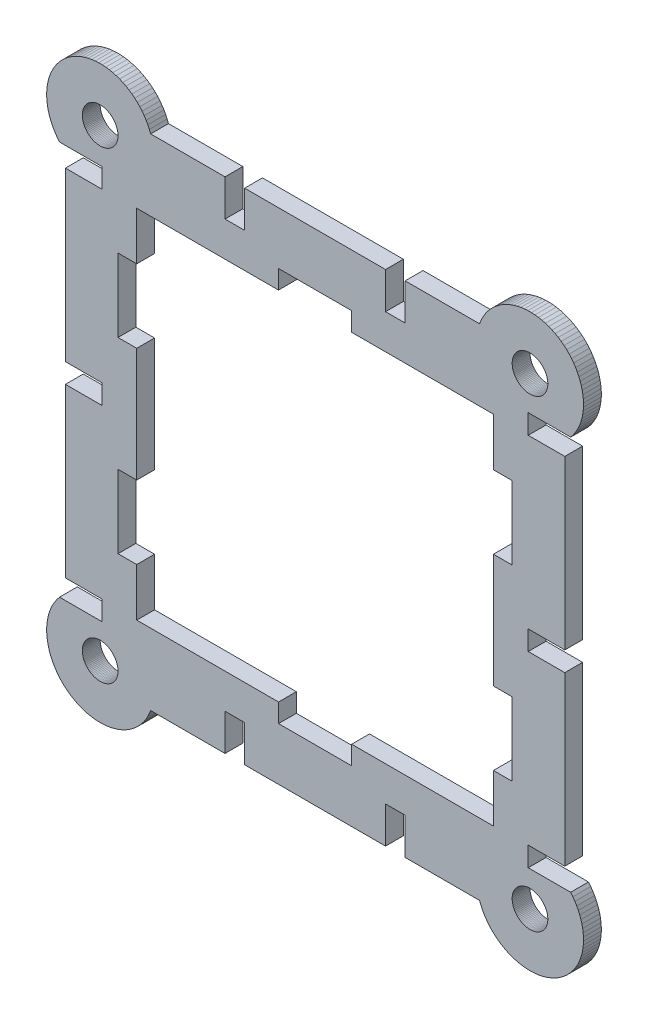
SolidWorks part; units mm, degrees
material "Plain Carbon Steel"
ref_plane "Front Plane" through (0, 0, 0) normal (0, 0, 1) x (1, 0, 0)
ref_plane "Top Plane" through (0, 0, 0) normal (0, 1, 0) x (1, 0, 0)
ref_plane "Right Plane" through (0, 0, 0) normal (1, 0, 0) x (0, 0, -1)
sketch "Model" plane through (0, 0, 0) normal (0, 0, 1) x (1, 0, 0)
  line L0 (1214.7706, -74.0372) -> (1215.0892, -74.1115)
  line L1 (1217.9525, -76.1633) -> (1218.1253, -76.4412)
  line L2 (1217.5543, -82.2379) -> (1217.3307, -82.4767)
  line L3 (1216.8389, -82.9079) -> (1216.573, -83.0985)
  line L4 (1218.5298, -77.334) -> (1218.6248, -77.6471)
  line L5 (1215.7086, -83.5606) -> (1215.4023, -83.6758)
  line L6 (1214.1222, -73.9519) -> (1214.4478, -73.9839)
  line L7 (1218.7524, -78.2885) -> (1218.7844, -78.6142)
  line L8 (1218.2795, -81.1526) -> (1218.1253, -81.4412)
  line L9 (1217.0919, -82.7004) -> (1216.8389, -82.9079)
  line L10 (1217.7619, -81.985) -> (1217.5543, -82.2379)
  line L11 (1216.2951, -83.2713) -> (1216.0066, -83.4255)
  line L12 (1216.0066, -74.4568) -> (1216.2951, -74.611)
  line L13 (1218.5298, -80.5484) -> (1218.4145, -80.8546)
  line L14 (1212.501, -83.7708) -> (1212.1879, -83.6758)
  line L15 (1213.4681, -83.9305) -> (1213.1425, -83.8984)
  line L16 (1212.1879, -83.6758) -> (1211.8817, -83.5606)
  line L17 (1218.1253, -76.4412) -> (1218.2795, -76.7297)
  line L18 (1215.0892, -74.1115) -> (1215.4023, -74.2065)
  line L19 (1218.6248, -80.2353) -> (1218.5298, -80.5484)
  line L20 (1216.8389, -74.9744) -> (1217.0919, -75.182)
  line L21 (1218.4145, -80.8546) -> (1218.2795, -81.1526)
  line L22 (1214.1222, -83.9305) -> (1213.7951, -83.9412)
  line L23 (1211.2951, -83.2713) -> (1211.0173, -83.0985)
  line L24 (1218.2795, -76.7297) -> (1218.4145, -77.0278)
  line L25 (1218.6991, -79.9166) -> (1218.6248, -80.2353)
  line L26 (1217.3307, -82.4767) -> (1217.0919, -82.7004)
  line L27 (1216.573, -74.7838) -> (1216.8389, -74.9744)
  line L28 (1217.9525, -81.719) -> (1217.7619, -81.985)
  line L29 (1211.0173, -83.0985) -> (1210.7513, -82.9079)
  line L30 (1209.8284, -81.985) -> (1209.6378, -81.719)
  line L31 (1213.7951, -83.9412) -> (1213.4681, -83.9305)
  line L32 (1215.7086, -74.3218) -> (1216.0066, -74.4568)
  line L33 (1217.0919, -75.182) -> (1217.3307, -75.4056)
  line L34 (1214.4478, -73.9839) -> (1214.7706, -74.0372)
  line L35 (1217.7619, -75.8974) -> (1217.9525, -76.1633)
  line L36 (1214.4478, -83.8984) -> (1214.1222, -83.9305)
  line L37 (1218.4145, -77.0278) -> (1218.5298, -77.334)
  line L38 (1214.7706, -83.8451) -> (1214.4478, -83.8984)
  line L39 (1218.6248, -77.6471) -> (1218.6991, -77.9657)
  line L40 (1215.4023, -74.2065) -> (1215.7086, -74.3218)
  line L41 (1218.7844, -78.6142) -> (1218.7951, -78.9412)
  line L42 (1216.2951, -74.611) -> (1216.573, -74.7838)
  line L43 (1218.6991, -77.9657) -> (1218.7524, -78.2885)
  line L44 (1218.7844, -79.2682) -> (1218.7524, -79.5938)
  line L45 (1218.7524, -79.5938) -> (1218.6991, -79.9166)
  line L46 (1216.573, -83.0985) -> (1216.2951, -83.2713)
  line L47 (1215.4023, -83.6758) -> (1215.0892, -83.7708)
  line L48 (1215.0892, -83.7708) -> (1214.7706, -83.8451)
  line L49 (1217.3307, -75.4056) -> (1217.5543, -75.6444)
  line L50 (1211.5837, -83.4255) -> (1211.2951, -83.2713)
  line L51 (1210.7513, -82.9079) -> (1210.4984, -82.7004)
  line L52 (1212.8197, -83.8451) -> (1212.501, -83.7708)
  line L53 (1210.2596, -82.4767) -> (1210.0359, -82.2379)
  line L54 (1210.0359, -82.2379) -> (1209.8284, -81.985)
  line L55 (1211.8817, -83.5606) -> (1211.5837, -83.4255)
  line L56 (1210.4984, -82.7004) -> (1210.2596, -82.4767)
  line L57 (1218.7951, -78.9412) -> (1218.7844, -79.2682)
  line L58 (1216.0066, -83.4255) -> (1215.7086, -83.5606)
  line L59 (1209.6378, -81.719) -> (1209.465, -81.4412)
  line L60 (1218.1253, -81.4412) -> (1217.9525, -81.719)
  line L61 (1213.1425, -83.8984) -> (1212.8197, -83.8451)
  line L62 (1217.5543, -75.6444) -> (1217.7619, -75.8974)
  line L63 (1209.465, -81.4412) -> (1209.3108, -81.1526)
  line L64 (1203.5457, -127.9412) -> (1208.7957, -127.9412)
  line L65 (1103.5457, -93.9412) -> (1103.5457, -107.4412)
  line L66 (1078.6558, -212.206) -> (1078.9039, -213.1675)
  line L67 (1090.7962, -83.2713) -> (1090.5183, -83.0985)
  line L68 (1163.7957, -93.9412) -> (1163.7957, -88.6912)
  line L69 (1093.9488, -73.9839) -> (1094.2716, -74.0372)
  line L70 (1086.2288, -222.1719) -> (1087.1197, -222.6105)
  line L71 (1208.8379, -79.5938) -> (1208.8058, -79.2682)
  line L72 (1091.689, -83.6758) -> (1091.3828, -83.5606)
  line L73 (1105.0451, -218.2666) -> (1105.6363, -217.4688)
  line L74 (1083.5457, -193.6912) -> (1093.7957, -193.6912)
  line L75 (1098.1258, -77.6471) -> (1098.2001, -77.9657)
  line L76 (1088.4666, -77.6471) -> (1088.5615, -77.334)
  line L77 (1095.5076, -83.4255) -> (1095.2096, -83.5606)
  line L78 (1092.8896, -223.9357) -> (1093.8827, -223.9297)
  line L79 (1203.5457, -93.9412) -> (1163.7957, -93.9412)
  line L80 (1098.2957, -127.9412) -> (1103.5457, -127.9412)
  line L81 (1078.3896, -207.2698) -> (1078.3117, -208.2597)
  line L82 (1096.8317, -82.4767) -> (1096.5929, -82.7004)
  line L83 (1097.9156, -77.0278) -> (1098.0308, -77.334)
  line L84 (1103.5457, -107.4412) -> (1098.2957, -107.4412)
  line L85 (1128.2957, -203.6912) -> (1133.7957, -203.6912)
  line L86 (1105.6363, -217.4688) -> (1106.1735, -216.6336)
  line L87 (1098.7229, -222.9251) -> (1099.6363, -222.5354)
  line L88 (1090.9133, -223.7507) -> (1091.8984, -223.8759)
  line L89 (1091.3828, -83.5606) -> (1091.0847, -83.4255)
  line L90 (1199.653, -213.9412) -> (1200.0148, -214.8659)
  line L91 (1082.3119, -219.1561) -> (1083.0118, -219.8605)
  line L92 (1208.7957, -107.4412) -> (1203.5457, -107.4412)
  line L93 (1079.3469, -203.4259) -> (1079.0126, -204.361)
  line L94 (1093.6232, -83.9305) -> (1093.2962, -83.9412)
  line L95 (1092.9692, -83.9305) -> (1092.6435, -83.8984)
  line L96 (1083.7569, -220.5171) -> (1084.5437, -221.1229)
  line L97 (1208.8912, -79.9166) -> (1208.8379, -79.5938)
  line L98 (1103.7108, -219.7363) -> (1104.4023, -219.0236)
  line L99 (1203.5457, -107.4412) -> (1203.5457, -93.9412)
  line L100 (1105.0451, -69.6157) -> (1104.4023, -68.8588)
  line L101 (1087.1197, -222.6105) -> (1088.0377, -222.9892)
  line L102 (1080.0209, -215.9246) -> (1080.5121, -216.7876)
  line L103 (1098.2534, -79.5938) -> (1098.2001, -79.9166)
  line L104 (1088.9787, -223.3064) -> (1089.9387, -223.5606)
  line L105 (1078.3529, -210.2443) -> (1078.4719, -211.2301)
  line L106 (1088.9661, -81.4412) -> (1088.8118, -81.1526)
  line L107 (1079.7424, -202.5151) -> (1079.3469, -203.4259)
  line L108 (1084.5437, -221.1229) -> (1085.3689, -221.6753)
  line L109 (1093.9488, -83.8984) -> (1093.6232, -83.9305)
  line L110 (1203.5457, -159.9412) -> (1203.5457, -127.9412)
  line L111 (1095.8566, -223.721) -> (1096.8289, -223.5192)
  line L112 (1133.7957, -203.6912) -> (1133.7957, -213.9412)
  line L113 (1200.437, -215.7647) -> (1200.9178, -216.6336)
  line L114 (1080.7096, -200.7817) -> (1080.1973, -201.6324)
  line L115 (1101.3758, -221.5792) -> (1102.1943, -221.0169)
  line L116 (1093.7957, -193.6912) -> (1093.7957, -199.1912)
  line L117 (1090.9133, -64.1316) -> (1089.9387, -64.3218)
  line L118 (1093.7957, -141.1912) -> (1093.7957, -146.6912)
  line L119 (1080.1973, -201.6324) -> (1079.7424, -202.5151)
  line L120 (1102.1943, -66.8654) -> (1101.3758, -66.3031)
  line L121 (1178.7957, -203.6912) -> (1178.7957, -213.9412)
  line L122 (1093.8827, -223.9297) -> (1094.8731, -223.858)
  line L123 (1100.5218, -222.0861) -> (1101.3758, -221.5792)
  line L124 (1128.2957, -84.1912) -> (1128.2957, -73.9412)
  line L125 (1103.7108, -68.146) -> (1102.9738, -67.4806)
  line L126 (1079.588, -215.0309) -> (1080.0209, -215.9246)
  line L127 (1093.7957, -146.6912) -> (1083.5457, -146.6912)
  line L128 (1081.0593, -217.6163) -> (1081.6601, -218.407)
  line L129 (1097.7858, -223.2535) -> (1098.7229, -222.9251)
  line L130 (1088.0377, -222.9892) -> (1088.9787, -223.3064)
  line L131 (1078.9039, -213.1675) -> (1079.2151, -214.1105)
  line L132 (1078.4719, -211.2301) -> (1078.6558, -212.206)
  line L133 (1088.2962, -208.9412) -> (1088.3069, -208.6142)
  line L134 (1097.7858, -64.6288) -> (1096.8289, -64.3631)
  line L135 (1107.0765, -214.8659) -> (1107.4383, -213.9412)
  line L136 (1102.9738, -220.4017) -> (1103.7108, -219.7363)
  line L137 (1091.8984, -223.8759) -> (1092.8896, -223.9357)
  line L138 (1091.0847, -83.4255) -> (1090.7962, -83.2713)
  line L139 (1098.2957, -107.4412) -> (1098.2957, -127.9412)
  line L140 (1088.6768, -80.8546) -> (1088.5615, -80.5484)
  line L141 (1107.0765, -73.0164) -> (1106.6543, -72.1176)
  line L142 (1102.9738, -67.4806) -> (1102.1943, -66.8654)
  line L143 (1081.6601, -218.407) -> (1082.3119, -219.1561)
  line L144 (1106.6543, -72.1176) -> (1106.1735, -71.2487)
  line L145 (1133.7957, -213.9412) -> (1173.2957, -213.9412)
  line L146 (1102.1943, -221.0169) -> (1102.9738, -220.4017)
  line L147 (1078.7408, -205.3161) -> (1078.5328, -206.2871)
  line L148 (1079.7424, -85.3673) -> (1080.1973, -86.25)
  line L149 (1107.4383, -213.9412) -> (1128.2957, -213.9412)
  line L150 (1078.4719, -76.6522) -> (1078.3529, -77.6381)
  line L151 (1079.2151, -214.1105) -> (1079.588, -215.0309)
  line L152 (1209.0605, -80.5484) -> (1208.9655, -80.2353)
  line L153 (1163.7957, -88.6912) -> (1143.2957, -88.6912)
  line L154 (1088.3923, -207.9657) -> (1088.4666, -207.6471)
  line L155 (1128.2957, -73.9412) -> (1107.4383, -73.9412)
  line L156 (1085.3689, -221.6753) -> (1086.2288, -222.1719)
  line L157 (1173.2957, -213.9412) -> (1173.2957, -203.6912)
  line L158 (1081.277, -199.9668) -> (1080.7096, -200.7817)
  line L159 (1078.5328, -206.2871) -> (1078.3896, -207.2698)
  line L160 (1083.0118, -219.8605) -> (1083.7569, -220.5171)
  line L161 (1093.7957, -199.1912) -> (1081.8972, -199.1912)
  line L162 (1084.5437, -66.7595) -> (1083.7569, -67.3653)
  line L163 (1094.8731, -223.858) -> (1095.8566, -223.721)
  line L164 (1226.0321, -217.6163) -> (1226.5792, -216.7876)
  line L165 (1213.2957, -146.6912) -> (1213.2957, -141.1912)
  line L166 (1173.2957, -203.6912) -> (1178.7957, -203.6912)
  line L167 (1228.6195, -211.2301) -> (1228.7384, -210.2443)
  line L168 (1096.8289, -64.3631) -> (1095.8566, -64.1613)
  line L169 (1106.6543, -215.7647) -> (1107.0765, -214.8659)
  line L170 (1089.9387, -223.5606) -> (1090.9133, -223.7507)
  line L171 (1225.8143, -199.9668) -> (1225.1942, -199.1912)
  line L172 (1078.7408, -82.5662) -> (1079.0126, -83.5213)
  line L173 (1087.1197, -65.2718) -> (1086.2288, -65.7104)
  line L174 (1209.3056, -223.2535) -> (1210.2624, -223.5192)
  line L175 (1227.5034, -215.0309) -> (1227.8762, -214.1105)
  line L176 (1096.8289, -223.5192) -> (1097.7858, -223.2535)
  line L177 (1128.2957, -213.9412) -> (1128.2957, -203.6912)
  line L178 (1085.3689, -66.207) -> (1084.5437, -66.7595)
  line L179 (1089.9387, -64.3218) -> (1088.9787, -64.576)
  line L180 (1226.894, -201.6324) -> (1226.3817, -200.7817)
  line L181 (1101.3758, -66.3031) -> (1100.5218, -65.7962)
  line L182 (1106.1735, -216.6336) -> (1106.6543, -215.7647)
  line L183 (1208.7957, -127.9412) -> (1208.7957, -107.4412)
  line L184 (1099.6363, -65.3469) -> (1098.7229, -64.9572)
  line L185 (1078.5328, -81.5952) -> (1078.7408, -82.5662)
  line L186 (1208.8058, -79.2682) -> (1208.7951, -78.9412)
  line L187 (1220.8625, -222.1719) -> (1221.7224, -221.6753)
  line L188 (1081.6601, -69.4754) -> (1081.0593, -70.266)
  line L189 (1203.3805, -219.7363) -> (1204.1176, -220.4017)
  line L190 (1215.1929, -223.8759) -> (1216.178, -223.7507)
  line L191 (1078.9039, -74.7148) -> (1078.6558, -75.6763)
  line L192 (1079.0126, -83.5213) -> (1079.3469, -84.4564)
  line L193 (1223.5457, -146.6912) -> (1213.2957, -146.6912)
  line L194 (1078.2994, -78.6297) -> (1078.3117, -79.6226)
  line L195 (1088.3069, -208.6142) -> (1088.339, -208.2885)
  line L196 (1100.5218, -65.7962) -> (1099.6363, -65.3469)
  line L197 (1083.0118, -68.0218) -> (1082.3119, -68.7262)
  line L198 (1086.2288, -65.7104) -> (1085.3689, -66.207)
  line L199 (1078.3117, -79.6226) -> (1078.3896, -80.6126)
  line L200 (1104.4023, -219.0236) -> (1105.0451, -218.2666)
  line L201 (1093.7957, -94.1912) -> (1083.5457, -94.1912)
  line L202 (1200.0148, -214.8659) -> (1200.437, -215.7647)
  line L203 (1099.6363, -222.5354) -> (1100.5218, -222.0861)
  line L204 (1092.8896, -63.9467) -> (1091.8984, -64.0064)
  line L205 (1080.5121, -216.7876) -> (1081.0593, -217.6163)
  line L206 (1079.3469, -84.4564) -> (1079.7424, -85.3673)
  line L207 (1088.0377, -64.8931) -> (1087.1197, -65.2718)
  line L208 (1202.689, -219.0236) -> (1203.3805, -219.7363)
  line L209 (1078.3529, -77.6381) -> (1078.2994, -78.6297)
  line L210 (1093.8827, -63.9526) -> (1092.8896, -63.9467)
  line L211 (1088.9787, -64.576) -> (1088.0377, -64.8931)
  line L212 (1228.7919, -209.2527) -> (1228.7797, -208.2597)
  line L213 (1078.6558, -75.6763) -> (1078.4719, -76.6522)
  line L214 (1083.5457, -94.1912) -> (1083.5457, -141.1912)
  line L215 (1081.277, -87.9156) -> (1081.8972, -88.6912)
  line L216 (1094.8731, -64.0243) -> (1093.8827, -63.9526)
  line L217 (1081.8972, -88.6912) -> (1093.7957, -88.6912)
  line L218 (1227.0704, -215.9246) -> (1227.5034, -215.0309)
  line L219 (1105.6363, -70.4135) -> (1105.0451, -69.6157)
  line L220 (1078.3896, -80.6126) -> (1078.5328, -81.5952)
  line L221 (1143.2957, -93.9412) -> (1103.5457, -93.9412)
  line L222 (1219.0536, -222.9892) -> (1219.9716, -222.6105)
  line L223 (1178.7957, -213.9412) -> (1199.653, -213.9412)
  line L224 (1080.7096, -87.1007) -> (1081.277, -87.9156)
  line L225 (1209.3056, -64.6288) -> (1208.3684, -64.9572)
  line L226 (1213.2087, -223.9297) -> (1214.2017, -223.9357)
  line L227 (1207.4551, -222.5354) -> (1208.3684, -222.9251)
  line L228 (1104.4023, -68.8588) -> (1103.7108, -68.146)
  line L229 (1091.8984, -64.0064) -> (1090.9133, -64.1316)
  line L230 (1228.7017, -207.2698) -> (1228.5585, -206.2871)
  line L231 (1228.1874, -213.1675) -> (1228.4355, -212.206)
  line L232 (1088.339, -208.2885) -> (1088.3923, -207.9657)
  line L233 (1202.0463, -69.6157) -> (1201.455, -70.4135)
  line L234 (1178.7957, -73.9412) -> (1178.7957, -84.1912)
  line L235 (1219.0536, -64.8931) -> (1218.1126, -64.576)
  line L236 (1227.8762, -73.7718) -> (1227.5034, -72.8514)
  line L237 (1083.7569, -67.3653) -> (1083.0118, -68.0218)
  line L238 (1225.4312, -69.4754) -> (1224.7794, -68.7262)
  line L239 (1106.1735, -71.2487) -> (1105.6363, -70.4135)
  line L240 (1212.2182, -223.858) -> (1213.2087, -223.9297)
  line L241 (1227.3489, -85.3673) -> (1227.7444, -84.4564)
  line L242 (1223.3345, -67.3653) -> (1222.5476, -66.7595)
  line L243 (1226.894, -86.25) -> (1227.3489, -85.3673)
  line L244 (1107.4383, -73.9412) -> (1107.0765, -73.0164)
  line L245 (1225.8143, -87.9156) -> (1226.3817, -87.1007)
  line L246 (1222.5476, -66.7595) -> (1221.7224, -66.207)
  line L247 (1201.455, -217.4688) -> (1202.0463, -218.2666)
  line L248 (1221.7224, -221.6753) -> (1222.5476, -221.1229)
  line L249 (1217.1527, -223.5606) -> (1218.1126, -223.3064)
  line L250 (1081.0593, -70.266) -> (1080.5121, -71.0947)
  line L251 (1204.8971, -221.0169) -> (1205.7156, -221.5792)
  line L252 (1200.0148, -73.0164) -> (1199.653, -73.9412)
  line L253 (1225.1942, -88.6912) -> (1225.8143, -87.9156)
  line L254 (1228.7919, -78.6297) -> (1228.7384, -77.6381)
  line L255 (1213.2957, -199.1912) -> (1213.2957, -193.6912)
  line L256 (1228.7017, -80.6126) -> (1228.7797, -79.6226)
  line L257 (1228.7384, -210.2443) -> (1228.7919, -209.2527)
  line L258 (1202.0463, -218.2666) -> (1202.689, -219.0236)
  line L259 (1213.2957, -88.6912) -> (1225.1942, -88.6912)
  line L260 (1204.1176, -220.4017) -> (1204.8971, -221.0169)
  line L261 (1228.3505, -205.3161) -> (1228.0788, -204.361)
  line L262 (1079.588, -72.8514) -> (1079.2151, -73.7718)
  line L263 (1079.2151, -73.7718) -> (1078.9039, -74.7148)
  line L264 (1208.3684, -222.9251) -> (1209.3056, -223.2535)
  line L265 (1224.0795, -219.8605) -> (1224.7794, -219.1561)
  line L266 (1228.7797, -208.2597) -> (1228.7017, -207.2698)
  line L267 (1093.7957, -88.6912) -> (1093.7957, -94.1912)
  line L268 (1206.5695, -222.0861) -> (1207.4551, -222.5354)
  line L269 (1206.5695, -65.7962) -> (1205.7156, -66.3031)
  line L270 (1173.2957, -84.1912) -> (1173.2957, -73.9412)
  line L271 (1207.4551, -65.3469) -> (1206.5695, -65.7962)
  line L272 (1226.5792, -216.7876) -> (1227.0704, -215.9246)
  line L273 (1227.5034, -72.8514) -> (1227.0704, -71.9578)
  line L274 (1095.8566, -64.1613) -> (1094.8731, -64.0243)
  line L275 (1222.5476, -221.1229) -> (1223.3345, -220.5171)
  line L276 (1082.3119, -68.7262) -> (1081.6601, -69.4754)
  line L277 (1225.1942, -199.1912) -> (1213.2957, -199.1912)
  line L278 (1203.3805, -68.146) -> (1202.689, -68.8588)
  line L279 (1228.1874, -74.7148) -> (1227.8762, -73.7718)
  line L280 (1080.0209, -71.9578) -> (1079.588, -72.8514)
  line L281 (1080.1973, -86.25) -> (1080.7096, -87.1007)
  line L282 (1214.2017, -223.9357) -> (1215.1929, -223.8759)
  line L283 (1227.7444, -203.4259) -> (1227.3489, -202.5151)
  line L284 (1205.7156, -221.5792) -> (1206.5695, -222.0861)
  line L285 (1213.2087, -63.9526) -> (1212.2182, -64.0243)
  line L286 (1080.5121, -71.0947) -> (1080.0209, -71.9578)
  line L287 (1213.2957, -193.6912) -> (1223.5457, -193.6912)
  line L288 (1215.1929, -64.0064) -> (1214.2017, -63.9467)
  line L289 (1226.3817, -200.7817) -> (1225.8143, -199.9668)
  line L290 (1143.2957, -199.1912) -> (1143.2957, -193.9412)
  line L291 (1210.2624, -223.5192) -> (1211.2347, -223.721)
  line L292 (1227.7444, -84.4564) -> (1228.0788, -83.5213)
  line L293 (1218.1126, -223.3064) -> (1219.0536, -222.9892)
  line L294 (1201.455, -70.4135) -> (1200.9178, -71.2487)
  line L295 (1228.5585, -81.5952) -> (1228.7017, -80.6126)
  line L296 (1216.178, -64.1316) -> (1215.1929, -64.0064)
  line L297 (1205.7156, -66.3031) -> (1204.8971, -66.8654)
  line L298 (1078.3117, -208.2597) -> (1078.2994, -209.2527)
  line L299 (1226.3817, -87.1007) -> (1226.894, -86.25)
  line L300 (1223.5457, -193.6912) -> (1223.5457, -146.6912)
  line L301 (1225.4312, -218.407) -> (1226.0321, -217.6163)
  line L302 (1228.0788, -83.5213) -> (1228.3505, -82.5662)
  line L303 (1228.3505, -82.5662) -> (1228.5585, -81.5952)
  line L304 (1224.7794, -219.1561) -> (1225.4312, -218.407)
  line L305 (1227.8762, -214.1105) -> (1228.1874, -213.1675)
  line L306 (1226.0321, -70.266) -> (1225.4312, -69.4754)
  line L307 (1219.9716, -222.6105) -> (1220.8625, -222.1719)
  line L308 (1228.5585, -206.2871) -> (1228.3505, -205.3161)
  line L309 (1213.2957, -141.1912) -> (1223.5457, -141.1912)
  line L310 (1083.5457, -141.1912) -> (1093.7957, -141.1912)
  line L311 (1228.6195, -76.6522) -> (1228.4355, -75.6763)
  line L312 (1228.4355, -75.6763) -> (1228.1874, -74.7148)
  line L313 (1228.7797, -79.6226) -> (1228.7919, -78.6297)
  line L314 (1224.7794, -68.7262) -> (1224.0795, -68.0218)
  line L315 (1211.2347, -223.721) -> (1212.2182, -223.858)
  line L316 (1221.7224, -66.207) -> (1220.8625, -65.7104)
  line L317 (1200.9178, -216.6336) -> (1201.455, -217.4688)
  line L318 (1219.9716, -65.2718) -> (1219.0536, -64.8931)
  line L319 (1226.5792, -71.0947) -> (1226.0321, -70.266)
  line L320 (1098.2957, -180.4412) -> (1098.2957, -159.9412)
  line L321 (1202.689, -68.8588) -> (1202.0463, -69.6157)
  line L322 (1212.2182, -64.0243) -> (1211.2347, -64.1613)
  line L323 (1220.8625, -65.7104) -> (1219.9716, -65.2718)
  line L324 (1210.2624, -64.3631) -> (1209.3056, -64.6288)
  line L325 (1208.3684, -64.9572) -> (1207.4551, -65.3469)
  line L326 (1204.8971, -66.8654) -> (1204.1176, -67.4806)
  line L327 (1204.1176, -67.4806) -> (1203.3805, -68.146)
  line L328 (1213.2957, -94.1912) -> (1213.2957, -88.6912)
  line L329 (1199.653, -73.9412) -> (1178.7957, -73.9412)
  line L330 (1228.0788, -204.361) -> (1227.7444, -203.4259)
  line L331 (1223.5457, -94.1912) -> (1213.2957, -94.1912)
  line L332 (1223.3345, -220.5171) -> (1224.0795, -219.8605)
  line L333 (1218.1126, -64.576) -> (1217.1527, -64.3218)
  line L334 (1083.5457, -146.6912) -> (1083.5457, -193.6912)
  line L335 (1216.178, -223.7507) -> (1217.1527, -223.5606)
  line L336 (1227.3489, -202.5151) -> (1226.894, -201.6324)
  line L337 (1079.0126, -204.361) -> (1078.7408, -205.3161)
  line L338 (1078.2994, -209.2527) -> (1078.3529, -210.2443)
  line L339 (1217.1527, -64.3218) -> (1216.178, -64.1316)
  line L340 (1228.4355, -212.206) -> (1228.6195, -211.2301)
  line L341 (1228.7384, -77.6381) -> (1228.6195, -76.6522)
  line L342 (1211.2347, -64.1613) -> (1210.2624, -64.3631)
  line L343 (1081.8972, -199.1912) -> (1081.277, -199.9668)
  line L344 (1200.9178, -71.2487) -> (1200.437, -72.1176)
  line L345 (1223.5457, -141.1912) -> (1223.5457, -94.1912)
  line L346 (1227.0704, -71.9578) -> (1226.5792, -71.0947)
  line L347 (1224.0795, -68.0218) -> (1223.3345, -67.3653)
  line L348 (1214.2017, -63.9467) -> (1213.2087, -63.9526)
  line L349 (1200.437, -72.1176) -> (1200.0148, -73.0164)
  line L350 (1178.7957, -84.1912) -> (1173.2957, -84.1912)
  line L351 (1173.2957, -73.9412) -> (1133.7957, -73.9412)
  line L352 (1133.7957, -73.9412) -> (1133.7957, -84.1912)
  line L353 (1133.7957, -84.1912) -> (1128.2957, -84.1912)
  line L354 (1098.7229, -64.9572) -> (1097.7858, -64.6288)
  line L355 (1088.3069, -78.6142) -> (1088.339, -78.2885)
  line L356 (1088.339, -78.2885) -> (1088.3923, -77.9657)
  line L357 (1088.3923, -77.9657) -> (1088.4666, -77.6471)
  line L358 (1088.5615, -77.334) -> (1088.6768, -77.0278)
  line L359 (1088.6768, -77.0278) -> (1088.8118, -76.7297)
  line L360 (1088.8118, -76.7297) -> (1088.9661, -76.4412)
  line L361 (1088.9661, -76.4412) -> (1089.1388, -76.1633)
  line L362 (1089.1388, -76.1633) -> (1089.3294, -75.8974)
  line L363 (1089.3294, -75.8974) -> (1089.537, -75.6444)
  line L364 (1089.537, -75.6444) -> (1089.7606, -75.4056)
  line L365 (1089.7606, -75.4056) -> (1089.9995, -75.182)
  line L366 (1089.9995, -75.182) -> (1090.2524, -74.9744)
  line L367 (1090.2524, -74.9744) -> (1090.5183, -74.7838)
  line L368 (1090.5183, -74.7838) -> (1090.7962, -74.611)
  line L369 (1090.7962, -74.611) -> (1091.0847, -74.4568)
  line L370 (1091.0847, -74.4568) -> (1091.3828, -74.3218)
  line L371 (1091.3828, -74.3218) -> (1091.689, -74.2065)
  line L372 (1091.689, -74.2065) -> (1092.0021, -74.1115)
  line L373 (1092.0021, -74.1115) -> (1092.3207, -74.0372)
  line L374 (1092.3207, -74.0372) -> (1092.6435, -73.9839)
  line L375 (1092.6435, -73.9839) -> (1092.9692, -73.9519)
  line L376 (1092.9692, -73.9519) -> (1093.2962, -73.9412)
  line L377 (1093.2962, -73.9412) -> (1093.6232, -73.9519)
  line L378 (1093.6232, -73.9519) -> (1093.9488, -73.9839)
  line L379 (1094.2716, -74.0372) -> (1094.5903, -74.1115)
  line L380 (1094.5903, -74.1115) -> (1094.9034, -74.2065)
  line L381 (1094.9034, -74.2065) -> (1095.2096, -74.3218)
  line L382 (1095.2096, -74.3218) -> (1095.5076, -74.4568)
  line L383 (1095.5076, -74.4568) -> (1095.7962, -74.611)
  line L384 (1095.7962, -74.611) -> (1096.074, -74.7838)
  line L385 (1096.074, -74.7838) -> (1096.34, -74.9744)
  line L386 (1096.34, -74.9744) -> (1096.5929, -75.182)
  line L387 (1096.5929, -75.182) -> (1096.8317, -75.4056)
  line L388 (1096.8317, -75.4056) -> (1097.0554, -75.6444)
  line L389 (1097.0554, -75.6444) -> (1097.2629, -75.8974)
  line L390 (1097.2629, -75.8974) -> (1097.4535, -76.1633)
  line L391 (1097.4535, -76.1633) -> (1097.6263, -76.4412)
  line L392 (1097.6263, -76.4412) -> (1097.7805, -76.7297)
  line L393 (1097.7805, -76.7297) -> (1097.9156, -77.0278)
  line L394 (1098.0308, -77.334) -> (1098.1258, -77.6471)
  line L395 (1098.2001, -77.9657) -> (1098.2534, -78.2885)
  line L396 (1098.2534, -78.2885) -> (1098.2855, -78.6142)
  line L397 (1098.2855, -78.6142) -> (1098.2962, -78.9412)
  line L398 (1098.2962, -78.9412) -> (1098.2855, -79.2682)
  line L399 (1098.2855, -79.2682) -> (1098.2534, -79.5938)
  line L400 (1098.2001, -79.9166) -> (1098.1258, -80.2353)
  line L401 (1098.1258, -80.2353) -> (1098.0308, -80.5484)
  line L402 (1098.0308, -80.5484) -> (1097.9156, -80.8546)
  line L403 (1097.9156, -80.8546) -> (1097.7805, -81.1526)
  line L404 (1097.7805, -81.1526) -> (1097.6263, -81.4412)
  line L405 (1097.6263, -81.4412) -> (1097.4535, -81.719)
  line L406 (1097.4535, -81.719) -> (1097.2629, -81.985)
  line L407 (1097.2629, -81.985) -> (1097.0554, -82.2379)
  line L408 (1097.0554, -82.2379) -> (1096.8317, -82.4767)
  line L409 (1096.5929, -82.7004) -> (1096.34, -82.9079)
  line L410 (1096.34, -82.9079) -> (1096.074, -83.0985)
  line L411 (1096.074, -83.0985) -> (1095.7962, -83.2713)
  line L412 (1095.7962, -83.2713) -> (1095.5076, -83.4255)
  line L413 (1095.2096, -83.5606) -> (1094.9034, -83.6758)
  line L414 (1094.9034, -83.6758) -> (1094.5903, -83.7708)
  line L415 (1094.5903, -83.7708) -> (1094.2716, -83.8451)
  line L416 (1094.2716, -83.8451) -> (1093.9488, -83.8984)
  line L417 (1093.2962, -83.9412) -> (1092.9692, -83.9305)
  line L418 (1092.6435, -83.8984) -> (1092.3207, -83.8451)
  line L419 (1092.3207, -83.8451) -> (1092.0021, -83.7708)
  line L420 (1092.0021, -83.7708) -> (1091.689, -83.6758)
  line L421 (1090.5183, -83.0985) -> (1090.2524, -82.9079)
  line L422 (1090.2524, -82.9079) -> (1089.9995, -82.7004)
  line L423 (1089.9995, -82.7004) -> (1089.7606, -82.4767)
  line L424 (1089.7606, -82.4767) -> (1089.537, -82.2379)
  line L425 (1089.537, -82.2379) -> (1089.3294, -81.985)
  line L426 (1089.3294, -81.985) -> (1089.1388, -81.719)
  line L427 (1089.1388, -81.719) -> (1088.9661, -81.4412)
  line L428 (1088.8118, -81.1526) -> (1088.6768, -80.8546)
  line L429 (1088.5615, -80.5484) -> (1088.4666, -80.2353)
  line L430 (1088.4666, -80.2353) -> (1088.3923, -79.9166)
  line L431 (1088.3923, -79.9166) -> (1088.339, -79.5938)
  line L432 (1088.339, -79.5938) -> (1088.3069, -79.2682)
  line L433 (1088.3069, -79.2682) -> (1088.2962, -78.9412)
  line L434 (1088.2962, -78.9412) -> (1088.3069, -78.6142)
  line L435 (1217.5543, -212.2379) -> (1217.3307, -212.4767)
  line L436 (1217.3307, -212.4767) -> (1217.0919, -212.7004)
  line L437 (1217.0919, -212.7004) -> (1216.8389, -212.9079)
  line L438 (1216.8389, -212.9079) -> (1216.573, -213.0985)
  line L439 (1216.573, -213.0985) -> (1216.2951, -213.2713)
  line L440 (1216.2951, -213.2713) -> (1216.0066, -213.4255)
  line L441 (1216.0066, -213.4255) -> (1215.7086, -213.5606)
  line L442 (1215.7086, -213.5606) -> (1215.4023, -213.6758)
  line L443 (1215.4023, -213.6758) -> (1215.0892, -213.7708)
  line L444 (1215.0892, -213.7708) -> (1214.7706, -213.8451)
  line L445 (1214.7706, -213.8451) -> (1214.4478, -213.8984)
  line L446 (1214.4478, -213.8984) -> (1214.1222, -213.9305)
  line L447 (1214.1222, -213.9305) -> (1213.7951, -213.9412)
  line L448 (1213.7951, -213.9412) -> (1213.4681, -213.9305)
  line L449 (1213.4681, -213.9305) -> (1213.1425, -213.8984)
  line L450 (1213.1425, -213.8984) -> (1212.8197, -213.8451)
  line L451 (1212.8197, -213.8451) -> (1212.501, -213.7708)
  line L452 (1212.501, -213.7708) -> (1212.1879, -213.6758)
  line L453 (1212.1879, -213.6758) -> (1211.8817, -213.5606)
  line L454 (1211.8817, -213.5606) -> (1211.5837, -213.4255)
  line L455 (1211.5837, -213.4255) -> (1211.2951, -213.2713)
  line L456 (1211.2951, -213.2713) -> (1211.0173, -213.0985)
  line L457 (1211.0173, -213.0985) -> (1210.7513, -212.9079)
  line L458 (1210.7513, -212.9079) -> (1210.4984, -212.7004)
  line L459 (1210.4984, -212.7004) -> (1210.2596, -212.4767)
  line L460 (1210.2596, -212.4767) -> (1210.0359, -212.2379)
  line L461 (1210.0359, -212.2379) -> (1209.8284, -211.985)
  line L462 (1209.8284, -211.985) -> (1209.6378, -211.719)
  line L463 (1209.6378, -211.719) -> (1209.465, -211.4412)
  line L464 (1209.465, -211.4412) -> (1209.3108, -211.1526)
  line L465 (1209.3108, -211.1526) -> (1209.1757, -210.8546)
  line L466 (1209.1757, -210.8546) -> (1209.0605, -210.5484)
  line L467 (1209.0605, -210.5484) -> (1208.9655, -210.2353)
  line L468 (1208.9655, -210.2353) -> (1208.8912, -209.9166)
  line L469 (1208.8912, -209.9166) -> (1208.8379, -209.5938)
  line L470 (1208.8379, -209.5938) -> (1208.8058, -209.2682)
  line L471 (1208.8058, -209.2682) -> (1208.7951, -208.9412)
  line L472 (1208.7951, -208.9412) -> (1208.8058, -208.6142)
  line L473 (1208.8058, -208.6142) -> (1208.8379, -208.2885)
  line L474 (1208.8379, -208.2885) -> (1208.8912, -207.9657)
  line L475 (1208.8912, -207.9657) -> (1208.9655, -207.6471)
  line L476 (1208.9655, -207.6471) -> (1209.0605, -207.334)
  line L477 (1209.0605, -207.334) -> (1209.1757, -207.0278)
  line L478 (1209.1757, -207.0278) -> (1209.3108, -206.7297)
  line L479 (1209.3108, -206.7297) -> (1209.465, -206.4412)
  line L480 (1209.465, -206.4412) -> (1209.6378, -206.1633)
  line L481 (1209.6378, -206.1633) -> (1209.8284, -205.8974)
  line L482 (1209.8284, -205.8974) -> (1210.0359, -205.6444)
  line L483 (1210.0359, -205.6444) -> (1210.2596, -205.4056)
  line L484 (1210.2596, -205.4056) -> (1210.4984, -205.182)
  line L485 (1210.4984, -205.182) -> (1210.7513, -204.9744)
  line L486 (1210.7513, -204.9744) -> (1211.0173, -204.7838)
  line L487 (1211.0173, -204.7838) -> (1211.2951, -204.611)
  line L488 (1211.2951, -204.611) -> (1211.5837, -204.4568)
  line L489 (1211.5837, -204.4568) -> (1211.8817, -204.3218)
  line L490 (1211.8817, -204.3218) -> (1212.1879, -204.2065)
  line L491 (1212.1879, -204.2065) -> (1212.501, -204.1115)
  line L492 (1212.501, -204.1115) -> (1212.8197, -204.0372)
  line L493 (1212.8197, -204.0372) -> (1213.1425, -203.9839)
  line L494 (1213.1425, -203.9839) -> (1213.4681, -203.9519)
  line L495 (1213.4681, -203.9519) -> (1213.7951, -203.9412)
  line L496 (1213.7951, -203.9412) -> (1214.1222, -203.9519)
  line L497 (1214.1222, -203.9519) -> (1214.4478, -203.9839)
  line L498 (1214.4478, -203.9839) -> (1214.7706, -204.0372)
  line L499 (1214.7706, -204.0372) -> (1215.0892, -204.1115)
  line L500 (1215.0892, -204.1115) -> (1215.4023, -204.2065)
  line L501 (1215.4023, -204.2065) -> (1215.7086, -204.3218)
  line L502 (1215.7086, -204.3218) -> (1216.0066, -204.4568)
  line L503 (1216.0066, -204.4568) -> (1216.2951, -204.611)
  line L504 (1216.2951, -204.611) -> (1216.573, -204.7838)
  line L505 (1216.573, -204.7838) -> (1216.8389, -204.9744)
  line L506 (1216.8389, -204.9744) -> (1217.0919, -205.182)
  line L507 (1217.0919, -205.182) -> (1217.3307, -205.4056)
  line L508 (1217.3307, -205.4056) -> (1217.5543, -205.6444)
  line L509 (1217.5543, -205.6444) -> (1217.7619, -205.8974)
  line L510 (1217.7619, -205.8974) -> (1217.9525, -206.1633)
  line L511 (1217.9525, -206.1633) -> (1218.1253, -206.4412)
  line L512 (1218.1253, -206.4412) -> (1218.2795, -206.7297)
  line L513 (1218.2795, -206.7297) -> (1218.4145, -207.0278)
  line L514 (1218.4145, -207.0278) -> (1218.5298, -207.334)
  line L515 (1218.5298, -207.334) -> (1218.6248, -207.6471)
  line L516 (1218.6248, -207.6471) -> (1218.6991, -207.9657)
  line L517 (1218.6991, -207.9657) -> (1218.7524, -208.2885)
  line L518 (1218.7524, -208.2885) -> (1218.7844, -208.6142)
  line L519 (1218.7844, -208.6142) -> (1218.7951, -208.9412)
  line L520 (1218.7951, -208.9412) -> (1218.7844, -209.2682)
  line L521 (1218.7844, -209.2682) -> (1218.7524, -209.5938)
  line L522 (1218.7524, -209.5938) -> (1218.6991, -209.9166)
  line L523 (1218.6991, -209.9166) -> (1218.6248, -210.2353)
  line L524 (1218.6248, -210.2353) -> (1218.5298, -210.5484)
  line L525 (1218.5298, -210.5484) -> (1218.4145, -210.8546)
  line L526 (1218.4145, -210.8546) -> (1218.2795, -211.1526)
  line L527 (1218.2795, -211.1526) -> (1218.1253, -211.4412)
  line L528 (1218.1253, -211.4412) -> (1217.9525, -211.719)
  line L529 (1217.9525, -211.719) -> (1217.7619, -211.985)
  line L530 (1217.7619, -211.985) -> (1217.5543, -212.2379)
  line L531 (1096.5929, -212.7004) -> (1096.34, -212.9079)
  line L532 (1096.34, -212.9079) -> (1096.074, -213.0985)
  line L533 (1096.074, -213.0985) -> (1095.7962, -213.2713)
  line L534 (1095.7962, -213.2713) -> (1095.5076, -213.4255)
  line L535 (1095.5076, -213.4255) -> (1095.2096, -213.5606)
  line L536 (1095.2096, -213.5606) -> (1094.9034, -213.6758)
  line L537 (1094.9034, -213.6758) -> (1094.5903, -213.7708)
  line L538 (1094.5903, -213.7708) -> (1094.2716, -213.8451)
  line L539 (1094.2716, -213.8451) -> (1093.9488, -213.8984)
  line L540 (1093.9488, -213.8984) -> (1093.6232, -213.9305)
  line L541 (1093.6232, -213.9305) -> (1093.2962, -213.9412)
  line L542 (1093.2962, -213.9412) -> (1092.9692, -213.9305)
  line L543 (1092.9692, -213.9305) -> (1092.6435, -213.8984)
  line L544 (1092.6435, -213.8984) -> (1092.3207, -213.8451)
  line L545 (1092.3207, -213.8451) -> (1092.0021, -213.7708)
  line L546 (1092.0021, -213.7708) -> (1091.689, -213.6758)
  line L547 (1091.689, -213.6758) -> (1091.3828, -213.5606)
  line L548 (1091.3828, -213.5606) -> (1091.0847, -213.4255)
  line L549 (1091.0847, -213.4255) -> (1090.7962, -213.2713)
  line L550 (1090.7962, -213.2713) -> (1090.5183, -213.0985)
  line L551 (1090.5183, -213.0985) -> (1090.2524, -212.9079)
  line L552 (1090.2524, -212.9079) -> (1089.9995, -212.7004)
  line L553 (1089.9995, -212.7004) -> (1089.7606, -212.4767)
  line L554 (1089.7606, -212.4767) -> (1089.537, -212.2379)
  line L555 (1089.537, -212.2379) -> (1089.3294, -211.985)
  line L556 (1089.3294, -211.985) -> (1089.1388, -211.719)
  line L557 (1089.1388, -211.719) -> (1088.9661, -211.4412)
  line L558 (1088.9661, -211.4412) -> (1088.8118, -211.1526)
  line L559 (1088.8118, -211.1526) -> (1088.6768, -210.8546)
  line L560 (1088.6768, -210.8546) -> (1088.5615, -210.5484)
  line L561 (1088.5615, -210.5484) -> (1088.4666, -210.2353)
  line L562 (1088.4666, -210.2353) -> (1088.3923, -209.9166)
  line L563 (1088.3923, -209.9166) -> (1088.339, -209.5938)
  line L564 (1088.339, -209.5938) -> (1088.3069, -209.2682)
  line L565 (1088.3069, -209.2682) -> (1088.2962, -208.9412)
  line L566 (1088.4666, -207.6471) -> (1088.5615, -207.334)
  line L567 (1088.5615, -207.334) -> (1088.6768, -207.0278)
  line L568 (1088.6768, -207.0278) -> (1088.8118, -206.7297)
  line L569 (1088.8118, -206.7297) -> (1088.9661, -206.4412)
  line L570 (1088.9661, -206.4412) -> (1089.1388, -206.1633)
  line L571 (1089.1388, -206.1633) -> (1089.3294, -205.8974)
  line L572 (1089.3294, -205.8974) -> (1089.537, -205.6444)
  line L573 (1089.537, -205.6444) -> (1089.7606, -205.4056)
  line L574 (1089.7606, -205.4056) -> (1089.9995, -205.182)
  line L575 (1089.9995, -205.182) -> (1090.2524, -204.9744)
  line L576 (1090.2524, -204.9744) -> (1090.5183, -204.7838)
  line L577 (1090.5183, -204.7838) -> (1090.7962, -204.611)
  line L578 (1090.7962, -204.611) -> (1091.0847, -204.4568)
  line L579 (1091.0847, -204.4568) -> (1091.3828, -204.3218)
  line L580 (1091.3828, -204.3218) -> (1091.689, -204.2065)
  line L581 (1091.689, -204.2065) -> (1092.0021, -204.1115)
  line L582 (1092.0021, -204.1115) -> (1092.3207, -204.0372)
  line L583 (1092.3207, -204.0372) -> (1092.6435, -203.9839)
  line L584 (1092.6435, -203.9839) -> (1092.9692, -203.9519)
  line L585 (1092.9692, -203.9519) -> (1093.2962, -203.9412)
  line L586 (1093.2962, -203.9412) -> (1093.6232, -203.9519)
  line L587 (1093.6232, -203.9519) -> (1093.9488, -203.9839)
  line L588 (1093.9488, -203.9839) -> (1094.2716, -204.0372)
  line L589 (1094.2716, -204.0372) -> (1094.5903, -204.1115)
  line L590 (1094.5903, -204.1115) -> (1094.9034, -204.2065)
  line L591 (1094.9034, -204.2065) -> (1095.2096, -204.3218)
  line L592 (1095.2096, -204.3218) -> (1095.5076, -204.4568)
  line L593 (1095.5076, -204.4568) -> (1095.7962, -204.611)
  line L594 (1095.7962, -204.611) -> (1096.074, -204.7838)
  line L595 (1096.074, -204.7838) -> (1096.34, -204.9744)
  line L596 (1096.34, -204.9744) -> (1096.5929, -205.182)
  line L597 (1096.5929, -205.182) -> (1096.8317, -205.4056)
  line L598 (1096.8317, -205.4056) -> (1097.0554, -205.6444)
  line L599 (1097.0554, -205.6444) -> (1097.2629, -205.8974)
  line L600 (1097.2629, -205.8974) -> (1097.4535, -206.1633)
  line L601 (1097.4535, -206.1633) -> (1097.6263, -206.4412)
  line L602 (1097.6263, -206.4412) -> (1097.7805, -206.7297)
  line L603 (1097.7805, -206.7297) -> (1097.9156, -207.0278)
  line L604 (1097.9156, -207.0278) -> (1098.0308, -207.334)
  line L605 (1098.0308, -207.334) -> (1098.1258, -207.6471)
  line L606 (1098.1258, -207.6471) -> (1098.2001, -207.9657)
  line L607 (1098.2001, -207.9657) -> (1098.2534, -208.2885)
  line L608 (1098.2534, -208.2885) -> (1098.2855, -208.6142)
  line L609 (1098.2855, -208.6142) -> (1098.2962, -208.9412)
  line L610 (1098.2962, -208.9412) -> (1098.2855, -209.2682)
  line L611 (1098.2855, -209.2682) -> (1098.2534, -209.5938)
  line L612 (1098.2534, -209.5938) -> (1098.2001, -209.9166)
  line L613 (1098.2001, -209.9166) -> (1098.1258, -210.2353)
  line L614 (1098.1258, -210.2353) -> (1098.0308, -210.5484)
  line L615 (1098.0308, -210.5484) -> (1097.9156, -210.8546)
  line L616 (1097.9156, -210.8546) -> (1097.7805, -211.1526)
  line L617 (1097.7805, -211.1526) -> (1097.6263, -211.4412)
  line L618 (1097.6263, -211.4412) -> (1097.4535, -211.719)
  line L619 (1097.4535, -211.719) -> (1097.2629, -211.985)
  line L620 (1097.2629, -211.985) -> (1097.0554, -212.2379)
  line L621 (1097.0554, -212.2379) -> (1096.8317, -212.4767)
  line L622 (1096.8317, -212.4767) -> (1096.5929, -212.7004)
  line L623 (1209.0605, -77.334) -> (1209.1757, -77.0278)
  line L624 (1209.1757, -77.0278) -> (1209.3108, -76.7297)
  line L625 (1209.3108, -76.7297) -> (1209.465, -76.4412)
  line L626 (1209.465, -76.4412) -> (1209.6378, -76.1633)
  line L627 (1209.6378, -76.1633) -> (1209.8284, -75.8974)
  line L628 (1209.8284, -75.8974) -> (1210.0359, -75.6444)
  line L629 (1210.0359, -75.6444) -> (1210.2596, -75.4056)
  line L630 (1210.2596, -75.4056) -> (1210.4984, -75.182)
  line L631 (1210.4984, -75.182) -> (1210.7513, -74.9744)
  line L632 (1210.7513, -74.9744) -> (1211.0173, -74.7838)
  line L633 (1211.0173, -74.7838) -> (1211.2951, -74.611)
  line L634 (1211.2951, -74.611) -> (1211.5837, -74.4568)
  line L635 (1211.5837, -74.4568) -> (1211.8817, -74.3218)
  line L636 (1211.8817, -74.3218) -> (1212.1879, -74.2065)
  line L637 (1212.1879, -74.2065) -> (1212.501, -74.1115)
  line L638 (1212.501, -74.1115) -> (1212.8197, -74.0372)
  line L639 (1212.8197, -74.0372) -> (1213.1425, -73.9839)
  line L640 (1213.1425, -73.9839) -> (1213.4681, -73.9519)
  line L641 (1213.4681, -73.9519) -> (1213.7951, -73.9412)
  line L642 (1213.7951, -73.9412) -> (1214.1222, -73.9519)
  line L643 (1209.3108, -81.1526) -> (1209.1757, -80.8546)
  line L644 (1209.1757, -80.8546) -> (1209.0605, -80.5484)
  line L645 (1208.9655, -80.2353) -> (1208.8912, -79.9166)
  line L646 (1208.7951, -78.9412) -> (1208.8058, -78.6142)
  line L647 (1208.8058, -78.6142) -> (1208.8379, -78.2885)
  line L648 (1208.8379, -78.2885) -> (1208.8912, -77.9657)
  line L649 (1208.8912, -77.9657) -> (1208.9655, -77.6471)
  line L650 (1208.9655, -77.6471) -> (1209.0605, -77.334)
  line L651 (1143.2957, -88.6912) -> (1143.2957, -93.9412)
  line L652 (1203.5457, -159.9412) -> (1208.7957, -159.9412)
  line L653 (1208.7957, -159.9412) -> (1208.7957, -180.4412)
  line L654 (1208.7957, -180.4412) -> (1203.5457, -180.4412)
  line L655 (1203.5457, -180.4412) -> (1203.5457, -193.9412)
  line L656 (1203.5457, -193.9412) -> (1163.7957, -193.9412)
  line L657 (1163.7957, -193.9412) -> (1163.7957, -199.1912)
  line L658 (1163.7957, -199.1912) -> (1143.2957, -199.1912)
  line L659 (1143.2957, -193.9412) -> (1103.5457, -193.9412)
  line L660 (1103.5457, -193.9412) -> (1103.5457, -180.4412)
  line L661 (1103.5457, -180.4412) -> (1098.2957, -180.4412)
  line L662 (1098.2957, -159.9412) -> (1103.5457, -159.9412)
  line L663 (1103.5457, -127.9412) -> (1103.5457, -159.9412)
  line L664 (1216.7957, -165.8326) -> (1218.9935, -165.8326)
  line L665 (1218.9248, -167.4076) -> (1218.8187, -167.7432)
  line L666 (1218.8187, -167.7432) -> (1218.6844, -167.9165)
  line L667 (1218.6844, -167.9165) -> (1218.5315, -167.9743)
  line L668 (1218.5315, -167.9743) -> (1217.2765, -167.9743)
  line L669 (1217.2765, -167.9743) -> (1217.1777, -167.9536)
  line L670 (1217.1777, -167.9536) -> (1217.0876, -167.8915)
  line L671 (1217.0876, -167.8915) -> (1216.933, -167.6433)
  line L672 (1216.933, -167.6433) -> (1216.83, -167.2828)
  line L673 (1216.83, -167.2828) -> (1216.7957, -166.8504)
  line L674 (1216.7957, -166.8504) -> (1216.7957, -165.8326)
  line L675 (1221.1036, -165.8326) -> (1216.7957, -165.8326)
  line L676 (1216.7957, -165.8326) -> (1216.7957, -166.8504)
  line L677 (1216.7957, -166.8504) -> (1216.83, -167.2828)
  line L678 (1216.83, -167.2828) -> (1216.933, -167.6433)
  line L679 (1216.933, -167.6433) -> (1217.0875, -167.8915)
  line L680 (1217.0875, -167.8915) -> (1217.1777, -167.9536)
  line L681 (1217.1777, -167.9536) -> (1217.2764, -167.9743)
  line L682 (1217.2764, -167.9743) -> (1218.5313, -167.9743)
  line L683 (1218.5313, -167.9743) -> (1218.6843, -167.9165)
  line L684 (1218.6843, -167.9165) -> (1218.8185, -167.7432)
  line L685 (1218.8185, -167.7432) -> (1218.9248, -167.4076)
  line L686 (1218.9248, -167.4076) -> (1218.9935, -166.8504)
  line L687 (1219.0573, -167.4014) -> (1219.1619, -167.7432)
  line L688 (1219.1619, -167.7432) -> (1219.3008, -167.9165)
  line L689 (1219.3008, -167.9165) -> (1219.4553, -167.9743)
  line L690 (1219.4553, -167.9743) -> (1220.6228, -167.9743)
  line L691 (1220.6228, -167.9743) -> (1220.7165, -167.9536)
  line L692 (1220.7165, -167.9536) -> (1220.8039, -167.8915)
  line L693 (1220.8039, -167.8915) -> (1220.96, -167.6433)
  line L694 (1220.96, -167.6433) -> (1221.0677, -167.2796)
  line L695 (1221.0677, -167.2796) -> (1221.1036, -166.8504)
  line L696 (1221.1036, -166.8504) -> (1221.1036, -165.8326)
  line L697 (1218.9935, -166.8504) -> (1218.9935, -165.8326)
  line L698 (1218.9935, -165.8326) -> (1221.1036, -165.8326)
  line L699 (1221.1036, -165.8326) -> (1221.1036, -166.8504)
  line L700 (1221.1036, -166.8504) -> (1221.0677, -167.2796)
  line L701 (1221.0677, -167.2796) -> (1220.96, -167.6433)
  line L702 (1220.96, -167.6433) -> (1220.8039, -167.8915)
  line L703 (1220.8039, -167.8915) -> (1220.7164, -167.9536)
  line L704 (1220.7164, -167.9536) -> (1220.6228, -167.9743)
  line L705 (1220.6228, -167.9743) -> (1219.4552, -167.9743)
  line L706 (1219.4552, -167.9743) -> (1219.3006, -167.9165)
  line L707 (1219.3006, -167.9165) -> (1219.1617, -167.7432)
  line L708 (1219.1617, -167.7432) -> (1219.0573, -167.4014)
  line L709 (1219.0573, -167.4014) -> (1218.9935, -166.8504)
  line L710 (1221.1097, -169.891) -> (1218.9931, -170.4427)
  line L711 (1221.1097, -169.891) -> (1218.9932, -169.3702)
  line L712 (1218.6126, -170.5404) -> (1216.7957, -171.0149)
  line L713 (1216.8308, -172.5094) -> (1216.9361, -172.1481)
  line L714 (1216.9361, -172.1481) -> (1217.0915, -171.9069)
  line L715 (1217.0915, -171.9069) -> (1217.1802, -171.8466)
  line L716 (1217.1802, -171.8466) -> (1217.2764, -171.8265)
  line L717 (1217.2764, -171.8265) -> (1217.1802, -171.8466)
  line L718 (1217.1802, -171.8466) -> (1217.0915, -171.9069)
  line L719 (1217.0915, -171.9069) -> (1216.9361, -172.1481)
  line L720 (1216.9361, -172.1481) -> (1216.8308, -172.5094)
  line L721 (1216.8308, -173.3914) -> (1216.9361, -173.7528)
  line L722 (1216.9361, -173.7528) -> (1217.0915, -173.9939)
  line L723 (1217.0915, -173.9939) -> (1217.1802, -174.0542)
  line L724 (1217.1802, -174.0542) -> (1217.2764, -174.0743)
  line L725 (1217.2764, -174.0743) -> (1218.9871, -174.0743)
  line L726 (1218.9871, -174.0743) -> (1219.0833, -174.0542)
  line L727 (1219.0833, -174.0542) -> (1219.1721, -173.9939)
  line L728 (1219.1721, -173.9939) -> (1219.3274, -173.7528)
  line L729 (1219.3274, -173.7528) -> (1219.4327, -173.3914)
  line L730 (1219.4327, -173.3914) -> (1219.4679, -172.9504)
  line L731 (1219.4679, -172.9504) -> (1219.3679, -172.2761)
  line L732 (1219.3679, -172.2761) -> (1219.2415, -172.045)
  line L733 (1219.2415, -172.045) -> (1218.9871, -171.8265)
  line L734 (1218.9871, -171.8265) -> (1221.1036, -171.8265)
  line L735 (1221.1036, -171.8265) -> (1221.1036, -173.9994)
  line L736 (1221.1036, -173.9994) -> (1221.1036, -171.8265)
  line L737 (1221.1036, -171.8265) -> (1218.9871, -171.8265)
  line L738 (1218.9871, -171.8265) -> (1219.2415, -172.045)
  line L739 (1219.2415, -172.045) -> (1219.3679, -172.2761)
  line L740 (1219.3679, -172.2761) -> (1219.4679, -172.9504)
  line L741 (1219.4679, -172.9504) -> (1219.4327, -173.3914)
  line L742 (1219.4327, -173.3914) -> (1219.3274, -173.7528)
  line L743 (1219.3274, -173.7528) -> (1219.1721, -173.9939)
  line L744 (1219.1721, -173.9939) -> (1219.0833, -174.0542)
  line L745 (1219.0833, -174.0542) -> (1218.9871, -174.0743)
  line L746 (1218.9871, -174.0743) -> (1217.2764, -174.0743)
  line L747 (1217.2764, -174.0743) -> (1217.1802, -174.0542)
  line L748 (1217.1802, -174.0542) -> (1217.0915, -173.9939)
  line L749 (1217.0915, -173.9939) -> (1216.9361, -173.7528)
  line L750 (1216.9361, -173.7528) -> (1216.8308, -173.3914)
  line L751 (1216.8308, -173.3914) -> (1216.7957, -172.9504)
  line L752 (1216.7957, -172.9504) -> (1216.8308, -172.5094)
  line L753 (1218.9931, -170.4427) -> (1218.6184, -170.5404)
  line L754 (1218.9932, -169.3702) -> (1216.7957, -168.8296)
  line L755 (1218.9932, -169.3702) -> (1218.9931, -170.4427)
  line L756 (1215.7957, -169.9535) -> (1210.7957, -169.9535)
  line L757 (1212.7957, -168.9535) -> (1210.7957, -169.9535)
  line L758 (1212.7957, -170.9535) -> (1210.7957, -169.9535)
  line L759 (1090.2957, -122.0497) -> (1088.0978, -122.0497)
  line L760 (1088.1665, -120.4747) -> (1088.2727, -120.1391)
  line L761 (1088.2727, -120.1391) -> (1088.4069, -119.9658)
  line L762 (1088.4069, -119.9658) -> (1088.5599, -119.9081)
  line L763 (1088.5599, -119.9081) -> (1089.8149, -119.9081)
  line L764 (1089.8149, -119.9081) -> (1089.9136, -119.9287)
  line L765 (1089.9136, -119.9287) -> (1090.0038, -119.9908)
  line L766 (1090.0038, -119.9908) -> (1090.1583, -120.239)
  line L767 (1090.1583, -120.239) -> (1090.2613, -120.5996)
  line L768 (1090.2613, -120.5996) -> (1090.2957, -121.032)
  line L769 (1090.2957, -121.032) -> (1090.2957, -122.0497)
  line L770 (1085.9877, -122.0497) -> (1090.2957, -122.0497)
  line L771 (1090.2957, -122.0497) -> (1090.2957, -121.032)
  line L772 (1090.2957, -121.032) -> (1090.2613, -120.5996)
  line L773 (1090.2613, -120.5996) -> (1090.1583, -120.239)
  line L774 (1090.1583, -120.239) -> (1090.0038, -119.9908)
  line L775 (1090.0038, -119.9908) -> (1089.9136, -119.9287)
  line L776 (1089.9136, -119.9287) -> (1089.8149, -119.9081)
  line L777 (1089.8149, -119.9081) -> (1088.56, -119.9081)
  line L778 (1088.56, -119.9081) -> (1088.4071, -119.9658)
  line L779 (1088.4071, -119.9658) -> (1088.2728, -120.1391)
  line L780 (1088.2728, -120.1391) -> (1088.1665, -120.4747)
  line L781 (1088.1665, -120.4747) -> (1088.0978, -121.032)
  line L782 (1088.034, -120.481) -> (1087.9294, -120.1391)
  line L783 (1087.9294, -120.1391) -> (1087.7905, -119.9658)
  line L784 (1087.7905, -119.9658) -> (1087.636, -119.9081)
  line L785 (1087.636, -119.9081) -> (1086.4685, -119.9081)
  line L786 (1086.4685, -119.9081) -> (1086.3748, -119.9287)
  line L787 (1086.3748, -119.9287) -> (1086.2874, -119.9908)
  line L788 (1086.2874, -119.9908) -> (1086.1313, -120.239)
  line L789 (1086.1313, -120.239) -> (1086.0236, -120.6027)
  line L790 (1086.0236, -120.6027) -> (1085.9877, -121.032)
  line L791 (1085.9877, -121.032) -> (1085.9877, -122.0497)
  line L792 (1088.0978, -121.032) -> (1088.0978, -122.0497)
  line L793 (1088.0978, -122.0497) -> (1085.9877, -122.0497)
  line L794 (1085.9877, -122.0497) -> (1085.9877, -121.032)
  line L795 (1085.9877, -121.032) -> (1086.0236, -120.6027)
  line L796 (1086.0236, -120.6027) -> (1086.1314, -120.239)
  line L797 (1086.1314, -120.239) -> (1086.2875, -119.9908)
  line L798 (1086.2875, -119.9908) -> (1086.3749, -119.9287)
  line L799 (1086.3749, -119.9287) -> (1086.4685, -119.9081)
  line L800 (1086.4685, -119.9081) -> (1087.6361, -119.9081)
  line L801 (1087.6361, -119.9081) -> (1087.7907, -119.9658)
  line L802 (1087.7907, -119.9658) -> (1087.9296, -120.1391)
  line L803 (1087.9296, -120.1391) -> (1088.034, -120.481)
  line L804 (1088.034, -120.481) -> (1088.0978, -121.032)
  line L805 (1085.9816, -117.9913) -> (1088.0982, -117.4396)
  line L806 (1085.9816, -117.9913) -> (1088.0981, -118.5121)
  line L807 (1088.4787, -117.3419) -> (1090.2957, -116.8674)
  line L808 (1090.2605, -115.3729) -> (1090.1552, -115.7343)
  line L809 (1090.1552, -115.7343) -> (1089.9999, -115.9754)
  line L810 (1089.9999, -115.9754) -> (1089.9111, -116.0357)
  line L811 (1089.9111, -116.0357) -> (1089.8149, -116.0558)
  line L812 (1089.8149, -116.0558) -> (1089.9111, -116.0357)
  line L813 (1089.9111, -116.0357) -> (1089.9999, -115.9754)
  line L814 (1089.9999, -115.9754) -> (1090.1552, -115.7343)
  line L815 (1090.1552, -115.7343) -> (1090.2605, -115.3729)
  line L816 (1090.2605, -114.4909) -> (1090.1552, -114.1296)
  line L817 (1090.1552, -114.1296) -> (1089.9999, -113.8884)
  line L818 (1089.9999, -113.8884) -> (1089.9111, -113.8281)
  line L819 (1089.9111, -113.8281) -> (1089.8149, -113.808)
  line L820 (1089.8149, -113.808) -> (1088.1043, -113.808)
  line L821 (1088.1043, -113.808) -> (1088.008, -113.8281)
  line L822 (1088.008, -113.8281) -> (1087.9193, -113.8884)
  line L823 (1087.9193, -113.8884) -> (1087.7639, -114.1296)
  line L824 (1087.7639, -114.1296) -> (1087.6586, -114.4909)
  line L825 (1087.6586, -114.4909) -> (1087.6235, -114.9319)
  line L826 (1087.6235, -114.9319) -> (1087.7234, -115.6063)
  line L827 (1087.7234, -115.6063) -> (1087.8498, -115.8373)
  line L828 (1087.8498, -115.8373) -> (1088.1043, -116.0558)
  line L829 (1088.1043, -116.0558) -> (1085.9877, -116.0558)
  line L830 (1085.9877, -116.0558) -> (1085.9877, -113.883)
  line L831 (1085.9877, -113.883) -> (1085.9877, -116.0558)
  line L832 (1085.9877, -116.0558) -> (1088.1043, -116.0558)
  line L833 (1088.1043, -116.0558) -> (1087.8498, -115.8373)
  line L834 (1087.8498, -115.8373) -> (1087.7234, -115.6063)
  line L835 (1087.7234, -115.6063) -> (1087.6235, -114.9319)
  line L836 (1087.6235, -114.9319) -> (1087.6586, -114.4909)
  line L837 (1087.6586, -114.4909) -> (1087.7639, -114.1296)
  line L838 (1087.7639, -114.1296) -> (1087.9193, -113.8884)
  line L839 (1087.9193, -113.8884) -> (1088.008, -113.8281)
  line L840 (1088.008, -113.8281) -> (1088.1043, -113.808)
  line L841 (1088.1043, -113.808) -> (1089.8149, -113.808)
  line L842 (1089.8149, -113.808) -> (1089.9111, -113.8281)
  line L843 (1089.9111, -113.8281) -> (1089.9999, -113.8884)
  line L844 (1089.9999, -113.8884) -> (1090.1552, -114.1296)
  line L845 (1090.1552, -114.1296) -> (1090.2605, -114.4909)
  line L846 (1090.2605, -114.4909) -> (1090.2957, -114.9319)
  line L847 (1090.2957, -114.9319) -> (1090.2605, -115.3729)
  line L848 (1088.0982, -117.4396) -> (1088.473, -117.3419)
  line L849 (1088.0981, -118.5121) -> (1090.2957, -119.0528)
  line L850 (1088.0981, -118.5121) -> (1088.0982, -117.4396)
  line L851 (1091.2957, -117.9289) -> (1096.2957, -117.9289)
  line L852 (1094.2957, -118.9289) -> (1096.2957, -117.9289)
  line L853 (1094.2957, -116.9289) -> (1096.2957, -117.9289)
  line L854 (1148.5457, -81.6568) -> (1148.5457, -86.6568)
  line L855 (1147.5457, -84.6568) -> (1148.5457, -86.6568)
  line L856 (1149.5457, -84.6568) -> (1148.5457, -86.6568)
  line L857 (1152.0457, -86.6912) -> (1152.0457, -84.4933)
  line L858 (1152.0457, -84.4933) -> (1153.0634, -84.4933)
  line L859 (1153.0634, -84.4933) -> (1153.6207, -84.562)
  line L860 (1153.6207, -84.562) -> (1153.9563, -84.6682)
  line L861 (1153.9563, -84.6682) -> (1154.1296, -84.8024)
  line L862 (1154.1296, -84.8024) -> (1154.1873, -84.9554)
  line L863 (1154.1873, -84.9554) -> (1154.1873, -86.2104)
  line L864 (1154.1873, -86.2104) -> (1154.1666, -86.3091)
  line L865 (1154.1666, -86.3091) -> (1154.1046, -86.3993)
  line L866 (1154.1046, -86.3993) -> (1153.8564, -86.5538)
  line L867 (1153.8564, -86.5538) -> (1153.4958, -86.6568)
  line L868 (1153.4958, -86.6568) -> (1153.0634, -86.6912)
  line L869 (1153.0634, -86.6912) -> (1152.0457, -86.6912)
  line L870 (1152.0457, -82.3832) -> (1152.0457, -86.6912)
  line L871 (1152.0457, -86.6912) -> (1153.0634, -86.6912)
  line L872 (1153.0634, -86.6912) -> (1153.4958, -86.6568)
  line L873 (1153.4958, -86.6568) -> (1153.8564, -86.5538)
  line L874 (1153.8564, -86.5538) -> (1154.1046, -86.3993)
  line L875 (1154.1046, -86.3993) -> (1154.1666, -86.3091)
  line L876 (1154.1666, -86.3091) -> (1154.1873, -86.2104)
  line L877 (1154.1873, -86.2104) -> (1154.1873, -84.9555)
  line L878 (1154.1873, -84.9555) -> (1154.1296, -84.8026)
  line L879 (1154.1296, -84.8026) -> (1153.9563, -84.6683)
  line L880 (1153.9563, -84.6683) -> (1153.6207, -84.5622)
  line L881 (1153.6207, -84.5622) -> (1153.0634, -84.4935)
  line L882 (1153.0634, -84.4935) -> (1153.6144, -84.4295)
  line L883 (1153.6144, -84.4295) -> (1153.9563, -84.3249)
  line L884 (1153.9563, -84.3249) -> (1154.1296, -84.186)
  line L885 (1154.1296, -84.186) -> (1154.1873, -84.0315)
  line L886 (1154.1873, -84.0315) -> (1154.1873, -82.864)
  line L887 (1154.1873, -82.864) -> (1154.1666, -82.7703)
  line L888 (1154.1666, -82.7703) -> (1154.1046, -82.6829)
  line L889 (1154.1046, -82.6829) -> (1153.8564, -82.5268)
  line L890 (1153.8564, -82.5268) -> (1153.4927, -82.4191)
  line L891 (1153.4927, -82.4191) -> (1153.0634, -82.3832)
  line L892 (1153.0634, -82.3832) -> (1152.0457, -82.3832)
  line L893 (1153.0634, -84.4937) -> (1152.0457, -84.4937)
  line L894 (1152.0457, -84.4937) -> (1152.0457, -82.3832)
  line L895 (1152.0457, -82.3832) -> (1153.0634, -82.3832)
  line L896 (1153.0634, -82.3832) -> (1153.4927, -82.4191)
  line L897 (1153.4927, -82.4191) -> (1153.8564, -82.5269)
  line L898 (1153.8564, -82.5269) -> (1154.1046, -82.683)
  line L899 (1154.1046, -82.683) -> (1154.1666, -82.7704)
  line L900 (1154.1666, -82.7704) -> (1154.1873, -82.864)
  line L901 (1154.1873, -82.864) -> (1154.1873, -84.0316)
  line L902 (1154.1873, -84.0316) -> (1154.1296, -84.1862)
  line L903 (1154.1296, -84.1862) -> (1153.9563, -84.3251)
  line L904 (1153.9563, -84.3251) -> (1153.6144, -84.4297)
  line L905 (1153.6144, -84.4297) -> (1153.0634, -84.4937)
  line L906 (1155.0426, -86.6912) -> (1155.0426, -82.3832)
  line L907 (1155.0426, -82.3832) -> (1156.0604, -82.3832)
  line L908 (1156.0604, -82.3832) -> (1156.4943, -82.4191)
  line L909 (1156.4943, -82.4191) -> (1156.8596, -82.5268)
  line L910 (1156.8596, -82.5268) -> (1157.1031, -82.6829)
  line L911 (1157.1031, -82.6829) -> (1157.164, -82.7703)
  line L912 (1157.164, -82.7703) -> (1157.1843, -82.864)
  line L913 (1157.1843, -82.864) -> (1157.1843, -86.2104)
  line L914 (1157.1843, -86.2104) -> (1157.164, -86.3068)
  line L915 (1157.164, -86.3068) -> (1157.1031, -86.3962)
  line L916 (1157.1031, -86.3962) -> (1156.8596, -86.5538)
  line L917 (1156.8596, -86.5538) -> (1156.5037, -86.6568)
  line L918 (1156.5037, -86.6568) -> (1156.0604, -86.6912)
  line L919 (1156.0604, -86.6912) -> (1155.0426, -86.6912)
  line L920 (1155.0426, -82.3832) -> (1155.0426, -86.6912)
  line L921 (1155.0426, -86.6912) -> (1156.0604, -86.6912)
  line L922 (1156.0604, -86.6912) -> (1156.5037, -86.6568)
  line L923 (1156.5037, -86.6568) -> (1156.8596, -86.5538)
  line L924 (1156.8596, -86.5538) -> (1157.1031, -86.3962)
  line L925 (1157.1031, -86.3962) -> (1157.164, -86.3068)
  line L926 (1157.164, -86.3068) -> (1157.1843, -86.2104)
  line L927 (1157.1843, -86.2104) -> (1157.1843, -82.864)
  line L928 (1157.1843, -82.864) -> (1157.164, -82.7703)
  line L929 (1157.164, -82.7703) -> (1157.1031, -82.6829)
  line L930 (1157.1031, -82.6829) -> (1156.8596, -82.5268)
  line L931 (1156.8596, -82.5268) -> (1156.4943, -82.4191)
  line L932 (1156.4943, -82.4191) -> (1156.0604, -82.3832)
  line L933 (1156.0604, -82.3832) -> (1155.0426, -82.3832)
  line L934 (1159.1635, -86.6912) -> (1158.7225, -86.656)
  line L935 (1158.7225, -86.656) -> (1158.3611, -86.5507)
  line L936 (1158.3611, -86.5507) -> (1158.1199, -86.3954)
  line L937 (1158.1199, -86.3954) -> (1158.0597, -86.3066)
  line L938 (1158.0597, -86.3066) -> (1158.0396, -86.2104)
  line L939 (1158.0396, -86.2104) -> (1158.0597, -86.3066)
  line L940 (1158.0597, -86.3066) -> (1158.1199, -86.3954)
  line L941 (1158.1199, -86.3954) -> (1158.3611, -86.5507)
  line L942 (1158.3611, -86.5507) -> (1158.7225, -86.656)
  line L943 (1159.6045, -86.656) -> (1159.9658, -86.5507)
  line L944 (1159.9658, -86.5507) -> (1160.207, -86.3954)
  line L945 (1160.207, -86.3954) -> (1160.2673, -86.3066)
  line L946 (1160.2673, -86.3066) -> (1160.2874, -86.2104)
  line L947 (1160.2874, -86.2104) -> (1160.2874, -84.4998)
  line L948 (1160.2874, -84.4998) -> (1160.2673, -84.4036)
  line L949 (1160.2673, -84.4036) -> (1160.207, -84.3148)
  line L950 (1160.207, -84.3148) -> (1159.9658, -84.1594)
  line L951 (1159.9658, -84.1594) -> (1159.6045, -84.0541)
  line L952 (1159.6045, -84.0541) -> (1159.1635, -84.019)
  line L953 (1159.1635, -84.019) -> (1158.4891, -84.1189)
  line L954 (1158.4891, -84.1189) -> (1158.2581, -84.2453)
  line L955 (1158.2581, -84.2453) -> (1158.0396, -84.4998)
  line L956 (1158.0396, -84.4998) -> (1158.0396, -82.3832)
  line L957 (1158.0396, -82.3832) -> (1160.2124, -82.3832)
  line L958 (1160.2124, -82.3832) -> (1158.0396, -82.3832)
  line L959 (1158.0396, -82.3832) -> (1158.0396, -84.4998)
  line L960 (1158.0396, -84.4998) -> (1158.2581, -84.2453)
  line L961 (1158.2581, -84.2453) -> (1158.4891, -84.1189)
  line L962 (1158.4891, -84.1189) -> (1159.1635, -84.019)
  line L963 (1159.1635, -84.019) -> (1159.6045, -84.0541)
  line L964 (1159.6045, -84.0541) -> (1159.9658, -84.1594)
  line L965 (1159.9658, -84.1594) -> (1160.207, -84.3148)
  line L966 (1160.207, -84.3148) -> (1160.2673, -84.4036)
  line L967 (1160.2673, -84.4036) -> (1160.2874, -84.4998)
  line L968 (1160.2874, -84.4998) -> (1160.2874, -86.2104)
  line L969 (1160.2874, -86.2104) -> (1160.2673, -86.3066)
  line L970 (1160.2673, -86.3066) -> (1160.207, -86.3954)
  line L971 (1160.207, -86.3954) -> (1159.9658, -86.5507)
  line L972 (1159.9658, -86.5507) -> (1159.6045, -86.656)
  line L973 (1159.6045, -86.656) -> (1159.1635, -86.6912)
  line L974 (1148.5457, -206.1912) -> (1148.5457, -201.1912)
  line L975 (1149.5457, -203.1912) -> (1148.5457, -201.1912)
  line L976 (1147.5457, -203.1912) -> (1148.5457, -201.1912)
  line L977 (1152.0457, -206.2255) -> (1152.0457, -204.0277)
  line L978 (1152.0457, -204.0277) -> (1153.0634, -204.0277)
  line L979 (1153.0634, -204.0277) -> (1153.6207, -204.0963)
  line L980 (1153.6207, -204.0963) -> (1153.9563, -204.2025)
  line L981 (1153.9563, -204.2025) -> (1154.1296, -204.3367)
  line L982 (1154.1296, -204.3367) -> (1154.1873, -204.4897)
  line L983 (1154.1873, -204.4897) -> (1154.1873, -205.7447)
  line L984 (1154.1873, -205.7447) -> (1154.1666, -205.8434)
  line L985 (1154.1666, -205.8434) -> (1154.1046, -205.9336)
  line L986 (1154.1046, -205.9336) -> (1153.8564, -206.0881)
  line L987 (1153.8564, -206.0881) -> (1153.4958, -206.1912)
  line L988 (1153.4958, -206.1912) -> (1153.0634, -206.2255)
  line L989 (1153.0634, -206.2255) -> (1152.0457, -206.2255)
  line L990 (1152.0457, -201.9176) -> (1152.0457, -206.2255)
  line L991 (1152.0457, -206.2255) -> (1153.0634, -206.2255)
  line L992 (1153.0634, -206.2255) -> (1153.4958, -206.1912)
  line L993 (1153.4958, -206.1912) -> (1153.8564, -206.0882)
  line L994 (1153.8564, -206.0882) -> (1154.1046, -205.9336)
  line L995 (1154.1046, -205.9336) -> (1154.1666, -205.8435)
  line L996 (1154.1666, -205.8435) -> (1154.1873, -205.7447)
  line L997 (1154.1873, -205.7447) -> (1154.1873, -204.4898)
  line L998 (1154.1873, -204.4898) -> (1154.1296, -204.3369)
  line L999 (1154.1296, -204.3369) -> (1153.9563, -204.2027)
  line L1000 (1153.9563, -204.2027) -> (1153.6207, -204.0965)
  line L1001 (1153.6207, -204.0965) -> (1153.0634, -204.0279)
  line L1002 (1153.0634, -204.0279) -> (1153.6144, -203.9639)
  line L1003 (1153.6144, -203.9639) -> (1153.9563, -203.8593)
  line L1004 (1153.9563, -203.8593) -> (1154.1296, -203.7204)
  line L1005 (1154.1296, -203.7204) -> (1154.1873, -203.5658)
  line L1006 (1154.1873, -203.5658) -> (1154.1873, -202.3983)
  line L1007 (1154.1873, -202.3983) -> (1154.1666, -202.3047)
  line L1008 (1154.1666, -202.3047) -> (1154.1046, -202.2173)
  line L1009 (1154.1046, -202.2173) -> (1153.8564, -202.0612)
  line L1010 (1153.8564, -202.0612) -> (1153.4927, -201.9535)
  line L1011 (1153.4927, -201.9535) -> (1153.0634, -201.9176)
  line L1012 (1153.0634, -201.9176) -> (1152.0457, -201.9176)
  line L1013 (1153.0634, -204.028) -> (1152.0457, -204.028)
  line L1014 (1152.0457, -204.028) -> (1152.0457, -201.9176)
  line L1015 (1152.0457, -201.9176) -> (1153.0634, -201.9176)
  line L1016 (1153.0634, -201.9176) -> (1153.4927, -201.9535)
  line L1017 (1153.4927, -201.9535) -> (1153.8564, -202.0612)
  line L1018 (1153.8564, -202.0612) -> (1154.1046, -202.2173)
  line L1019 (1154.1046, -202.2173) -> (1154.1666, -202.3047)
  line L1020 (1154.1666, -202.3047) -> (1154.1873, -202.3984)
  line L1021 (1154.1873, -202.3984) -> (1154.1873, -203.566)
  line L1022 (1154.1873, -203.566) -> (1154.1296, -203.7205)
  line L1023 (1154.1296, -203.7205) -> (1153.9563, -203.8595)
  line L1024 (1153.9563, -203.8595) -> (1153.6144, -203.964)
  line L1025 (1153.6144, -203.964) -> (1153.0634, -204.028)
  line L1026 (1155.0426, -206.2255) -> (1155.0426, -201.9176)
  line L1027 (1155.0426, -201.9176) -> (1156.0604, -201.9176)
  line L1028 (1156.0604, -201.9176) -> (1156.4943, -201.9535)
  line L1029 (1156.4943, -201.9535) -> (1156.8596, -202.0612)
  line L1030 (1156.8596, -202.0612) -> (1157.1031, -202.2173)
  line L1031 (1157.1031, -202.2173) -> (1157.164, -202.3047)
  line L1032 (1157.164, -202.3047) -> (1157.1843, -202.3983)
  line L1033 (1157.1843, -202.3983) -> (1157.1843, -205.7447)
  line L1034 (1157.1843, -205.7447) -> (1157.164, -205.8411)
  line L1035 (1157.164, -205.8411) -> (1157.1031, -205.9305)
  line L1036 (1157.1031, -205.9305) -> (1156.8596, -206.0882)
  line L1037 (1156.8596, -206.0882) -> (1156.5037, -206.1912)
  line L1038 (1156.5037, -206.1912) -> (1156.0604, -206.2255)
  line L1039 (1156.0604, -206.2255) -> (1155.0426, -206.2255)
  line L1040 (1155.0426, -201.9176) -> (1155.0426, -206.2255)
  line L1041 (1155.0426, -206.2255) -> (1156.0604, -206.2255)
  line L1042 (1156.0604, -206.2255) -> (1156.5037, -206.1912)
  line L1043 (1156.5037, -206.1912) -> (1156.8596, -206.0882)
  line L1044 (1156.8596, -206.0882) -> (1157.1031, -205.9305)
  line L1045 (1157.1031, -205.9305) -> (1157.164, -205.8411)
  line L1046 (1157.164, -205.8411) -> (1157.1843, -205.7447)
  line L1047 (1157.1843, -205.7447) -> (1157.1843, -202.3983)
  line L1048 (1157.1843, -202.3983) -> (1157.164, -202.3047)
  line L1049 (1157.164, -202.3047) -> (1157.1031, -202.2173)
  line L1050 (1157.1031, -202.2173) -> (1156.8596, -202.0612)
  line L1051 (1156.8596, -202.0612) -> (1156.4943, -201.9535)
  line L1052 (1156.4943, -201.9535) -> (1156.0604, -201.9176)
  line L1053 (1156.0604, -201.9176) -> (1155.0426, -201.9176)
  line L1054 (1159.1635, -206.2255) -> (1158.7225, -206.1904)
  line L1055 (1158.7225, -206.1904) -> (1158.3611, -206.085)
  line L1056 (1158.3611, -206.085) -> (1158.1199, -205.9297)
  line L1057 (1158.1199, -205.9297) -> (1158.0597, -205.8409)
  line L1058 (1158.0597, -205.8409) -> (1158.0396, -205.7447)
  line L1059 (1158.0396, -205.7447) -> (1158.0597, -205.8409)
  line L1060 (1158.0597, -205.8409) -> (1158.1199, -205.9297)
  line L1061 (1158.1199, -205.9297) -> (1158.3611, -206.085)
  line L1062 (1158.3611, -206.085) -> (1158.7225, -206.1904)
  line L1063 (1159.6045, -206.1904) -> (1159.9658, -206.085)
  line L1064 (1159.9658, -206.085) -> (1160.207, -205.9297)
  line L1065 (1160.207, -205.9297) -> (1160.2673, -205.8409)
  line L1066 (1160.2673, -205.8409) -> (1160.2874, -205.7447)
  line L1067 (1160.2874, -205.7447) -> (1160.2874, -204.0341)
  line L1068 (1160.2874, -204.0341) -> (1160.2673, -203.9379)
  line L1069 (1160.2673, -203.9379) -> (1160.207, -203.8491)
  line L1070 (1160.207, -203.8491) -> (1159.9658, -203.6938)
  line L1071 (1159.9658, -203.6938) -> (1159.6045, -203.5884)
  line L1072 (1159.6045, -203.5884) -> (1159.1635, -203.5533)
  line L1073 (1159.1635, -203.5533) -> (1158.4891, -203.6532)
  line L1074 (1158.4891, -203.6532) -> (1158.2581, -203.7796)
  line L1075 (1158.2581, -203.7796) -> (1158.0396, -204.0341)
  line L1076 (1158.0396, -204.0341) -> (1158.0396, -201.9176)
  line L1077 (1158.0396, -201.9176) -> (1160.2124, -201.9176)
  line L1078 (1160.2124, -201.9176) -> (1158.0396, -201.9176)
  line L1079 (1158.0396, -201.9176) -> (1158.0396, -204.0341)
  line L1080 (1158.0396, -204.0341) -> (1158.2581, -203.7796)
  line L1081 (1158.2581, -203.7796) -> (1158.4891, -203.6532)
  line L1082 (1158.4891, -203.6532) -> (1159.1635, -203.5533)
  line L1083 (1159.1635, -203.5533) -> (1159.6045, -203.5884)
  line L1084 (1159.6045, -203.5884) -> (1159.9658, -203.6938)
  line L1085 (1159.9658, -203.6938) -> (1160.207, -203.8491)
  line L1086 (1160.207, -203.8491) -> (1160.2673, -203.9379)
  line L1087 (1160.2673, -203.9379) -> (1160.2874, -204.0341)
  line L1088 (1160.2874, -204.0341) -> (1160.2874, -205.7447)
  line L1089 (1160.2874, -205.7447) -> (1160.2673, -205.8409)
  line L1090 (1160.2673, -205.8409) -> (1160.207, -205.9297)
  line L1091 (1160.207, -205.9297) -> (1159.9658, -206.085)
  line L1092 (1159.9658, -206.085) -> (1159.6045, -206.1904)
  line L1093 (1159.6045, -206.1904) -> (1159.1635, -206.2255)
  line L1094 (1090.2957, -174.5497) -> (1088.0978, -174.5497)
  line L1095 (1088.1665, -172.9747) -> (1088.2727, -172.6391)
  line L1096 (1088.2727, -172.6391) -> (1088.4069, -172.4658)
  line L1097 (1088.4069, -172.4658) -> (1088.5599, -172.4081)
  line L1098 (1088.5599, -172.4081) -> (1089.8149, -172.4081)
  line L1099 (1089.8149, -172.4081) -> (1089.9136, -172.4287)
  line L1100 (1089.9136, -172.4287) -> (1090.0038, -172.4908)
  line L1101 (1090.0038, -172.4908) -> (1090.1583, -172.739)
  line L1102 (1090.1583, -172.739) -> (1090.2613, -173.0996)
  line L1103 (1090.2613, -173.0996) -> (1090.2957, -173.532)
  line L1104 (1090.2957, -173.532) -> (1090.2957, -174.5497)
  line L1105 (1085.9877, -174.5497) -> (1090.2957, -174.5497)
  line L1106 (1090.2957, -174.5497) -> (1090.2957, -173.532)
  line L1107 (1090.2957, -173.532) -> (1090.2613, -173.0996)
  line L1108 (1090.2613, -173.0996) -> (1090.1583, -172.739)
  line L1109 (1090.1583, -172.739) -> (1090.0038, -172.4908)
  line L1110 (1090.0038, -172.4908) -> (1089.9136, -172.4287)
  line L1111 (1089.9136, -172.4287) -> (1089.8149, -172.4081)
  line L1112 (1089.8149, -172.4081) -> (1088.56, -172.4081)
  line L1113 (1088.56, -172.4081) -> (1088.4071, -172.4658)
  line L1114 (1088.4071, -172.4658) -> (1088.2728, -172.6391)
  line L1115 (1088.2728, -172.6391) -> (1088.1665, -172.9747)
  line L1116 (1088.1665, -172.9747) -> (1088.0978, -173.532)
  line L1117 (1088.034, -172.981) -> (1087.9294, -172.6391)
  line L1118 (1087.9294, -172.6391) -> (1087.7905, -172.4658)
  line L1119 (1087.7905, -172.4658) -> (1087.636, -172.4081)
  line L1120 (1087.636, -172.4081) -> (1086.4685, -172.4081)
  line L1121 (1086.4685, -172.4081) -> (1086.3748, -172.4287)
  line L1122 (1086.3748, -172.4287) -> (1086.2874, -172.4908)
  line L1123 (1086.2874, -172.4908) -> (1086.1313, -172.739)
  line L1124 (1086.1313, -172.739) -> (1086.0236, -173.1027)
  line L1125 (1086.0236, -173.1027) -> (1085.9877, -173.532)
  line L1126 (1085.9877, -173.532) -> (1085.9877, -174.5497)
  line L1127 (1088.0978, -173.532) -> (1088.0978, -174.5497)
  line L1128 (1088.0978, -174.5497) -> (1085.9877, -174.5497)
  line L1129 (1085.9877, -174.5497) -> (1085.9877, -173.532)
  line L1130 (1085.9877, -173.532) -> (1086.0236, -173.1027)
  line L1131 (1086.0236, -173.1027) -> (1086.1314, -172.739)
  line L1132 (1086.1314, -172.739) -> (1086.2875, -172.4908)
  line L1133 (1086.2875, -172.4908) -> (1086.3749, -172.4287)
  line L1134 (1086.3749, -172.4287) -> (1086.4685, -172.4081)
  line L1135 (1086.4685, -172.4081) -> (1087.6361, -172.4081)
  line L1136 (1087.6361, -172.4081) -> (1087.7907, -172.4658)
  line L1137 (1087.7907, -172.4658) -> (1087.9296, -172.6391)
  line L1138 (1087.9296, -172.6391) -> (1088.034, -172.981)
  line L1139 (1088.034, -172.981) -> (1088.0978, -173.532)
  line L1140 (1085.9816, -170.4913) -> (1088.0982, -169.9396)
  line L1141 (1085.9816, -170.4913) -> (1088.0981, -171.0121)
  line L1142 (1088.4787, -169.8419) -> (1090.2957, -169.3674)
  line L1143 (1090.2605, -167.8729) -> (1090.1552, -168.2343)
  line L1144 (1090.1552, -168.2343) -> (1089.9999, -168.4754)
  line L1145 (1089.9999, -168.4754) -> (1089.9111, -168.5357)
  line L1146 (1089.9111, -168.5357) -> (1089.8149, -168.5558)
  line L1147 (1089.8149, -168.5558) -> (1089.9111, -168.5357)
  line L1148 (1089.9111, -168.5357) -> (1089.9999, -168.4754)
  line L1149 (1089.9999, -168.4754) -> (1090.1552, -168.2343)
  line L1150 (1090.1552, -168.2343) -> (1090.2605, -167.8729)
  line L1151 (1090.2605, -166.9909) -> (1090.1552, -166.6296)
  line L1152 (1090.1552, -166.6296) -> (1089.9999, -166.3884)
  line L1153 (1089.9999, -166.3884) -> (1089.9111, -166.3281)
  line L1154 (1089.9111, -166.3281) -> (1089.8149, -166.308)
  line L1155 (1089.8149, -166.308) -> (1088.1043, -166.308)
  line L1156 (1088.1043, -166.308) -> (1088.008, -166.3281)
  line L1157 (1088.008, -166.3281) -> (1087.9193, -166.3884)
  line L1158 (1087.9193, -166.3884) -> (1087.7639, -166.6296)
  line L1159 (1087.7639, -166.6296) -> (1087.6586, -166.9909)
  line L1160 (1087.6586, -166.9909) -> (1087.6235, -167.4319)
  line L1161 (1087.6235, -167.4319) -> (1087.7234, -168.1063)
  line L1162 (1087.7234, -168.1063) -> (1087.8498, -168.3373)
  line L1163 (1087.8498, -168.3373) -> (1088.1043, -168.5558)
  line L1164 (1088.1043, -168.5558) -> (1085.9877, -168.5558)
  line L1165 (1085.9877, -168.5558) -> (1085.9877, -166.383)
  line L1166 (1085.9877, -166.383) -> (1085.9877, -168.5558)
  line L1167 (1085.9877, -168.5558) -> (1088.1043, -168.5558)
  line L1168 (1088.1043, -168.5558) -> (1087.8498, -168.3373)
  line L1169 (1087.8498, -168.3373) -> (1087.7234, -168.1063)
  line L1170 (1087.7234, -168.1063) -> (1087.6235, -167.4319)
  line L1171 (1087.6235, -167.4319) -> (1087.6586, -166.9909)
  line L1172 (1087.6586, -166.9909) -> (1087.7639, -166.6296)
  line L1173 (1087.7639, -166.6296) -> (1087.9193, -166.3884)
  line L1174 (1087.9193, -166.3884) -> (1088.008, -166.3281)
  line L1175 (1088.008, -166.3281) -> (1088.1043, -166.308)
  line L1176 (1088.1043, -166.308) -> (1089.8149, -166.308)
  line L1177 (1089.8149, -166.308) -> (1089.9111, -166.3281)
  line L1178 (1089.9111, -166.3281) -> (1089.9999, -166.3884)
  line L1179 (1089.9999, -166.3884) -> (1090.1552, -166.6296)
  line L1180 (1090.1552, -166.6296) -> (1090.2605, -166.9909)
  line L1181 (1090.2605, -166.9909) -> (1090.2957, -167.4319)
  line L1182 (1090.2957, -167.4319) -> (1090.2605, -167.8729)
  line L1183 (1088.0982, -169.9396) -> (1088.473, -169.8419)
  line L1184 (1088.0981, -171.0121) -> (1090.2957, -171.5528)
  line L1185 (1088.0981, -171.0121) -> (1088.0982, -169.9396)
  line L1186 (1091.2957, -170.4289) -> (1096.2957, -170.4289)
  line L1187 (1094.2957, -171.4289) -> (1096.2957, -170.4289)
  line L1188 (1094.2957, -169.4289) -> (1096.2957, -170.4289)
  line L1189 (1149.5374, -212.0661) -> (1149.5374, -209.8682)
  line L1190 (1149.5374, -209.8682) -> (1150.5551, -209.8682)
  line L1191 (1150.5551, -209.8682) -> (1151.1124, -209.9369)
  line L1192 (1151.1124, -209.9369) -> (1151.448, -210.0431)
  line L1193 (1151.448, -210.0431) -> (1151.6213, -210.1773)
  line L1194 (1151.6213, -210.1773) -> (1151.679, -210.3303)
  line L1195 (1151.679, -210.3303) -> (1151.679, -211.5853)
  line L1196 (1151.679, -211.5853) -> (1151.6584, -211.684)
  line L1197 (1151.6584, -211.684) -> (1151.5963, -211.7742)
  line L1198 (1151.5963, -211.7742) -> (1151.3481, -211.9287)
  line L1199 (1151.3481, -211.9287) -> (1150.9875, -212.0317)
  line L1200 (1150.9875, -212.0317) -> (1150.5551, -212.0661)
  line L1201 (1150.5551, -212.0661) -> (1149.5374, -212.0661)
  line L1202 (1149.5374, -207.7581) -> (1149.5374, -212.0661)
  line L1203 (1149.5374, -212.0661) -> (1150.5551, -212.0661)
  line L1204 (1150.5551, -212.0661) -> (1150.9875, -212.0317)
  line L1205 (1150.9875, -212.0317) -> (1151.3481, -211.9287)
  line L1206 (1151.3481, -211.9287) -> (1151.5963, -211.7742)
  line L1207 (1151.5963, -211.7742) -> (1151.6584, -211.684)
  line L1208 (1151.6584, -211.684) -> (1151.679, -211.5853)
  line L1209 (1151.679, -211.5853) -> (1151.679, -210.3304)
  line L1210 (1151.679, -210.3304) -> (1151.6213, -210.1775)
  line L1211 (1151.6213, -210.1775) -> (1151.448, -210.0433)
  line L1212 (1151.448, -210.0433) -> (1151.1124, -209.9371)
  line L1213 (1151.1124, -209.9371) -> (1150.5551, -209.8684)
  line L1214 (1150.5551, -209.8684) -> (1151.1062, -209.8044)
  line L1215 (1151.1062, -209.8044) -> (1151.448, -209.6998)
  line L1216 (1151.448, -209.6998) -> (1151.6213, -209.5609)
  line L1217 (1151.6213, -209.5609) -> (1151.679, -209.4064)
  line L1218 (1151.679, -209.4064) -> (1151.679, -208.2389)
  line L1219 (1151.679, -208.2389) -> (1151.6584, -208.1452)
  line L1220 (1151.6584, -208.1452) -> (1151.5963, -208.0578)
  line L1221 (1151.5963, -208.0578) -> (1151.3481, -207.9017)
  line L1222 (1151.3481, -207.9017) -> (1150.9844, -207.794)
  line L1223 (1150.9844, -207.794) -> (1150.5551, -207.7581)
  line L1224 (1150.5551, -207.7581) -> (1149.5374, -207.7581)
  line L1225 (1150.5551, -209.8686) -> (1149.5374, -209.8686)
  line L1226 (1149.5374, -209.8686) -> (1149.5374, -207.7581)
  line L1227 (1149.5374, -207.7581) -> (1150.5551, -207.7581)
  line L1228 (1150.5551, -207.7581) -> (1150.9844, -207.7941)
  line L1229 (1150.9844, -207.7941) -> (1151.3481, -207.9018)
  line L1230 (1151.3481, -207.9018) -> (1151.5963, -208.0579)
  line L1231 (1151.5963, -208.0579) -> (1151.6584, -208.1453)
  line L1232 (1151.6584, -208.1453) -> (1151.679, -208.2389)
  line L1233 (1151.679, -208.2389) -> (1151.679, -209.4065)
  line L1234 (1151.679, -209.4065) -> (1151.6213, -209.5611)
  line L1235 (1151.6213, -209.5611) -> (1151.448, -209.7)
  line L1236 (1151.448, -209.7) -> (1151.1062, -209.8046)
  line L1237 (1151.1062, -209.8046) -> (1150.5551, -209.8686)
  line L1238 (1152.5343, -212.0661) -> (1152.5343, -207.7581)
  line L1239 (1152.5343, -207.7581) -> (1154.6635, -207.7581)
  line L1240 (1154.6635, -207.7581) -> (1152.5343, -207.7581)
  line L1241 (1152.5343, -207.7581) -> (1152.5343, -209.8497)
  line L1242 (1152.5343, -209.8497) -> (1154.3638, -209.8497)
  line L1243 (1154.3638, -209.8497) -> (1152.5343, -209.8497)
  line L1244 (1152.5343, -209.8497) -> (1152.5343, -212.0661)
  line L1245 (1152.5343, -212.0661) -> (1154.6635, -212.0661)
  line L1246 (1154.6635, -212.0661) -> (1152.5343, -212.0661)
  line L1247 (1156.6552, -212.0661) -> (1156.2142, -212.031)
  line L1248 (1156.2142, -212.031) -> (1155.8528, -211.9256)
  line L1249 (1155.8528, -211.9256) -> (1155.6117, -211.7703)
  line L1250 (1155.6117, -211.7703) -> (1155.5514, -211.6815)
  line L1251 (1155.5514, -211.6815) -> (1155.5313, -211.5853)
  line L1252 (1155.5313, -211.5853) -> (1155.5514, -211.6815)
  line L1253 (1155.5514, -211.6815) -> (1155.6117, -211.7703)
  line L1254 (1155.6117, -211.7703) -> (1155.8528, -211.9256)
  line L1255 (1155.8528, -211.9256) -> (1156.2142, -212.031)
  line L1256 (1157.0962, -212.031) -> (1157.4575, -211.9256)
  line L1257 (1157.4575, -211.9256) -> (1157.6987, -211.7703)
  line L1258 (1157.6987, -211.7703) -> (1157.759, -211.6815)
  line L1259 (1157.759, -211.6815) -> (1157.7791, -211.5853)
  line L1260 (1157.7791, -211.5853) -> (1157.7791, -209.8747)
  line L1261 (1157.7791, -209.8747) -> (1157.759, -209.7785)
  line L1262 (1157.759, -209.7785) -> (1157.6987, -209.6897)
  line L1263 (1157.6987, -209.6897) -> (1157.4575, -209.5343)
  line L1264 (1157.4575, -209.5343) -> (1157.0962, -209.429)
  line L1265 (1157.0962, -209.429) -> (1156.6552, -209.3939)
  line L1266 (1156.6552, -209.3939) -> (1155.9808, -209.4938)
  line L1267 (1155.9808, -209.4938) -> (1155.7498, -209.6202)
  line L1268 (1155.7498, -209.6202) -> (1155.5313, -209.8747)
  line L1269 (1155.5313, -209.8747) -> (1155.5313, -207.7581)
  line L1270 (1155.5313, -207.7581) -> (1157.7042, -207.7581)
  line L1271 (1157.7042, -207.7581) -> (1155.5313, -207.7581)
  line L1272 (1155.5313, -207.7581) -> (1155.5313, -209.8747)
  line L1273 (1155.5313, -209.8747) -> (1155.7498, -209.6202)
  line L1274 (1155.7498, -209.6202) -> (1155.9808, -209.4938)
  line L1275 (1155.9808, -209.4938) -> (1156.6552, -209.3939)
  line L1276 (1156.6552, -209.3939) -> (1157.0962, -209.429)
  line L1277 (1157.0962, -209.429) -> (1157.4575, -209.5343)
  line L1278 (1157.4575, -209.5343) -> (1157.6987, -209.6897)
  line L1279 (1157.6987, -209.6897) -> (1157.759, -209.7785)
  line L1280 (1157.759, -209.7785) -> (1157.7791, -209.8747)
  line L1281 (1157.7791, -209.8747) -> (1157.7791, -211.5853)
  line L1282 (1157.7791, -211.5853) -> (1157.759, -211.6815)
  line L1283 (1157.759, -211.6815) -> (1157.6987, -211.7703)
  line L1284 (1157.6987, -211.7703) -> (1157.4575, -211.9256)
  line L1285 (1157.4575, -211.9256) -> (1157.0962, -212.031)
  line L1286 (1157.0962, -212.031) -> (1156.6552, -212.0661)
  line L1287 (1147.0374, -209.8786) -> (1142.0374, -209.8786)
  line L1288 (1144.0374, -208.8786) -> (1142.0374, -209.8786)
  line L1289 (1144.0374, -210.8786) -> (1142.0374, -209.8786)
  line L1290 (1160.2791, -209.8786) -> (1165.2791, -209.8786)
  line L1291 (1163.2791, -210.8786) -> (1165.2791, -209.8786)
  line L1292 (1163.2791, -208.8786) -> (1165.2791, -209.8786)
  line L1293 (1149.4248, -80.2491) -> (1149.4248, -78.0513)
  line L1294 (1149.4248, -78.0513) -> (1150.4426, -78.0513)
  line L1295 (1150.4426, -78.0513) -> (1150.9998, -78.12)
  line L1296 (1150.9998, -78.12) -> (1151.3354, -78.2261)
  line L1297 (1151.3354, -78.2261) -> (1151.5087, -78.3603)
  line L1298 (1151.5087, -78.3603) -> (1151.5665, -78.5133)
  line L1299 (1151.5665, -78.5133) -> (1151.5665, -79.7683)
  line L1300 (1151.5665, -79.7683) -> (1151.5458, -79.8671)
  line L1301 (1151.5458, -79.8671) -> (1151.4837, -79.9572)
  line L1302 (1151.4837, -79.9572) -> (1151.2355, -80.1117)
  line L1303 (1151.2355, -80.1117) -> (1150.875, -80.2148)
  line L1304 (1150.875, -80.2148) -> (1150.4426, -80.2491)
  line L1305 (1150.4426, -80.2491) -> (1149.4248, -80.2491)
  line L1306 (1149.4248, -75.9412) -> (1149.4248, -80.2491)
  line L1307 (1149.4248, -80.2491) -> (1150.4426, -80.2491)
  line L1308 (1150.4426, -80.2491) -> (1150.875, -80.2148)
  line L1309 (1150.875, -80.2148) -> (1151.2355, -80.1118)
  line L1310 (1151.2355, -80.1118) -> (1151.4837, -79.9572)
  line L1311 (1151.4837, -79.9572) -> (1151.5458, -79.8671)
  line L1312 (1151.5458, -79.8671) -> (1151.5665, -79.7684)
  line L1313 (1151.5665, -79.7684) -> (1151.5665, -78.5135)
  line L1314 (1151.5665, -78.5135) -> (1151.5087, -78.3605)
  line L1315 (1151.5087, -78.3605) -> (1151.3354, -78.2263)
  line L1316 (1151.3354, -78.2263) -> (1150.9998, -78.1201)
  line L1317 (1150.9998, -78.1201) -> (1150.4426, -78.0515)
  line L1318 (1150.4426, -78.0515) -> (1150.9936, -77.9875)
  line L1319 (1150.9936, -77.9875) -> (1151.3354, -77.8829)
  line L1320 (1151.3354, -77.8829) -> (1151.5087, -77.744)
  line L1321 (1151.5087, -77.744) -> (1151.5665, -77.5894)
  line L1322 (1151.5665, -77.5894) -> (1151.5665, -76.422)
  line L1323 (1151.5665, -76.422) -> (1151.5458, -76.3283)
  line L1324 (1151.5458, -76.3283) -> (1151.4837, -76.2409)
  line L1325 (1151.4837, -76.2409) -> (1151.2355, -76.0848)
  line L1326 (1151.2355, -76.0848) -> (1150.8718, -75.9771)
  line L1327 (1150.8718, -75.9771) -> (1150.4426, -75.9412)
  line L1328 (1150.4426, -75.9412) -> (1149.4248, -75.9412)
  line L1329 (1150.4426, -78.0517) -> (1149.4248, -78.0517)
  line L1330 (1149.4248, -78.0517) -> (1149.4248, -75.9412)
  line L1331 (1149.4248, -75.9412) -> (1150.4426, -75.9412)
  line L1332 (1150.4426, -75.9412) -> (1150.8718, -75.9771)
  line L1333 (1150.8718, -75.9771) -> (1151.2355, -76.0848)
  line L1334 (1151.2355, -76.0848) -> (1151.4837, -76.2409)
  line L1335 (1151.4837, -76.2409) -> (1151.5458, -76.3283)
  line L1336 (1151.5458, -76.3283) -> (1151.5665, -76.422)
  line L1337 (1151.5665, -76.422) -> (1151.5665, -77.5896)
  line L1338 (1151.5665, -77.5896) -> (1151.5087, -77.7441)
  line L1339 (1151.5087, -77.7441) -> (1151.3354, -77.8831)
  line L1340 (1151.3354, -77.8831) -> (1150.9936, -77.9877)
  line L1341 (1150.9936, -77.9877) -> (1150.4426, -78.0517)
  line L1342 (1152.4218, -80.2491) -> (1152.4218, -75.9412)
  line L1343 (1152.4218, -75.9412) -> (1154.5509, -75.9412)
  line L1344 (1154.5509, -75.9412) -> (1152.4218, -75.9412)
  line L1345 (1152.4218, -75.9412) -> (1152.4218, -78.0327)
  line L1346 (1152.4218, -78.0327) -> (1154.2512, -78.0327)
  line L1347 (1154.2512, -78.0327) -> (1152.4218, -78.0327)
  line L1348 (1152.4218, -78.0327) -> (1152.4218, -80.2491)
  line L1349 (1152.4218, -80.2491) -> (1154.5509, -80.2491)
  line L1350 (1154.5509, -80.2491) -> (1152.4218, -80.2491)
  line L1351 (1156.5426, -80.2491) -> (1156.1016, -80.214)
  line L1352 (1156.1016, -80.214) -> (1155.7403, -80.1086)
  line L1353 (1155.7403, -80.1086) -> (1155.4991, -79.9533)
  line L1354 (1155.4991, -79.9533) -> (1155.4388, -79.8646)
  line L1355 (1155.4388, -79.8646) -> (1155.4187, -79.7684)
  line L1356 (1155.4187, -79.7684) -> (1155.4388, -79.8646)
  line L1357 (1155.4388, -79.8646) -> (1155.4991, -79.9533)
  line L1358 (1155.4991, -79.9533) -> (1155.7403, -80.1086)
  line L1359 (1155.7403, -80.1086) -> (1156.1016, -80.214)
  line L1360 (1156.9836, -80.214) -> (1157.345, -80.1086)
  line L1361 (1157.345, -80.1086) -> (1157.5861, -79.9533)
  line L1362 (1157.5861, -79.9533) -> (1157.6464, -79.8646)
  line L1363 (1157.6464, -79.8646) -> (1157.6665, -79.7684)
  line L1364 (1157.6665, -79.7684) -> (1157.6665, -78.0577)
  line L1365 (1157.6665, -78.0577) -> (1157.6464, -77.9615)
  line L1366 (1157.6464, -77.9615) -> (1157.5861, -77.8727)
  line L1367 (1157.5861, -77.8727) -> (1157.345, -77.7174)
  line L1368 (1157.345, -77.7174) -> (1156.9836, -77.612)
  line L1369 (1156.9836, -77.612) -> (1156.5426, -77.5769)
  line L1370 (1156.5426, -77.5769) -> (1155.8683, -77.6768)
  line L1371 (1155.8683, -77.6768) -> (1155.6372, -77.8033)
  line L1372 (1155.6372, -77.8033) -> (1155.4187, -78.0577)
  line L1373 (1155.4187, -78.0577) -> (1155.4187, -75.9412)
  line L1374 (1155.4187, -75.9412) -> (1157.5916, -75.9412)
  line L1375 (1157.5916, -75.9412) -> (1155.4187, -75.9412)
  line L1376 (1155.4187, -75.9412) -> (1155.4187, -78.0577)
  line L1377 (1155.4187, -78.0577) -> (1155.6372, -77.8033)
  line L1378 (1155.6372, -77.8033) -> (1155.8683, -77.6768)
  line L1379 (1155.8683, -77.6768) -> (1156.5426, -77.5769)
  line L1380 (1156.5426, -77.5769) -> (1156.9836, -77.612)
  line L1381 (1156.9836, -77.612) -> (1157.345, -77.7174)
  line L1382 (1157.345, -77.7174) -> (1157.5861, -77.8727)
  line L1383 (1157.5861, -77.8727) -> (1157.6464, -77.9615)
  line L1384 (1157.6464, -77.9615) -> (1157.6665, -78.0577)
  line L1385 (1157.6665, -78.0577) -> (1157.6665, -79.7684)
  line L1386 (1157.6665, -79.7684) -> (1157.6464, -79.8646)
  line L1387 (1157.6464, -79.8646) -> (1157.5861, -79.9533)
  line L1388 (1157.5861, -79.9533) -> (1157.345, -80.1086)
  line L1389 (1157.345, -80.1086) -> (1156.9836, -80.214)
  line L1390 (1156.9836, -80.214) -> (1156.5426, -80.2491)
  line L1391 (1146.9248, -78.0616) -> (1141.9248, -78.0616)
  line L1392 (1143.9248, -77.0616) -> (1141.9248, -78.0616)
  line L1393 (1143.9248, -79.0616) -> (1141.9248, -78.0616)
  line L1394 (1160.1665, -78.0616) -> (1165.1665, -78.0616)
  line L1395 (1163.1665, -79.0616) -> (1165.1665, -78.0616)
  line L1396 (1163.1665, -77.0616) -> (1165.1665, -78.0616)
  line L1397 (1100.7957, -155.6768) -> (1098.5978, -155.6768)
  line L1398 (1098.5978, -155.6768) -> (1098.5978, -154.659)
  line L1399 (1098.5978, -154.659) -> (1098.6665, -154.1018)
  line L1400 (1098.6665, -154.1018) -> (1098.7727, -153.7661)
  line L1401 (1098.7727, -153.7661) -> (1098.9069, -153.5929)
  line L1402 (1098.9069, -153.5929) -> (1099.0599, -153.5351)
  line L1403 (1099.0599, -153.5351) -> (1100.3149, -153.5351)
  line L1404 (1100.3149, -153.5351) -> (1100.4136, -153.5558)
  line L1405 (1100.4136, -153.5558) -> (1100.5038, -153.6178)
  line L1406 (1100.5038, -153.6178) -> (1100.6583, -153.866)
  line L1407 (1100.6583, -153.866) -> (1100.7613, -154.2266)
  line L1408 (1100.7613, -154.2266) -> (1100.7957, -154.659)
  line L1409 (1100.7957, -154.659) -> (1100.7957, -155.6768)
  line L1410 (1096.4877, -155.6768) -> (1100.7957, -155.6768)
  line L1411 (1100.7957, -155.6768) -> (1100.7957, -154.659)
  line L1412 (1100.7957, -154.659) -> (1100.7613, -154.2266)
  line L1413 (1100.7613, -154.2266) -> (1100.6583, -153.866)
  line L1414 (1100.6583, -153.866) -> (1100.5038, -153.6178)
  line L1415 (1100.5038, -153.6178) -> (1100.4136, -153.5558)
  line L1416 (1100.4136, -153.5558) -> (1100.3149, -153.5351)
  line L1417 (1100.3149, -153.5351) -> (1099.06, -153.5351)
  line L1418 (1099.06, -153.5351) -> (1098.9071, -153.5929)
  line L1419 (1098.9071, -153.5929) -> (1098.7728, -153.7661)
  line L1420 (1098.7728, -153.7661) -> (1098.6667, -154.1018)
  line L1421 (1098.6667, -154.1018) -> (1098.598, -154.659)
  line L1422 (1098.598, -154.659) -> (1098.534, -154.108)
  line L1423 (1098.534, -154.108) -> (1098.4294, -153.7661)
  line L1424 (1098.4294, -153.7661) -> (1098.2905, -153.5929)
  line L1425 (1098.2905, -153.5929) -> (1098.136, -153.5351)
  line L1426 (1098.136, -153.5351) -> (1096.9685, -153.5351)
  line L1427 (1096.9685, -153.5351) -> (1096.8748, -153.5558)
  line L1428 (1096.8748, -153.5558) -> (1096.7874, -153.6178)
  line L1429 (1096.7874, -153.6178) -> (1096.6313, -153.866)
  line L1430 (1096.6313, -153.866) -> (1096.5236, -154.2298)
  line L1431 (1096.5236, -154.2298) -> (1096.4877, -154.659)
  line L1432 (1096.4877, -154.659) -> (1096.4877, -155.6768)
  line L1433 (1098.5982, -154.659) -> (1098.5982, -155.6768)
  line L1434 (1098.5982, -155.6768) -> (1096.4877, -155.6768)
  line L1435 (1096.4877, -155.6768) -> (1096.4877, -154.659)
  line L1436 (1096.4877, -154.659) -> (1096.5236, -154.2298)
  line L1437 (1096.5236, -154.2298) -> (1096.6314, -153.866)
  line L1438 (1096.6314, -153.866) -> (1096.7875, -153.6178)
  line L1439 (1096.7875, -153.6178) -> (1096.8749, -153.5558)
  line L1440 (1096.8749, -153.5558) -> (1096.9685, -153.5351)
  line L1441 (1096.9685, -153.5351) -> (1098.1361, -153.5351)
  line L1442 (1098.1361, -153.5351) -> (1098.2907, -153.5929)
  line L1443 (1098.2907, -153.5929) -> (1098.4296, -153.7661)
  line L1444 (1098.4296, -153.7661) -> (1098.5342, -154.108)
  line L1445 (1098.5342, -154.108) -> (1098.5982, -154.659)
  line L1446 (1100.009, -150.432) -> (1100.3149, -150.432)
  line L1447 (1100.3149, -150.432) -> (1100.4113, -150.4523)
  line L1448 (1100.4113, -150.4523) -> (1100.5007, -150.5132)
  line L1449 (1100.5007, -150.5132) -> (1100.6583, -150.7567)
  line L1450 (1100.6583, -150.7567) -> (1100.7613, -151.1126)
  line L1451 (1100.7613, -151.1126) -> (1100.7957, -151.5559)
  line L1452 (1100.7957, -151.5559) -> (1100.7613, -152.0008)
  line L1453 (1100.7613, -152.0008) -> (1100.6583, -152.3614)
  line L1454 (1100.6583, -152.3614) -> (1100.5038, -152.6002)
  line L1455 (1100.5038, -152.6002) -> (1100.4136, -152.6599)
  line L1456 (1100.4136, -152.6599) -> (1100.3149, -152.6798)
  line L1457 (1100.3149, -152.6798) -> (1096.9685, -152.6798)
  line L1458 (1096.9685, -152.6798) -> (1096.8725, -152.6599)
  line L1459 (1096.8725, -152.6599) -> (1096.7843, -152.6002)
  line L1460 (1096.7843, -152.6002) -> (1096.6313, -152.3614)
  line L1461 (1096.6313, -152.3614) -> (1096.5236, -151.9946)
  line L1462 (1096.5236, -151.9946) -> (1096.4877, -151.5559)
  line L1463 (1096.4877, -151.5559) -> (1096.5236, -151.122)
  line L1464 (1096.5236, -151.122) -> (1096.6313, -150.7567)
  line L1465 (1096.6313, -150.7567) -> (1096.7874, -150.5132)
  line L1466 (1096.7874, -150.5132) -> (1096.8748, -150.4523)
  line L1467 (1096.8748, -150.4523) -> (1096.9685, -150.432)
  line L1468 (1096.9685, -150.432) -> (1097.2744, -150.432)
  line L1469 (1097.2744, -150.432) -> (1096.9685, -150.432)
  line L1470 (1096.9685, -150.432) -> (1096.8748, -150.4523)
  line L1471 (1096.8748, -150.4523) -> (1096.7874, -150.5132)
  line L1472 (1096.7874, -150.5132) -> (1096.6313, -150.7567)
  line L1473 (1096.6313, -150.7567) -> (1096.5236, -151.122)
  line L1474 (1096.5236, -151.122) -> (1096.4877, -151.5559)
  line L1475 (1096.4877, -151.5559) -> (1096.5236, -151.9946)
  line L1476 (1096.5236, -151.9946) -> (1096.6313, -152.3614)
  line L1477 (1096.6313, -152.3614) -> (1096.7843, -152.6002)
  line L1478 (1096.7843, -152.6002) -> (1096.8725, -152.6599)
  line L1479 (1096.8725, -152.6599) -> (1096.9685, -152.6798)
  line L1480 (1096.9685, -152.6798) -> (1100.3149, -152.6798)
  line L1481 (1100.3149, -152.6798) -> (1100.4136, -152.6599)
  line L1482 (1100.4136, -152.6599) -> (1100.5038, -152.6002)
  line L1483 (1100.5038, -152.6002) -> (1100.6583, -152.3614)
  line L1484 (1100.6583, -152.3614) -> (1100.7613, -152.0008)
  line L1485 (1100.7613, -152.0008) -> (1100.7957, -151.5559)
  line L1486 (1100.7957, -151.5559) -> (1100.7613, -151.1126)
  line L1487 (1100.7613, -151.1126) -> (1100.6583, -150.7567)
  line L1488 (1100.6583, -150.7567) -> (1100.5007, -150.5132)
  line L1489 (1100.5007, -150.5132) -> (1100.4113, -150.4523)
  line L1490 (1100.4113, -150.4523) -> (1100.3149, -150.432)
  line L1491 (1100.3149, -150.432) -> (1100.009, -150.432)
  line L1492 (1100.7957, -148.5651) -> (1100.7605, -149.0061)
  line L1493 (1100.7605, -149.0061) -> (1100.6552, -149.3674)
  line L1494 (1100.6552, -149.3674) -> (1100.4999, -149.6086)
  line L1495 (1100.4999, -149.6086) -> (1100.4111, -149.6689)
  line L1496 (1100.4111, -149.6689) -> (1100.3149, -149.689)
  line L1497 (1100.3149, -149.689) -> (1100.4111, -149.6689)
  line L1498 (1100.4111, -149.6689) -> (1100.4999, -149.6086)
  line L1499 (1100.4999, -149.6086) -> (1100.6552, -149.3674)
  line L1500 (1100.6552, -149.3674) -> (1100.7605, -149.0061)
  line L1501 (1100.7605, -148.1241) -> (1100.6552, -147.7627)
  line L1502 (1100.6552, -147.7627) -> (1100.4999, -147.5216)
  line L1503 (1100.4999, -147.5216) -> (1100.4111, -147.4613)
  line L1504 (1100.4111, -147.4613) -> (1100.3149, -147.4412)
  line L1505 (1100.3149, -147.4412) -> (1098.6043, -147.4412)
  line L1506 (1098.6043, -147.4412) -> (1098.508, -147.4613)
  line L1507 (1098.508, -147.4613) -> (1098.4193, -147.5216)
  line L1508 (1098.4193, -147.5216) -> (1098.2639, -147.7627)
  line L1509 (1098.2639, -147.7627) -> (1098.1586, -148.1241)
  line L1510 (1098.1586, -148.1241) -> (1098.1235, -148.5651)
  line L1511 (1098.1235, -148.5651) -> (1098.2234, -149.2394)
  line L1512 (1098.2234, -149.2394) -> (1098.3498, -149.4705)
  line L1513 (1098.3498, -149.4705) -> (1098.6043, -149.689)
  line L1514 (1098.6043, -149.689) -> (1096.4877, -149.689)
  line L1515 (1096.4877, -149.689) -> (1096.4877, -147.5161)
  line L1516 (1096.4877, -147.5161) -> (1096.4877, -149.689)
  line L1517 (1096.4877, -149.689) -> (1098.6043, -149.689)
  line L1518 (1098.6043, -149.689) -> (1098.3498, -149.4705)
  line L1519 (1098.3498, -149.4705) -> (1098.2234, -149.2394)
  line L1520 (1098.2234, -149.2394) -> (1098.1235, -148.5651)
  line L1521 (1098.1235, -148.5651) -> (1098.1586, -148.1241)
  line L1522 (1098.1586, -148.1241) -> (1098.2639, -147.7627)
  line L1523 (1098.2639, -147.7627) -> (1098.4193, -147.5216)
  line L1524 (1098.4193, -147.5216) -> (1098.508, -147.4613)
  line L1525 (1098.508, -147.4613) -> (1098.6043, -147.4412)
  line L1526 (1098.6043, -147.4412) -> (1100.3149, -147.4412)
  line L1527 (1100.3149, -147.4412) -> (1100.4111, -147.4613)
  line L1528 (1100.4111, -147.4613) -> (1100.4999, -147.5216)
  line L1529 (1100.4999, -147.5216) -> (1100.6552, -147.7627)
  line L1530 (1100.6552, -147.7627) -> (1100.7605, -148.1241)
  line L1531 (1100.7605, -148.1241) -> (1100.7957, -148.5651)
  line L1532 (1100.7957, -143.9412) -> (1095.7957, -143.9412)
  line L1533 (1097.7957, -142.9412) -> (1095.7957, -143.9412)
  line L1534 (1097.7957, -144.9412) -> (1095.7957, -143.9412)
  line L1535 (1100.7957, -91.4595) -> (1095.7957, -91.4595)
  line L1536 (1097.7957, -90.4595) -> (1095.7957, -91.4595)
  line L1537 (1097.7957, -92.4595) -> (1095.7957, -91.4595)
  line L1538 (1100.7957, -103.2012) -> (1098.5978, -103.2012)
  line L1539 (1098.5978, -103.2012) -> (1098.5978, -102.1834)
  line L1540 (1098.5978, -102.1834) -> (1098.6665, -101.6262)
  line L1541 (1098.6665, -101.6262) -> (1098.7727, -101.2906)
  line L1542 (1098.7727, -101.2906) -> (1098.9069, -101.1173)
  line L1543 (1098.9069, -101.1173) -> (1099.0599, -101.0595)
  line L1544 (1099.0599, -101.0595) -> (1100.3149, -101.0595)
  line L1545 (1100.3149, -101.0595) -> (1100.4136, -101.0802)
  line L1546 (1100.4136, -101.0802) -> (1100.5038, -101.1423)
  line L1547 (1100.5038, -101.1423) -> (1100.6583, -101.3905)
  line L1548 (1100.6583, -101.3905) -> (1100.7613, -101.7511)
  line L1549 (1100.7613, -101.7511) -> (1100.7957, -102.1834)
  line L1550 (1100.7957, -102.1834) -> (1100.7957, -103.2012)
  line L1551 (1096.4877, -103.2012) -> (1100.7957, -103.2012)
  line L1552 (1100.7957, -103.2012) -> (1100.7957, -102.1834)
  line L1553 (1100.7957, -102.1834) -> (1100.7613, -101.7511)
  line L1554 (1100.7613, -101.7511) -> (1100.6583, -101.3905)
  line L1555 (1100.6583, -101.3905) -> (1100.5038, -101.1423)
  line L1556 (1100.5038, -101.1423) -> (1100.4136, -101.0802)
  line L1557 (1100.4136, -101.0802) -> (1100.3149, -101.0595)
  line L1558 (1100.3149, -101.0595) -> (1099.06, -101.0595)
  line L1559 (1099.06, -101.0595) -> (1098.9071, -101.1173)
  line L1560 (1098.9071, -101.1173) -> (1098.7728, -101.2906)
  line L1561 (1098.7728, -101.2906) -> (1098.6667, -101.6262)
  line L1562 (1098.6667, -101.6262) -> (1098.598, -102.1834)
  line L1563 (1098.598, -102.1834) -> (1098.534, -101.6324)
  line L1564 (1098.534, -101.6324) -> (1098.4294, -101.2906)
  line L1565 (1098.4294, -101.2906) -> (1098.2905, -101.1173)
  line L1566 (1098.2905, -101.1173) -> (1098.136, -101.0595)
  line L1567 (1098.136, -101.0595) -> (1096.9685, -101.0595)
  line L1568 (1096.9685, -101.0595) -> (1096.8748, -101.0802)
  line L1569 (1096.8748, -101.0802) -> (1096.7874, -101.1423)
  line L1570 (1096.7874, -101.1423) -> (1096.6313, -101.3905)
  line L1571 (1096.6313, -101.3905) -> (1096.5236, -101.7542)
  line L1572 (1096.5236, -101.7542) -> (1096.4877, -102.1834)
  line L1573 (1096.4877, -102.1834) -> (1096.4877, -103.2012)
  line L1574 (1098.5982, -102.1834) -> (1098.5982, -103.2012)
  line L1575 (1098.5982, -103.2012) -> (1096.4877, -103.2012)
  line L1576 (1096.4877, -103.2012) -> (1096.4877, -102.1834)
  line L1577 (1096.4877, -102.1834) -> (1096.5236, -101.7542)
  line L1578 (1096.5236, -101.7542) -> (1096.6314, -101.3905)
  line L1579 (1096.6314, -101.3905) -> (1096.7875, -101.1423)
  line L1580 (1096.7875, -101.1423) -> (1096.8749, -101.0802)
  line L1581 (1096.8749, -101.0802) -> (1096.9685, -101.0595)
  line L1582 (1096.9685, -101.0595) -> (1098.1361, -101.0595)
  line L1583 (1098.1361, -101.0595) -> (1098.2907, -101.1173)
  line L1584 (1098.2907, -101.1173) -> (1098.4296, -101.2906)
  line L1585 (1098.4296, -101.2906) -> (1098.5342, -101.6324)
  line L1586 (1098.5342, -101.6324) -> (1098.5982, -102.1834)
  line L1587 (1100.7957, -100.2043) -> (1096.4877, -100.2043)
  line L1588 (1096.4877, -100.2043) -> (1096.4877, -99.1865)
  line L1589 (1096.4877, -99.1865) -> (1096.5236, -98.7526)
  line L1590 (1096.5236, -98.7526) -> (1096.6313, -98.3873)
  line L1591 (1096.6313, -98.3873) -> (1096.7874, -98.1438)
  line L1592 (1096.7874, -98.1438) -> (1096.8748, -98.0829)
  line L1593 (1096.8748, -98.0829) -> (1096.9685, -98.0626)
  line L1594 (1096.9685, -98.0626) -> (1100.3149, -98.0626)
  line L1595 (1100.3149, -98.0626) -> (1100.4113, -98.0829)
  line L1596 (1100.4113, -98.0829) -> (1100.5007, -98.1438)
  line L1597 (1100.5007, -98.1438) -> (1100.6583, -98.3873)
  line L1598 (1100.6583, -98.3873) -> (1100.7613, -98.7432)
  line L1599 (1100.7613, -98.7432) -> (1100.7957, -99.1865)
  line L1600 (1100.7957, -99.1865) -> (1100.7957, -100.2043)
  line L1601 (1096.4877, -100.2043) -> (1100.7957, -100.2043)
  line L1602 (1100.7957, -100.2043) -> (1100.7957, -99.1865)
  line L1603 (1100.7957, -99.1865) -> (1100.7613, -98.7432)
  line L1604 (1100.7613, -98.7432) -> (1100.6583, -98.3873)
  line L1605 (1100.6583, -98.3873) -> (1100.5007, -98.1438)
  line L1606 (1100.5007, -98.1438) -> (1100.4113, -98.0829)
  line L1607 (1100.4113, -98.0829) -> (1100.3149, -98.0626)
  line L1608 (1100.3149, -98.0626) -> (1096.9685, -98.0626)
  line L1609 (1096.9685, -98.0626) -> (1096.8748, -98.0829)
  line L1610 (1096.8748, -98.0829) -> (1096.7874, -98.1438)
  line L1611 (1096.7874, -98.1438) -> (1096.6313, -98.3873)
  line L1612 (1096.6313, -98.3873) -> (1096.5236, -98.7526)
  line L1613 (1096.5236, -98.7526) -> (1096.4877, -99.1865)
  line L1614 (1096.4877, -99.1865) -> (1096.4877, -100.2043)
  line L1615 (1100.7605, -96.5244) -> (1100.6552, -96.8858)
  line L1616 (1100.6552, -96.8858) -> (1100.4999, -97.1269)
  line L1617 (1100.4999, -97.1269) -> (1100.4111, -97.1872)
  line L1618 (1100.4111, -97.1872) -> (1100.3149, -97.2073)
  line L1619 (1100.3149, -97.2073) -> (1100.4111, -97.1872)
  line L1620 (1100.4111, -97.1872) -> (1100.4999, -97.1269)
  line L1621 (1100.4999, -97.1269) -> (1100.6552, -96.8858)
  line L1622 (1100.6552, -96.8858) -> (1100.7605, -96.5244)
  line L1623 (1100.7605, -95.6424) -> (1100.6552, -95.2811)
  line L1624 (1100.6552, -95.2811) -> (1100.4999, -95.0399)
  line L1625 (1100.4999, -95.0399) -> (1100.4111, -94.9796)
  line L1626 (1100.4111, -94.9796) -> (1100.3149, -94.9595)
  line L1627 (1100.3149, -94.9595) -> (1098.6043, -94.9595)
  line L1628 (1098.6043, -94.9595) -> (1098.508, -94.9796)
  line L1629 (1098.508, -94.9796) -> (1098.4193, -95.0399)
  line L1630 (1098.4193, -95.0399) -> (1098.2639, -95.2811)
  line L1631 (1098.2639, -95.2811) -> (1098.1586, -95.6424)
  line L1632 (1098.1586, -95.6424) -> (1098.1235, -96.0834)
  line L1633 (1098.1235, -96.0834) -> (1098.2234, -96.7578)
  line L1634 (1098.2234, -96.7578) -> (1098.3498, -96.9888)
  line L1635 (1098.3498, -96.9888) -> (1098.6043, -97.2073)
  line L1636 (1098.6043, -97.2073) -> (1096.4877, -97.2073)
  line L1637 (1096.4877, -97.2073) -> (1096.4877, -95.0344)
  line L1638 (1096.4877, -95.0344) -> (1096.4877, -97.2073)
  line L1639 (1096.4877, -97.2073) -> (1098.6043, -97.2073)
  line L1640 (1098.6043, -97.2073) -> (1098.3498, -96.9888)
  line L1641 (1098.3498, -96.9888) -> (1098.2234, -96.7578)
  line L1642 (1098.2234, -96.7578) -> (1098.1235, -96.0834)
  line L1643 (1098.1235, -96.0834) -> (1098.1586, -95.6424)
  line L1644 (1098.1586, -95.6424) -> (1098.2639, -95.2811)
  line L1645 (1098.2639, -95.2811) -> (1098.4193, -95.0399)
  line L1646 (1098.4193, -95.0399) -> (1098.508, -94.9796)
  line L1647 (1098.508, -94.9796) -> (1098.6043, -94.9595)
  line L1648 (1098.6043, -94.9595) -> (1100.3149, -94.9595)
  line L1649 (1100.3149, -94.9595) -> (1100.4111, -94.9796)
  line L1650 (1100.4111, -94.9796) -> (1100.4999, -95.0399)
  line L1651 (1100.4999, -95.0399) -> (1100.6552, -95.2811)
  line L1652 (1100.6552, -95.2811) -> (1100.7605, -95.6424)
  line L1653 (1100.7605, -95.6424) -> (1100.7957, -96.0834)
  line L1654 (1100.7957, -96.0834) -> (1100.7605, -96.5244)
  line L1655 (1206.2957, -91.4412) -> (1211.2957, -91.4412)
  line L1656 (1209.2957, -92.4412) -> (1211.2957, -91.4412)
  line L1657 (1209.2957, -90.4412) -> (1211.2957, -91.4412)
  line L1658 (1206.2957, -94.9412) -> (1208.4935, -94.9412)
  line L1659 (1208.4935, -94.9412) -> (1208.4935, -95.9589)
  line L1660 (1208.4935, -95.9589) -> (1208.4248, -96.5162)
  line L1661 (1208.4248, -96.5162) -> (1208.3187, -96.8518)
  line L1662 (1208.3187, -96.8518) -> (1208.1844, -97.0251)
  line L1663 (1208.1844, -97.0251) -> (1208.0315, -97.0828)
  line L1664 (1208.0315, -97.0828) -> (1206.7765, -97.0828)
  line L1665 (1206.7765, -97.0828) -> (1206.6777, -97.0622)
  line L1666 (1206.6777, -97.0622) -> (1206.5876, -97.0001)
  line L1667 (1206.5876, -97.0001) -> (1206.433, -96.7519)
  line L1668 (1206.433, -96.7519) -> (1206.33, -96.3913)
  line L1669 (1206.33, -96.3913) -> (1206.2957, -95.9589)
  line L1670 (1206.2957, -95.9589) -> (1206.2957, -94.9412)
  line L1671 (1210.6036, -94.9412) -> (1206.2957, -94.9412)
  line L1672 (1206.2957, -94.9412) -> (1206.2957, -95.9589)
  line L1673 (1206.2957, -95.9589) -> (1206.33, -96.3913)
  line L1674 (1206.33, -96.3913) -> (1206.433, -96.7519)
  line L1675 (1206.433, -96.7519) -> (1206.5875, -97.0001)
  line L1676 (1206.5875, -97.0001) -> (1206.6777, -97.0622)
  line L1677 (1206.6777, -97.0622) -> (1206.7764, -97.0828)
  line L1678 (1206.7764, -97.0828) -> (1208.0313, -97.0828)
  line L1679 (1208.0313, -97.0828) -> (1208.1843, -97.0251)
  line L1680 (1208.1843, -97.0251) -> (1208.3185, -96.8518)
  line L1681 (1208.3185, -96.8518) -> (1208.4246, -96.5162)
  line L1682 (1208.4246, -96.5162) -> (1208.4933, -95.9589)
  line L1683 (1208.4933, -95.9589) -> (1208.5573, -96.5099)
  line L1684 (1208.5573, -96.5099) -> (1208.6619, -96.8518)
  line L1685 (1208.6619, -96.8518) -> (1208.8008, -97.0251)
  line L1686 (1208.8008, -97.0251) -> (1208.9553, -97.0828)
  line L1687 (1208.9553, -97.0828) -> (1210.1228, -97.0828)
  line L1688 (1210.1228, -97.0828) -> (1210.2165, -97.0622)
  line L1689 (1210.2165, -97.0622) -> (1210.3039, -97.0001)
  line L1690 (1210.3039, -97.0001) -> (1210.46, -96.7519)
  line L1691 (1210.46, -96.7519) -> (1210.5677, -96.3882)
  line L1692 (1210.5677, -96.3882) -> (1210.6036, -95.9589)
  line L1693 (1210.6036, -95.9589) -> (1210.6036, -94.9412)
  line L1694 (1208.4931, -95.9589) -> (1208.4931, -94.9412)
  line L1695 (1208.4931, -94.9412) -> (1210.6036, -94.9412)
  line L1696 (1210.6036, -94.9412) -> (1210.6036, -95.9589)
  line L1697 (1210.6036, -95.9589) -> (1210.5677, -96.3882)
  line L1698 (1210.5677, -96.3882) -> (1210.46, -96.7519)
  line L1699 (1210.46, -96.7519) -> (1210.3039, -97.0001)
  line L1700 (1210.3039, -97.0001) -> (1210.2164, -97.0622)
  line L1701 (1210.2164, -97.0622) -> (1210.1228, -97.0828)
  line L1702 (1210.1228, -97.0828) -> (1208.9552, -97.0828)
  line L1703 (1208.9552, -97.0828) -> (1208.8006, -97.0251)
  line L1704 (1208.8006, -97.0251) -> (1208.6617, -96.8518)
  line L1705 (1208.6617, -96.8518) -> (1208.5571, -96.5099)
  line L1706 (1208.5571, -96.5099) -> (1208.4931, -95.9589)
  line L1707 (1206.2957, -97.9381) -> (1210.6036, -97.9381)
  line L1708 (1210.6036, -97.9381) -> (1210.6036, -98.9559)
  line L1709 (1210.6036, -98.9559) -> (1210.5677, -99.3898)
  line L1710 (1210.5677, -99.3898) -> (1210.46, -99.7551)
  line L1711 (1210.46, -99.7551) -> (1210.3039, -99.9986)
  line L1712 (1210.3039, -99.9986) -> (1210.2165, -100.0595)
  line L1713 (1210.2165, -100.0595) -> (1210.1228, -100.0798)
  line L1714 (1210.1228, -100.0798) -> (1206.7764, -100.0798)
  line L1715 (1206.7764, -100.0798) -> (1206.68, -100.0595)
  line L1716 (1206.68, -100.0595) -> (1206.5907, -99.9986)
  line L1717 (1206.5907, -99.9986) -> (1206.433, -99.7551)
  line L1718 (1206.433, -99.7551) -> (1206.33, -99.3992)
  line L1719 (1206.33, -99.3992) -> (1206.2957, -98.9559)
  line L1720 (1206.2957, -98.9559) -> (1206.2957, -97.9381)
  line L1721 (1210.6036, -97.9381) -> (1206.2957, -97.9381)
  line L1722 (1206.2957, -97.9381) -> (1206.2957, -98.9559)
  line L1723 (1206.2957, -98.9559) -> (1206.33, -99.3992)
  line L1724 (1206.33, -99.3992) -> (1206.433, -99.7551)
  line L1725 (1206.433, -99.7551) -> (1206.5907, -99.9986)
  line L1726 (1206.5907, -99.9986) -> (1206.68, -100.0595)
  line L1727 (1206.68, -100.0595) -> (1206.7764, -100.0798)
  line L1728 (1206.7764, -100.0798) -> (1210.1228, -100.0798)
  line L1729 (1210.1228, -100.0798) -> (1210.2165, -100.0595)
  line L1730 (1210.2165, -100.0595) -> (1210.3039, -99.9986)
  line L1731 (1210.3039, -99.9986) -> (1210.46, -99.7551)
  line L1732 (1210.46, -99.7551) -> (1210.5677, -99.3898)
  line L1733 (1210.5677, -99.3898) -> (1210.6036, -98.9559)
  line L1734 (1210.6036, -98.9559) -> (1210.6036, -97.9381)
  line L1735 (1206.3308, -101.618) -> (1206.4361, -101.2566)
  line L1736 (1206.4361, -101.2566) -> (1206.5915, -101.0155)
  line L1737 (1206.5915, -101.0155) -> (1206.6802, -100.9552)
  line L1738 (1206.6802, -100.9552) -> (1206.7764, -100.9351)
  line L1739 (1206.7764, -100.9351) -> (1206.6802, -100.9552)
  line L1740 (1206.6802, -100.9552) -> (1206.5915, -101.0155)
  line L1741 (1206.5915, -101.0155) -> (1206.4361, -101.2566)
  line L1742 (1206.4361, -101.2566) -> (1206.3308, -101.618)
  line L1743 (1206.3308, -102.5) -> (1206.4361, -102.8613)
  line L1744 (1206.4361, -102.8613) -> (1206.5915, -103.1025)
  line L1745 (1206.5915, -103.1025) -> (1206.6802, -103.1628)
  line L1746 (1206.6802, -103.1628) -> (1206.7764, -103.1829)
  line L1747 (1206.7764, -103.1829) -> (1208.4871, -103.1829)
  line L1748 (1208.4871, -103.1829) -> (1208.5833, -103.1628)
  line L1749 (1208.5833, -103.1628) -> (1208.6721, -103.1025)
  line L1750 (1208.6721, -103.1025) -> (1208.8274, -102.8613)
  line L1751 (1208.8274, -102.8613) -> (1208.9327, -102.5)
  line L1752 (1208.9327, -102.5) -> (1208.9679, -102.059)
  line L1753 (1208.9679, -102.059) -> (1208.8679, -101.3846)
  line L1754 (1208.8679, -101.3846) -> (1208.7415, -101.1536)
  line L1755 (1208.7415, -101.1536) -> (1208.4871, -100.9351)
  line L1756 (1208.4871, -100.9351) -> (1210.6036, -100.9351)
  line L1757 (1210.6036, -100.9351) -> (1210.6036, -103.1079)
  line L1758 (1210.6036, -103.1079) -> (1210.6036, -100.9351)
  line L1759 (1210.6036, -100.9351) -> (1208.4871, -100.9351)
  line L1760 (1208.4871, -100.9351) -> (1208.7415, -101.1536)
  line L1761 (1208.7415, -101.1536) -> (1208.8679, -101.3846)
  line L1762 (1208.8679, -101.3846) -> (1208.9679, -102.059)
  line L1763 (1208.9679, -102.059) -> (1208.9327, -102.5)
  line L1764 (1208.9327, -102.5) -> (1208.8274, -102.8613)
  line L1765 (1208.8274, -102.8613) -> (1208.6721, -103.1025)
  line L1766 (1208.6721, -103.1025) -> (1208.5833, -103.1628)
  line L1767 (1208.5833, -103.1628) -> (1208.4871, -103.1829)
  line L1768 (1208.4871, -103.1829) -> (1206.7764, -103.1829)
  line L1769 (1206.7764, -103.1829) -> (1206.6802, -103.1628)
  line L1770 (1206.6802, -103.1628) -> (1206.5915, -103.1025)
  line L1771 (1206.5915, -103.1025) -> (1206.4361, -102.8613)
  line L1772 (1206.4361, -102.8613) -> (1206.3308, -102.5)
  line L1773 (1206.3308, -102.5) -> (1206.2957, -102.059)
  line L1774 (1206.2957, -102.059) -> (1206.3308, -101.618)
  line L1775 (1111.6972, -199.3253) -> (1113.7327, -199.3253)
  line L1776 (1115.3186, -207.6665) -> (1114.5975, -207.8725)
  line L1777 (1115.9805, -206.9796) -> (1115.9805, -204.4696)
  line L1778 (1115.3186, -207.6665) -> (1115.815, -207.3573)
  line L1779 (1115.5184, -203.8955) -> (1115.865, -204.1636)
  line L1780 (1114.8472, -203.6828) -> (1113.7327, -203.5455)
  line L1781 (1113.7327, -203.5455) -> (1114.8347, -203.4179)
  line L1782 (1111.6972, -199.3253) -> (1111.6972, -203.5463)
  line L1783 (1113.7327, -207.9412) -> (1114.5975, -207.8725)
  line L1784 (1114.5912, -199.3971) -> (1115.3186, -199.6125)
  line L1785 (1115.9391, -207.177) -> (1115.9805, -206.9796)
  line L1786 (1115.9805, -202.6221) -> (1115.9805, -200.2869)
  line L1787 (1114.5912, -199.3971) -> (1113.7327, -199.3253)
  line L1788 (1111.6972, -203.5463) -> (1113.7327, -203.5455)
  line L1789 (1115.815, -199.9247) -> (1115.9391, -200.0996)
  line L1790 (1115.865, -202.9309) -> (1115.5184, -203.2087)
  line L1791 (1117.6911, -199.3131) -> (1117.6911, -207.9412)
  line L1792 (1115.9805, -202.6221) -> (1115.865, -202.9309)
  line L1793 (1115.9805, -200.2869) -> (1115.9391, -200.0996)
  line L1794 (1115.5184, -203.2087) -> (1114.8347, -203.4179)
  line L1795 (1121.9389, -207.9412) -> (1121.0569, -207.8709)
  line L1796 (1121.0569, -207.8709) -> (1120.3342, -207.6602)
  line L1797 (1120.3342, -207.6602) -> (1119.8518, -207.3496)
  line L1798 (1119.6911, -206.9797) -> (1119.7313, -207.172)
  line L1799 (1119.7313, -207.172) -> (1119.8518, -207.3496)
  line L1800 (1115.3186, -199.6125) -> (1115.815, -199.9247)
  line L1801 (1111.6972, -207.9412) -> (1113.7327, -207.9412)
  line L1802 (1115.9805, -204.4696) -> (1115.865, -204.1636)
  line L1803 (1114.8472, -203.6828) -> (1115.5184, -203.8955)
  line L1804 (1115.9391, -207.177) -> (1115.815, -207.3573)
  line L1805 (1124.1465, -207.172) -> (1124.0259, -207.3496)
  line L1806 (1124.1867, -203.5584) -> (1124.1867, -206.9797)
  line L1807 (1122.8209, -207.8709) -> (1123.5436, -207.6602)
  line L1808 (1122.8209, -207.8709) -> (1121.9389, -207.9412)
  line L1809 (1120.5902, -202.7966) -> (1121.9389, -202.5968)
  line L1810 (1120.1281, -203.0495) -> (1120.5902, -202.7966)
  line L1811 (1123.5436, -207.6602) -> (1124.0259, -207.3496)
  line L1812 (1124.1465, -203.3659) -> (1124.0259, -203.1884)
  line L1813 (1119.6911, -203.5584) -> (1120.1281, -203.0495)
  line L1814 (1121.9389, -202.5968) -> (1122.8209, -202.667)
  line L1815 (1119.6911, -203.5584) -> (1119.6911, -199.3253)
  line L1816 (1111.6972, -203.5463) -> (1111.6972, -207.9412)
  line L1817 (1124.1867, -206.9797) -> (1124.1465, -207.172)
  line L1818 (1124.1867, -203.5584) -> (1124.1465, -203.3659)
  line L1819 (1122.8209, -202.667) -> (1123.5436, -202.8777)
  line L1820 (1123.5436, -202.8777) -> (1124.0259, -203.1884)
  line L1821 (1119.6911, -199.3253) -> (1124.0368, -199.3253)
  line L1822 (1111.6972, -208.9412) -> (1124.0368, -208.9412)
  line L1823 (1216.7957, -113.3326) -> (1218.9935, -113.3326)
  line L1824 (1218.9248, -114.9076) -> (1218.8187, -115.2432)
  line L1825 (1218.8187, -115.2432) -> (1218.6844, -115.4165)
  line L1826 (1218.6844, -115.4165) -> (1218.5315, -115.4743)
  line L1827 (1218.5315, -115.4743) -> (1217.2765, -115.4743)
  line L1828 (1217.2765, -115.4743) -> (1217.1777, -115.4536)
  line L1829 (1217.1777, -115.4536) -> (1217.0876, -115.3915)
  line L1830 (1217.0876, -115.3915) -> (1216.933, -115.1433)
  line L1831 (1216.933, -115.1433) -> (1216.83, -114.7828)
  line L1832 (1216.83, -114.7828) -> (1216.7957, -114.3504)
  line L1833 (1216.7957, -114.3504) -> (1216.7957, -113.3326)
  line L1834 (1221.1036, -113.3326) -> (1216.7957, -113.3326)
  line L1835 (1216.7957, -113.3326) -> (1216.7957, -114.3504)
  line L1836 (1216.7957, -114.3504) -> (1216.83, -114.7828)
  line L1837 (1216.83, -114.7828) -> (1216.933, -115.1433)
  line L1838 (1216.933, -115.1433) -> (1217.0875, -115.3915)
  line L1839 (1217.0875, -115.3915) -> (1217.1777, -115.4536)
  line L1840 (1217.1777, -115.4536) -> (1217.2764, -115.4743)
  line L1841 (1217.2764, -115.4743) -> (1218.5313, -115.4743)
  line L1842 (1218.5313, -115.4743) -> (1218.6843, -115.4165)
  line L1843 (1218.6843, -115.4165) -> (1218.8185, -115.2432)
  line L1844 (1218.8185, -115.2432) -> (1218.9248, -114.9076)
  line L1845 (1218.9248, -114.9076) -> (1218.9935, -114.3504)
  line L1846 (1219.0573, -114.9014) -> (1219.1619, -115.2432)
  line L1847 (1219.1619, -115.2432) -> (1219.3008, -115.4165)
  line L1848 (1219.3008, -115.4165) -> (1219.4553, -115.4743)
  line L1849 (1219.4553, -115.4743) -> (1220.6228, -115.4743)
  line L1850 (1220.6228, -115.4743) -> (1220.7165, -115.4536)
  line L1851 (1220.7165, -115.4536) -> (1220.8039, -115.3915)
  line L1852 (1220.8039, -115.3915) -> (1220.96, -115.1433)
  line L1853 (1220.96, -115.1433) -> (1221.0677, -114.7796)
  line L1854 (1221.0677, -114.7796) -> (1221.1036, -114.3504)
  line L1855 (1221.1036, -114.3504) -> (1221.1036, -113.3326)
  line L1856 (1218.9935, -114.3504) -> (1218.9935, -113.3326)
  line L1857 (1218.9935, -113.3326) -> (1221.1036, -113.3326)
  line L1858 (1221.1036, -113.3326) -> (1221.1036, -114.3504)
  line L1859 (1221.1036, -114.3504) -> (1221.0677, -114.7796)
  line L1860 (1221.0677, -114.7796) -> (1220.96, -115.1433)
  line L1861 (1220.96, -115.1433) -> (1220.8039, -115.3915)
  line L1862 (1220.8039, -115.3915) -> (1220.7164, -115.4536)
  line L1863 (1220.7164, -115.4536) -> (1220.6228, -115.4743)
  line L1864 (1220.6228, -115.4743) -> (1219.4552, -115.4743)
  line L1865 (1219.4552, -115.4743) -> (1219.3006, -115.4165)
  line L1866 (1219.3006, -115.4165) -> (1219.1617, -115.2432)
  line L1867 (1219.1617, -115.2432) -> (1219.0573, -114.9014)
  line L1868 (1219.0573, -114.9014) -> (1218.9935, -114.3504)
  line L1869 (1221.1097, -117.391) -> (1218.9931, -117.9427)
  line L1870 (1221.1097, -117.391) -> (1218.9932, -116.8702)
  line L1871 (1218.6126, -118.0404) -> (1216.7957, -118.5149)
  line L1872 (1216.8308, -120.0094) -> (1216.9361, -119.6481)
  line L1873 (1216.9361, -119.6481) -> (1217.0915, -119.4069)
  line L1874 (1217.0915, -119.4069) -> (1217.1802, -119.3466)
  line L1875 (1217.1802, -119.3466) -> (1217.2764, -119.3265)
  line L1876 (1217.2764, -119.3265) -> (1217.1802, -119.3466)
  line L1877 (1217.1802, -119.3466) -> (1217.0915, -119.4069)
  line L1878 (1217.0915, -119.4069) -> (1216.9361, -119.6481)
  line L1879 (1216.9361, -119.6481) -> (1216.8308, -120.0094)
  line L1880 (1216.8308, -120.8914) -> (1216.9361, -121.2528)
  line L1881 (1216.9361, -121.2528) -> (1217.0915, -121.4939)
  line L1882 (1217.0915, -121.4939) -> (1217.1802, -121.5542)
  line L1883 (1217.1802, -121.5542) -> (1217.2764, -121.5743)
  line L1884 (1217.2764, -121.5743) -> (1218.9871, -121.5743)
  line L1885 (1218.9871, -121.5743) -> (1219.0833, -121.5542)
  line L1886 (1219.0833, -121.5542) -> (1219.1721, -121.4939)
  line L1887 (1219.1721, -121.4939) -> (1219.3274, -121.2528)
  line L1888 (1219.3274, -121.2528) -> (1219.4327, -120.8914)
  line L1889 (1219.4327, -120.8914) -> (1219.4679, -120.4504)
  line L1890 (1219.4679, -120.4504) -> (1219.3679, -119.7761)
  line L1891 (1219.3679, -119.7761) -> (1219.2415, -119.545)
  line L1892 (1219.2415, -119.545) -> (1218.9871, -119.3265)
  line L1893 (1218.9871, -119.3265) -> (1221.1036, -119.3265)
  line L1894 (1221.1036, -119.3265) -> (1221.1036, -121.4994)
  line L1895 (1221.1036, -121.4994) -> (1221.1036, -119.3265)
  line L1896 (1221.1036, -119.3265) -> (1218.9871, -119.3265)
  line L1897 (1218.9871, -119.3265) -> (1219.2415, -119.545)
  line L1898 (1219.2415, -119.545) -> (1219.3679, -119.7761)
  line L1899 (1219.3679, -119.7761) -> (1219.4679, -120.4504)
  line L1900 (1219.4679, -120.4504) -> (1219.4327, -120.8914)
  line L1901 (1219.4327, -120.8914) -> (1219.3274, -121.2528)
  line L1902 (1219.3274, -121.2528) -> (1219.1721, -121.4939)
  line L1903 (1219.1721, -121.4939) -> (1219.0833, -121.5542)
  line L1904 (1219.0833, -121.5542) -> (1218.9871, -121.5743)
  line L1905 (1218.9871, -121.5743) -> (1217.2764, -121.5743)
  line L1906 (1217.2764, -121.5743) -> (1217.1802, -121.5542)
  line L1907 (1217.1802, -121.5542) -> (1217.0915, -121.4939)
  line L1908 (1217.0915, -121.4939) -> (1216.9361, -121.2528)
  line L1909 (1216.9361, -121.2528) -> (1216.8308, -120.8914)
  line L1910 (1216.8308, -120.8914) -> (1216.7957, -120.4504)
  line L1911 (1216.7957, -120.4504) -> (1216.8308, -120.0094)
  line L1912 (1218.9931, -117.9427) -> (1218.6184, -118.0404)
  line L1913 (1218.9932, -116.8702) -> (1216.7957, -116.3296)
  line L1914 (1218.9932, -116.8702) -> (1218.9931, -117.9427)
  line L1915 (1215.7957, -117.4535) -> (1210.7957, -117.4535)
  line L1916 (1212.7957, -116.4535) -> (1210.7957, -117.4535)
  line L1917 (1212.7957, -118.4535) -> (1210.7957, -117.4535)
  line L1918 (1100.7957, -196.4412) -> (1095.7957, -196.4412)
  line L1919 (1097.7957, -195.4412) -> (1095.7957, -196.4412)
  line L1920 (1097.7957, -197.4412) -> (1095.7957, -196.4412)
  line L1921 (1100.7957, -192.9412) -> (1098.5978, -192.9412)
  line L1922 (1098.5978, -192.9412) -> (1098.5978, -191.9234)
  line L1923 (1098.5978, -191.9234) -> (1098.6665, -191.3662)
  line L1924 (1098.6665, -191.3662) -> (1098.7727, -191.0305)
  line L1925 (1098.7727, -191.0305) -> (1098.9069, -190.8573)
  line L1926 (1098.9069, -190.8573) -> (1099.0599, -190.7995)
  line L1927 (1099.0599, -190.7995) -> (1100.3149, -190.7995)
  line L1928 (1100.3149, -190.7995) -> (1100.4136, -190.8202)
  line L1929 (1100.4136, -190.8202) -> (1100.5038, -190.8822)
  line L1930 (1100.5038, -190.8822) -> (1100.6583, -191.1304)
  line L1931 (1100.6583, -191.1304) -> (1100.7613, -191.491)
  line L1932 (1100.7613, -191.491) -> (1100.7957, -191.9234)
  line L1933 (1100.7957, -191.9234) -> (1100.7957, -192.9412)
  line L1934 (1096.4877, -192.9412) -> (1100.7957, -192.9412)
  line L1935 (1100.7957, -192.9412) -> (1100.7957, -191.9234)
  line L1936 (1100.7957, -191.9234) -> (1100.7613, -191.491)
  line L1937 (1100.7613, -191.491) -> (1100.6583, -191.1304)
  line L1938 (1100.6583, -191.1304) -> (1100.5038, -190.8822)
  line L1939 (1100.5038, -190.8822) -> (1100.4136, -190.8202)
  line L1940 (1100.4136, -190.8202) -> (1100.3149, -190.7995)
  line L1941 (1100.3149, -190.7995) -> (1099.06, -190.7995)
  line L1942 (1099.06, -190.7995) -> (1098.9071, -190.8573)
  line L1943 (1098.9071, -190.8573) -> (1098.7728, -191.0305)
  line L1944 (1098.7728, -191.0305) -> (1098.6667, -191.3662)
  line L1945 (1098.6667, -191.3662) -> (1098.598, -191.9234)
  line L1946 (1098.598, -191.9234) -> (1098.534, -191.3724)
  line L1947 (1098.534, -191.3724) -> (1098.4294, -191.0305)
  line L1948 (1098.4294, -191.0305) -> (1098.2905, -190.8573)
  line L1949 (1098.2905, -190.8573) -> (1098.136, -190.7995)
  line L1950 (1098.136, -190.7995) -> (1096.9685, -190.7995)
  line L1951 (1096.9685, -190.7995) -> (1096.8748, -190.8202)
  line L1952 (1096.8748, -190.8202) -> (1096.7874, -190.8822)
  line L1953 (1096.7874, -190.8822) -> (1096.6313, -191.1304)
  line L1954 (1096.6313, -191.1304) -> (1096.5236, -191.4941)
  line L1955 (1096.5236, -191.4941) -> (1096.4877, -191.9234)
  line L1956 (1096.4877, -191.9234) -> (1096.4877, -192.9412)
  line L1957 (1098.5982, -191.9234) -> (1098.5982, -192.9412)
  line L1958 (1098.5982, -192.9412) -> (1096.4877, -192.9412)
  line L1959 (1096.4877, -192.9412) -> (1096.4877, -191.9234)
  line L1960 (1096.4877, -191.9234) -> (1096.5236, -191.4941)
  line L1961 (1096.5236, -191.4941) -> (1096.6314, -191.1304)
  line L1962 (1096.6314, -191.1304) -> (1096.7875, -190.8822)
  line L1963 (1096.7875, -190.8822) -> (1096.8749, -190.8202)
  line L1964 (1096.8749, -190.8202) -> (1096.9685, -190.7995)
  line L1965 (1096.9685, -190.7995) -> (1098.1361, -190.7995)
  line L1966 (1098.1361, -190.7995) -> (1098.2907, -190.8573)
  line L1967 (1098.2907, -190.8573) -> (1098.4296, -191.0305)
  line L1968 (1098.4296, -191.0305) -> (1098.5342, -191.3724)
  line L1969 (1098.5342, -191.3724) -> (1098.5982, -191.9234)
  line L1970 (1100.7957, -189.9442) -> (1096.4877, -189.9442)
  line L1971 (1096.4877, -189.9442) -> (1096.4877, -188.9264)
  line L1972 (1096.4877, -188.9264) -> (1096.5236, -188.4925)
  line L1973 (1096.5236, -188.4925) -> (1096.6313, -188.1272)
  line L1974 (1096.6313, -188.1272) -> (1096.7874, -187.8837)
  line L1975 (1096.7874, -187.8837) -> (1096.8748, -187.8228)
  line L1976 (1096.8748, -187.8228) -> (1096.9685, -187.8025)
  line L1977 (1096.9685, -187.8025) -> (1100.3149, -187.8025)
  line L1978 (1100.3149, -187.8025) -> (1100.4113, -187.8228)
  line L1979 (1100.4113, -187.8228) -> (1100.5007, -187.8837)
  line L1980 (1100.5007, -187.8837) -> (1100.6583, -188.1272)
  line L1981 (1100.6583, -188.1272) -> (1100.7613, -188.4831)
  line L1982 (1100.7613, -188.4831) -> (1100.7957, -188.9264)
  line L1983 (1100.7957, -188.9264) -> (1100.7957, -189.9442)
  line L1984 (1096.4877, -189.9442) -> (1100.7957, -189.9442)
  line L1985 (1100.7957, -189.9442) -> (1100.7957, -188.9264)
  line L1986 (1100.7957, -188.9264) -> (1100.7613, -188.4831)
  line L1987 (1100.7613, -188.4831) -> (1100.6583, -188.1272)
  line L1988 (1100.6583, -188.1272) -> (1100.5007, -187.8837)
  line L1989 (1100.5007, -187.8837) -> (1100.4113, -187.8228)
  line L1990 (1100.4113, -187.8228) -> (1100.3149, -187.8025)
  line L1991 (1100.3149, -187.8025) -> (1096.9685, -187.8025)
  line L1992 (1096.9685, -187.8025) -> (1096.8748, -187.8228)
  line L1993 (1096.8748, -187.8228) -> (1096.7874, -187.8837)
  line L1994 (1096.7874, -187.8837) -> (1096.6313, -188.1272)
  line L1995 (1096.6313, -188.1272) -> (1096.5236, -188.4925)
  line L1996 (1096.5236, -188.4925) -> (1096.4877, -188.9264)
  line L1997 (1096.4877, -188.9264) -> (1096.4877, -189.9442)
  line L1998 (1100.7605, -186.2644) -> (1100.6552, -186.6257)
  line L1999 (1100.6552, -186.6257) -> (1100.4999, -186.8669)
  line L2000 (1100.4999, -186.8669) -> (1100.4111, -186.9272)
  line L2001 (1100.4111, -186.9272) -> (1100.3149, -186.9473)
  line L2002 (1100.3149, -186.9473) -> (1100.4111, -186.9272)
  line L2003 (1100.4111, -186.9272) -> (1100.4999, -186.8669)
  line L2004 (1100.4999, -186.8669) -> (1100.6552, -186.6257)
  line L2005 (1100.6552, -186.6257) -> (1100.7605, -186.2644)
  line L2006 (1100.7605, -185.3824) -> (1100.6552, -185.021)
  line L2007 (1100.6552, -185.021) -> (1100.4999, -184.7798)
  line L2008 (1100.4999, -184.7798) -> (1100.4111, -184.7196)
  line L2009 (1100.4111, -184.7196) -> (1100.3149, -184.6995)
  line L2010 (1100.3149, -184.6995) -> (1098.6043, -184.6995)
  line L2011 (1098.6043, -184.6995) -> (1098.508, -184.7196)
  line L2012 (1098.508, -184.7196) -> (1098.4193, -184.7798)
  line L2013 (1098.4193, -184.7798) -> (1098.2639, -185.021)
  line L2014 (1098.2639, -185.021) -> (1098.1586, -185.3824)
  line L2015 (1098.1586, -185.3824) -> (1098.1235, -185.8234)
  line L2016 (1098.1235, -185.8234) -> (1098.2234, -186.4977)
  line L2017 (1098.2234, -186.4977) -> (1098.3498, -186.7287)
  line L2018 (1098.3498, -186.7287) -> (1098.6043, -186.9473)
  line L2019 (1098.6043, -186.9473) -> (1096.4877, -186.9473)
  line L2020 (1096.4877, -186.9473) -> (1096.4877, -184.7744)
  line L2021 (1096.4877, -184.7744) -> (1096.4877, -186.9473)
  line L2022 (1096.4877, -186.9473) -> (1098.6043, -186.9473)
  line L2023 (1098.6043, -186.9473) -> (1098.3498, -186.7287)
  line L2024 (1098.3498, -186.7287) -> (1098.2234, -186.4977)
  line L2025 (1098.2234, -186.4977) -> (1098.1235, -185.8234)
  line L2026 (1098.1235, -185.8234) -> (1098.1586, -185.3824)
  line L2027 (1098.1586, -185.3824) -> (1098.2639, -185.021)
  line L2028 (1098.2639, -185.021) -> (1098.4193, -184.7798)
  line L2029 (1098.4193, -184.7798) -> (1098.508, -184.7196)
  line L2030 (1098.508, -184.7196) -> (1098.6043, -184.6995)
  line L2031 (1098.6043, -184.6995) -> (1100.3149, -184.6995)
  line L2032 (1100.3149, -184.6995) -> (1100.4111, -184.7196)
  line L2033 (1100.4111, -184.7196) -> (1100.4999, -184.7798)
  line L2034 (1100.4999, -184.7798) -> (1100.6552, -185.021)
  line L2035 (1100.6552, -185.021) -> (1100.7605, -185.3824)
  line L2036 (1100.7605, -185.3824) -> (1100.7957, -185.8234)
  line L2037 (1100.7957, -185.8234) -> (1100.7605, -186.2644)
  line L2038 (1206.2957, -196.4228) -> (1211.2957, -196.4228)
  line L2039 (1209.2957, -197.4228) -> (1211.2957, -196.4228)
  line L2040 (1209.2957, -195.4228) -> (1211.2957, -196.4228)
  line L2041 (1206.2957, -184.6811) -> (1208.4935, -184.6811)
  line L2042 (1208.4935, -184.6811) -> (1208.4935, -185.6989)
  line L2043 (1208.4935, -185.6989) -> (1208.4248, -186.2561)
  line L2044 (1208.4248, -186.2561) -> (1208.3187, -186.5918)
  line L2045 (1208.3187, -186.5918) -> (1208.1844, -186.765)
  line L2046 (1208.1844, -186.765) -> (1208.0315, -186.8228)
  line L2047 (1208.0315, -186.8228) -> (1206.7765, -186.8228)
  line L2048 (1206.7765, -186.8228) -> (1206.6777, -186.8021)
  line L2049 (1206.6777, -186.8021) -> (1206.5876, -186.7401)
  line L2050 (1206.5876, -186.7401) -> (1206.433, -186.4919)
  line L2051 (1206.433, -186.4919) -> (1206.33, -186.1313)
  line L2052 (1206.33, -186.1313) -> (1206.2957, -185.6989)
  line L2053 (1206.2957, -185.6989) -> (1206.2957, -184.6811)
  line L2054 (1210.6036, -184.6811) -> (1206.2957, -184.6811)
  line L2055 (1206.2957, -184.6811) -> (1206.2957, -185.6989)
  line L2056 (1206.2957, -185.6989) -> (1206.33, -186.1313)
  line L2057 (1206.33, -186.1313) -> (1206.433, -186.4919)
  line L2058 (1206.433, -186.4919) -> (1206.5875, -186.7401)
  line L2059 (1206.5875, -186.7401) -> (1206.6777, -186.8021)
  line L2060 (1206.6777, -186.8021) -> (1206.7764, -186.8228)
  line L2061 (1206.7764, -186.8228) -> (1208.0313, -186.8228)
  line L2062 (1208.0313, -186.8228) -> (1208.1843, -186.765)
  line L2063 (1208.1843, -186.765) -> (1208.3185, -186.5918)
  line L2064 (1208.3185, -186.5918) -> (1208.4246, -186.2561)
  line L2065 (1208.4246, -186.2561) -> (1208.4933, -185.6989)
  line L2066 (1208.4933, -185.6989) -> (1208.5573, -186.2499)
  line L2067 (1208.5573, -186.2499) -> (1208.6619, -186.5918)
  line L2068 (1208.6619, -186.5918) -> (1208.8008, -186.765)
  line L2069 (1208.8008, -186.765) -> (1208.9553, -186.8228)
  line L2070 (1208.9553, -186.8228) -> (1210.1228, -186.8228)
  line L2071 (1210.1228, -186.8228) -> (1210.2165, -186.8021)
  line L2072 (1210.2165, -186.8021) -> (1210.3039, -186.7401)
  line L2073 (1210.3039, -186.7401) -> (1210.46, -186.4919)
  line L2074 (1210.46, -186.4919) -> (1210.5677, -186.1281)
  line L2075 (1210.5677, -186.1281) -> (1210.6036, -185.6989)
  line L2076 (1210.6036, -185.6989) -> (1210.6036, -184.6811)
  line L2077 (1208.4931, -185.6989) -> (1208.4931, -184.6811)
  line L2078 (1208.4931, -184.6811) -> (1210.6036, -184.6811)
  line L2079 (1210.6036, -184.6811) -> (1210.6036, -185.6989)
  line L2080 (1210.6036, -185.6989) -> (1210.5677, -186.1281)
  line L2081 (1210.5677, -186.1281) -> (1210.46, -186.4919)
  line L2082 (1210.46, -186.4919) -> (1210.3039, -186.7401)
  line L2083 (1210.3039, -186.7401) -> (1210.2164, -186.8021)
  line L2084 (1210.2164, -186.8021) -> (1210.1228, -186.8228)
  line L2085 (1210.1228, -186.8228) -> (1208.9552, -186.8228)
  line L2086 (1208.9552, -186.8228) -> (1208.8006, -186.765)
  line L2087 (1208.8006, -186.765) -> (1208.6617, -186.5918)
  line L2088 (1208.6617, -186.5918) -> (1208.5571, -186.2499)
  line L2089 (1208.5571, -186.2499) -> (1208.4931, -185.6989)
  line L2090 (1206.2957, -187.6781) -> (1210.6036, -187.6781)
  line L2091 (1210.6036, -187.6781) -> (1210.6036, -188.6958)
  line L2092 (1210.6036, -188.6958) -> (1210.5677, -189.1298)
  line L2093 (1210.5677, -189.1298) -> (1210.46, -189.495)
  line L2094 (1210.46, -189.495) -> (1210.3039, -189.7386)
  line L2095 (1210.3039, -189.7386) -> (1210.2165, -189.7994)
  line L2096 (1210.2165, -189.7994) -> (1210.1228, -189.8197)
  line L2097 (1210.1228, -189.8197) -> (1206.7764, -189.8197)
  line L2098 (1206.7764, -189.8197) -> (1206.68, -189.7994)
  line L2099 (1206.68, -189.7994) -> (1206.5907, -189.7386)
  line L2100 (1206.5907, -189.7386) -> (1206.433, -189.495)
  line L2101 (1206.433, -189.495) -> (1206.33, -189.1391)
  line L2102 (1206.33, -189.1391) -> (1206.2957, -188.6958)
  line L2103 (1206.2957, -188.6958) -> (1206.2957, -187.6781)
  line L2104 (1210.6036, -187.6781) -> (1206.2957, -187.6781)
  line L2105 (1206.2957, -187.6781) -> (1206.2957, -188.6958)
  line L2106 (1206.2957, -188.6958) -> (1206.33, -189.1391)
  line L2107 (1206.33, -189.1391) -> (1206.433, -189.495)
  line L2108 (1206.433, -189.495) -> (1206.5907, -189.7386)
  line L2109 (1206.5907, -189.7386) -> (1206.68, -189.7994)
  line L2110 (1206.68, -189.7994) -> (1206.7764, -189.8197)
  line L2111 (1206.7764, -189.8197) -> (1210.1228, -189.8197)
  line L2112 (1210.1228, -189.8197) -> (1210.2165, -189.7994)
  line L2113 (1210.2165, -189.7994) -> (1210.3039, -189.7386)
  line L2114 (1210.3039, -189.7386) -> (1210.46, -189.495)
  line L2115 (1210.46, -189.495) -> (1210.5677, -189.1298)
  line L2116 (1210.5677, -189.1298) -> (1210.6036, -188.6958)
  line L2117 (1210.6036, -188.6958) -> (1210.6036, -187.6781)
  line L2118 (1206.3308, -191.3579) -> (1206.4361, -190.9966)
  line L2119 (1206.4361, -190.9966) -> (1206.5915, -190.7554)
  line L2120 (1206.5915, -190.7554) -> (1206.6802, -190.6951)
  line L2121 (1206.6802, -190.6951) -> (1206.7764, -190.675)
  line L2122 (1206.7764, -190.675) -> (1206.6802, -190.6951)
  line L2123 (1206.6802, -190.6951) -> (1206.5915, -190.7554)
  line L2124 (1206.5915, -190.7554) -> (1206.4361, -190.9966)
  line L2125 (1206.4361, -190.9966) -> (1206.3308, -191.3579)
  line L2126 (1206.3308, -192.2399) -> (1206.4361, -192.6013)
  line L2127 (1206.4361, -192.6013) -> (1206.5915, -192.8424)
  line L2128 (1206.5915, -192.8424) -> (1206.6802, -192.9027)
  line L2129 (1206.6802, -192.9027) -> (1206.7764, -192.9228)
  line L2130 (1206.7764, -192.9228) -> (1208.4871, -192.9228)
  line L2131 (1208.4871, -192.9228) -> (1208.5833, -192.9027)
  line L2132 (1208.5833, -192.9027) -> (1208.6721, -192.8424)
  line L2133 (1208.6721, -192.8424) -> (1208.8274, -192.6013)
  line L2134 (1208.8274, -192.6013) -> (1208.9327, -192.2399)
  line L2135 (1208.9327, -192.2399) -> (1208.9679, -191.7989)
  line L2136 (1208.9679, -191.7989) -> (1208.8679, -191.1246)
  line L2137 (1208.8679, -191.1246) -> (1208.7415, -190.8935)
  line L2138 (1208.7415, -190.8935) -> (1208.4871, -190.675)
  line L2139 (1208.4871, -190.675) -> (1210.6036, -190.675)
  line L2140 (1210.6036, -190.675) -> (1210.6036, -192.8479)
  line L2141 (1210.6036, -192.8479) -> (1210.6036, -190.675)
  line L2142 (1210.6036, -190.675) -> (1208.4871, -190.675)
  line L2143 (1208.4871, -190.675) -> (1208.7415, -190.8935)
  line L2144 (1208.7415, -190.8935) -> (1208.8679, -191.1246)
  line L2145 (1208.8679, -191.1246) -> (1208.9679, -191.7989)
  line L2146 (1208.9679, -191.7989) -> (1208.9327, -192.2399)
  line L2147 (1208.9327, -192.2399) -> (1208.8274, -192.6013)
  line L2148 (1208.8274, -192.6013) -> (1208.6721, -192.8424)
  line L2149 (1208.6721, -192.8424) -> (1208.5833, -192.9027)
  line L2150 (1208.5833, -192.9027) -> (1208.4871, -192.9228)
  line L2151 (1208.4871, -192.9228) -> (1206.7764, -192.9228)
  line L2152 (1206.7764, -192.9228) -> (1206.6802, -192.9027)
  line L2153 (1206.6802, -192.9027) -> (1206.5915, -192.8424)
  line L2154 (1206.5915, -192.8424) -> (1206.4361, -192.6013)
  line L2155 (1206.4361, -192.6013) -> (1206.3308, -192.2399)
  line L2156 (1206.3308, -192.2399) -> (1206.2957, -191.7989)
  line L2157 (1206.2957, -191.7989) -> (1206.3308, -191.3579)
  line L2158 (1206.2957, -132.2056) -> (1208.4935, -132.2056)
  line L2159 (1208.4935, -132.2056) -> (1208.4935, -133.2233)
  line L2160 (1208.4935, -133.2233) -> (1208.4248, -133.7806)
  line L2161 (1208.4248, -133.7806) -> (1208.3187, -134.1162)
  line L2162 (1208.3187, -134.1162) -> (1208.1844, -134.2895)
  line L2163 (1208.1844, -134.2895) -> (1208.0315, -134.3472)
  line L2164 (1208.0315, -134.3472) -> (1206.7765, -134.3472)
  line L2165 (1206.7765, -134.3472) -> (1206.6777, -134.3265)
  line L2166 (1206.6777, -134.3265) -> (1206.5876, -134.2645)
  line L2167 (1206.5876, -134.2645) -> (1206.433, -134.0163)
  line L2168 (1206.433, -134.0163) -> (1206.33, -133.6557)
  line L2169 (1206.33, -133.6557) -> (1206.2957, -133.2233)
  line L2170 (1206.2957, -133.2233) -> (1206.2957, -132.2056)
  line L2171 (1210.6036, -132.2056) -> (1206.2957, -132.2056)
  line L2172 (1206.2957, -132.2056) -> (1206.2957, -133.2233)
  line L2173 (1206.2957, -133.2233) -> (1206.33, -133.6557)
  line L2174 (1206.33, -133.6557) -> (1206.433, -134.0163)
  line L2175 (1206.433, -134.0163) -> (1206.5875, -134.2645)
  line L2176 (1206.5875, -134.2645) -> (1206.6777, -134.3265)
  line L2177 (1206.6777, -134.3265) -> (1206.7764, -134.3472)
  line L2178 (1206.7764, -134.3472) -> (1208.0313, -134.3472)
  line L2179 (1208.0313, -134.3472) -> (1208.1843, -134.2895)
  line L2180 (1208.1843, -134.2895) -> (1208.3185, -134.1162)
  line L2181 (1208.3185, -134.1162) -> (1208.4246, -133.7806)
  line L2182 (1208.4246, -133.7806) -> (1208.4933, -133.2233)
  line L2183 (1208.4933, -133.2233) -> (1208.5573, -133.7743)
  line L2184 (1208.5573, -133.7743) -> (1208.6619, -134.1162)
  line L2185 (1208.6619, -134.1162) -> (1208.8008, -134.2895)
  line L2186 (1208.8008, -134.2895) -> (1208.9553, -134.3472)
  line L2187 (1208.9553, -134.3472) -> (1210.1228, -134.3472)
  line L2188 (1210.1228, -134.3472) -> (1210.2165, -134.3265)
  line L2189 (1210.2165, -134.3265) -> (1210.3039, -134.2645)
  line L2190 (1210.3039, -134.2645) -> (1210.46, -134.0163)
  line L2191 (1210.46, -134.0163) -> (1210.5677, -133.6526)
  line L2192 (1210.5677, -133.6526) -> (1210.6036, -133.2233)
  line L2193 (1210.6036, -133.2233) -> (1210.6036, -132.2056)
  line L2194 (1208.4931, -133.2233) -> (1208.4931, -132.2056)
  line L2195 (1208.4931, -132.2056) -> (1210.6036, -132.2056)
  line L2196 (1210.6036, -132.2056) -> (1210.6036, -133.2233)
  line L2197 (1210.6036, -133.2233) -> (1210.5677, -133.6526)
  line L2198 (1210.5677, -133.6526) -> (1210.46, -134.0163)
  line L2199 (1210.46, -134.0163) -> (1210.3039, -134.2645)
  line L2200 (1210.3039, -134.2645) -> (1210.2164, -134.3265)
  line L2201 (1210.2164, -134.3265) -> (1210.1228, -134.3472)
  line L2202 (1210.1228, -134.3472) -> (1208.9552, -134.3472)
  line L2203 (1208.9552, -134.3472) -> (1208.8006, -134.2895)
  line L2204 (1208.8006, -134.2895) -> (1208.6617, -134.1162)
  line L2205 (1208.6617, -134.1162) -> (1208.5571, -133.7743)
  line L2206 (1208.5571, -133.7743) -> (1208.4931, -133.2233)
  line L2207 (1207.0823, -137.4503) -> (1206.7764, -137.4503)
  line L2208 (1206.7764, -137.4503) -> (1206.68, -137.43)
  line L2209 (1206.68, -137.43) -> (1206.5907, -137.3691)
  line L2210 (1206.5907, -137.3691) -> (1206.433, -137.1256)
  line L2211 (1206.433, -137.1256) -> (1206.33, -136.7697)
  line L2212 (1206.33, -136.7697) -> (1206.2957, -136.3264)
  line L2213 (1206.2957, -136.3264) -> (1206.33, -135.8815)
  line L2214 (1206.33, -135.8815) -> (1206.433, -135.521)
  line L2215 (1206.433, -135.521) -> (1206.5875, -135.2821)
  line L2216 (1206.5875, -135.2821) -> (1206.6777, -135.2224)
  line L2217 (1206.6777, -135.2224) -> (1206.7764, -135.2025)
  line L2218 (1206.7764, -135.2025) -> (1210.1228, -135.2025)
  line L2219 (1210.1228, -135.2025) -> (1210.2188, -135.2224)
  line L2220 (1210.2188, -135.2224) -> (1210.307, -135.2821)
  line L2221 (1210.307, -135.2821) -> (1210.46, -135.521)
  line L2222 (1210.46, -135.521) -> (1210.5677, -135.8878)
  line L2223 (1210.5677, -135.8878) -> (1210.6036, -136.3264)
  line L2224 (1210.6036, -136.3264) -> (1210.5677, -136.7603)
  line L2225 (1210.5677, -136.7603) -> (1210.46, -137.1256)
  line L2226 (1210.46, -137.1256) -> (1210.3039, -137.3691)
  line L2227 (1210.3039, -137.3691) -> (1210.2165, -137.43)
  line L2228 (1210.2165, -137.43) -> (1210.1228, -137.4503)
  line L2229 (1210.1228, -137.4503) -> (1209.8169, -137.4503)
  line L2230 (1209.8169, -137.4503) -> (1210.1228, -137.4503)
  line L2231 (1210.1228, -137.4503) -> (1210.2165, -137.43)
  line L2232 (1210.2165, -137.43) -> (1210.3039, -137.3691)
  line L2233 (1210.3039, -137.3691) -> (1210.46, -137.1256)
  line L2234 (1210.46, -137.1256) -> (1210.5677, -136.7603)
  line L2235 (1210.5677, -136.7603) -> (1210.6036, -136.3264)
  line L2236 (1210.6036, -136.3264) -> (1210.5677, -135.8878)
  line L2237 (1210.5677, -135.8878) -> (1210.46, -135.521)
  line L2238 (1210.46, -135.521) -> (1210.307, -135.2821)
  line L2239 (1210.307, -135.2821) -> (1210.2188, -135.2224)
  line L2240 (1210.2188, -135.2224) -> (1210.1228, -135.2025)
  line L2241 (1210.1228, -135.2025) -> (1206.7764, -135.2025)
  line L2242 (1206.7764, -135.2025) -> (1206.6777, -135.2224)
  line L2243 (1206.6777, -135.2224) -> (1206.5875, -135.2821)
  line L2244 (1206.5875, -135.2821) -> (1206.433, -135.521)
  line L2245 (1206.433, -135.521) -> (1206.33, -135.8815)
  line L2246 (1206.33, -135.8815) -> (1206.2957, -136.3264)
  line L2247 (1206.2957, -136.3264) -> (1206.33, -136.7697)
  line L2248 (1206.33, -136.7697) -> (1206.433, -137.1256)
  line L2249 (1206.433, -137.1256) -> (1206.5907, -137.3691)
  line L2250 (1206.5907, -137.3691) -> (1206.68, -137.43)
  line L2251 (1206.68, -137.43) -> (1206.7764, -137.4503)
  line L2252 (1206.7764, -137.4503) -> (1207.0823, -137.4503)
  line L2253 (1206.2957, -139.3173) -> (1206.3308, -138.8763)
  line L2254 (1206.3308, -138.8763) -> (1206.4361, -138.5149)
  line L2255 (1206.4361, -138.5149) -> (1206.5915, -138.2737)
  line L2256 (1206.5915, -138.2737) -> (1206.6802, -138.2135)
  line L2257 (1206.6802, -138.2135) -> (1206.7764, -138.1934)
  line L2258 (1206.7764, -138.1934) -> (1206.6802, -138.2135)
  line L2259 (1206.6802, -138.2135) -> (1206.5915, -138.2737)
  line L2260 (1206.5915, -138.2737) -> (1206.4361, -138.5149)
  line L2261 (1206.4361, -138.5149) -> (1206.3308, -138.8763)
  line L2262 (1206.3308, -139.7583) -> (1206.4361, -140.1196)
  line L2263 (1206.4361, -140.1196) -> (1206.5915, -140.3608)
  line L2264 (1206.5915, -140.3608) -> (1206.6802, -140.4211)
  line L2265 (1206.6802, -140.4211) -> (1206.7764, -140.4412)
  line L2266 (1206.7764, -140.4412) -> (1208.4871, -140.4412)
  line L2267 (1208.4871, -140.4412) -> (1208.5833, -140.4211)
  line L2268 (1208.5833, -140.4211) -> (1208.6721, -140.3608)
  line L2269 (1208.6721, -140.3608) -> (1208.8274, -140.1196)
  line L2270 (1208.8274, -140.1196) -> (1208.9327, -139.7583)
  line L2271 (1208.9327, -139.7583) -> (1208.9679, -139.3173)
  line L2272 (1208.9679, -139.3173) -> (1208.8679, -138.6429)
  line L2273 (1208.8679, -138.6429) -> (1208.7415, -138.4119)
  line L2274 (1208.7415, -138.4119) -> (1208.4871, -138.1934)
  line L2275 (1208.4871, -138.1934) -> (1210.6036, -138.1934)
  line L2276 (1210.6036, -138.1934) -> (1210.6036, -140.3662)
  line L2277 (1210.6036, -140.3662) -> (1210.6036, -138.1934)
  line L2278 (1210.6036, -138.1934) -> (1208.4871, -138.1934)
  line L2279 (1208.4871, -138.1934) -> (1208.7415, -138.4119)
  line L2280 (1208.7415, -138.4119) -> (1208.8679, -138.6429)
  line L2281 (1208.8679, -138.6429) -> (1208.9679, -139.3173)
  line L2282 (1208.9679, -139.3173) -> (1208.9327, -139.7583)
  line L2283 (1208.9327, -139.7583) -> (1208.8274, -140.1196)
  line L2284 (1208.8274, -140.1196) -> (1208.6721, -140.3608)
  line L2285 (1208.6721, -140.3608) -> (1208.5833, -140.4211)
  line L2286 (1208.5833, -140.4211) -> (1208.4871, -140.4412)
  line L2287 (1208.4871, -140.4412) -> (1206.7764, -140.4412)
  line L2288 (1206.7764, -140.4412) -> (1206.6802, -140.4211)
  line L2289 (1206.6802, -140.4211) -> (1206.5915, -140.3608)
  line L2290 (1206.5915, -140.3608) -> (1206.4361, -140.1196)
  line L2291 (1206.4361, -140.1196) -> (1206.3308, -139.7583)
  line L2292 (1206.3308, -139.7583) -> (1206.2957, -139.3173)
  line L2293 (1206.2957, -143.9412) -> (1211.2957, -143.9412)
  line L2294 (1209.2957, -144.9412) -> (1211.2957, -143.9412)
  line L2295 (1209.2957, -142.9412) -> (1211.2957, -143.9412)
sketch "Sketch1" plane through (0, 0, 0) normal (0, 0, 1) x (1, 0, 0)
  line L0 (1128.2957, -84.1912) -> (1128.2957, -73.9412) construction
  line L1 (1133.7957, -84.1912) -> (1128.2957, -84.1912) construction
  line L2 (1133.7957, -73.9412) -> (1133.7957, -84.1912) construction
  line L3 (1173.2957, -73.9412) -> (1133.7957, -73.9412) construction
  line L4 (1173.2957, -84.1912) -> (1173.2957, -73.9412) construction
  line L5 (1178.7957, -84.1912) -> (1173.2957, -84.1912) construction
  line L6 (1178.7957, -73.9412) -> (1178.7957, -84.1912) construction
  line L7 (1199.653, -73.9412) -> (1178.7957, -73.9412) construction
  line L8 (1200.0148, -73.0164) -> (1199.653, -73.9412) construction
  line L9 (1200.437, -72.1176) -> (1200.0148, -73.0164) construction
  line L10 (1200.9178, -71.2487) -> (1200.437, -72.1176) construction
  line L11 (1201.455, -70.4135) -> (1200.9178, -71.2487) construction
  line L12 (1202.0463, -69.6157) -> (1201.455, -70.4135) construction
  line L13 (1202.689, -68.8588) -> (1202.0463, -69.6157) construction
  line L14 (1203.3805, -68.146) -> (1202.689, -68.8588) construction
  line L15 (1204.1176, -67.4806) -> (1203.3805, -68.146) construction
  line L16 (1204.8971, -66.8654) -> (1204.1176, -67.4806) construction
  line L17 (1205.7156, -66.3031) -> (1204.8971, -66.8654) construction
  line L18 (1206.5695, -65.7962) -> (1205.7156, -66.3031) construction
  line L19 (1207.4551, -65.3469) -> (1206.5695, -65.7962) construction
  line L20 (1208.3684, -64.9572) -> (1207.4551, -65.3469) construction
  line L21 (1209.3056, -64.6288) -> (1208.3684, -64.9572) construction
  line L22 (1210.2624, -64.3631) -> (1209.3056, -64.6288) construction
  line L23 (1211.2347, -64.1613) -> (1210.2624, -64.3631) construction
  line L24 (1212.2182, -64.0243) -> (1211.2347, -64.1613) construction
  line L25 (1213.2087, -63.9526) -> (1212.2182, -64.0243) construction
  line L26 (1214.2017, -63.9467) -> (1213.2087, -63.9526) construction
  line L27 (1215.1929, -64.0064) -> (1214.2017, -63.9467) construction
  line L28 (1216.178, -64.1316) -> (1215.1929, -64.0064) construction
  line L29 (1217.1527, -64.3218) -> (1216.178, -64.1316) construction
  line L30 (1218.1126, -64.576) -> (1217.1527, -64.3218) construction
  line L31 (1219.0536, -64.8931) -> (1218.1126, -64.576) construction
  line L32 (1219.9716, -65.2718) -> (1219.0536, -64.8931) construction
  line L33 (1220.8625, -65.7104) -> (1219.9716, -65.2718) construction
  line L34 (1221.7224, -66.207) -> (1220.8625, -65.7104) construction
  line L35 (1222.5476, -66.7595) -> (1221.7224, -66.207) construction
  line L36 (1223.3345, -67.3653) -> (1222.5476, -66.7595) construction
  line L37 (1224.0795, -68.0218) -> (1223.3345, -67.3653) construction
  line L38 (1224.7794, -68.7262) -> (1224.0795, -68.0218) construction
  line L39 (1225.4312, -69.4754) -> (1224.7794, -68.7262) construction
  line L40 (1226.0321, -70.266) -> (1225.4312, -69.4754) construction
  line L41 (1226.5792, -71.0947) -> (1226.0321, -70.266) construction
  line L42 (1227.0704, -71.9578) -> (1226.5792, -71.0947) construction
  line L43 (1227.5034, -72.8514) -> (1227.0704, -71.9578) construction
  line L44 (1227.8762, -73.7718) -> (1227.5034, -72.8514) construction
  line L45 (1228.1874, -74.7148) -> (1227.8762, -73.7718) construction
  line L46 (1228.4355, -75.6763) -> (1228.1874, -74.7148) construction
  line L47 (1228.6195, -76.6522) -> (1228.4355, -75.6763) construction
  line L48 (1228.7384, -77.6381) -> (1228.6195, -76.6522) construction
  line L49 (1228.7919, -78.6297) -> (1228.7384, -77.6381) construction
  line L50 (1228.7797, -79.6226) -> (1228.7919, -78.6297) construction
  line L51 (1228.7017, -80.6126) -> (1228.7797, -79.6226) construction
  line L52 (1228.5585, -81.5952) -> (1228.7017, -80.6126) construction
  line L53 (1228.3505, -82.5662) -> (1228.5585, -81.5952) construction
  line L54 (1228.0788, -83.5213) -> (1228.3505, -82.5662) construction
  line L55 (1227.7444, -84.4564) -> (1228.0788, -83.5213) construction
  line L56 (1227.3489, -85.3673) -> (1227.7444, -84.4564) construction
  line L57 (1226.894, -86.25) -> (1227.3489, -85.3673) construction
  line L58 (1226.3817, -87.1007) -> (1226.894, -86.25) construction
  line L59 (1225.8143, -87.9156) -> (1226.3817, -87.1007) construction
  line L60 (1225.1942, -88.6912) -> (1225.8143, -87.9156) construction
  line L61 (1213.2957, -88.6912) -> (1225.1942, -88.6912) construction
  line L62 (1213.2957, -94.1912) -> (1213.2957, -88.6912) construction
  line L63 (1223.5457, -94.1912) -> (1213.2957, -94.1912) construction
  line L64 (1223.5457, -141.1912) -> (1223.5457, -94.1912) construction
  line L65 (1213.2957, -141.1912) -> (1223.5457, -141.1912) construction
  line L66 (1213.2957, -146.6912) -> (1213.2957, -141.1912) construction
  line L67 (1223.5457, -146.6912) -> (1213.2957, -146.6912) construction
  line L68 (1223.5457, -193.6912) -> (1223.5457, -146.6912) construction
  line L69 (1213.2957, -193.6912) -> (1223.5457, -193.6912) construction
  line L70 (1213.2957, -199.1912) -> (1213.2957, -193.6912) construction
  line L71 (1225.1942, -199.1912) -> (1213.2957, -199.1912) construction
  line L72 (1225.8143, -199.9668) -> (1225.1942, -199.1912) construction
  line L73 (1226.3817, -200.7817) -> (1225.8143, -199.9668) construction
  line L74 (1226.894, -201.6324) -> (1226.3817, -200.7817) construction
  line L75 (1227.3489, -202.5151) -> (1226.894, -201.6324) construction
  line L76 (1227.7444, -203.4259) -> (1227.3489, -202.5151) construction
  line L77 (1228.0788, -204.361) -> (1227.7444, -203.4259) construction
  line L78 (1228.3505, -205.3161) -> (1228.0788, -204.361) construction
  line L79 (1228.5585, -206.2871) -> (1228.3505, -205.3161) construction
  line L80 (1228.7017, -207.2698) -> (1228.5585, -206.2871) construction
  line L81 (1228.7797, -208.2597) -> (1228.7017, -207.2698) construction
  line L82 (1228.7919, -209.2527) -> (1228.7797, -208.2597) construction
  line L83 (1228.7384, -210.2443) -> (1228.7919, -209.2527) construction
  line L84 (1228.6195, -211.2301) -> (1228.7384, -210.2443) construction
  line L85 (1228.4355, -212.206) -> (1228.6195, -211.2301) construction
  line L86 (1228.1874, -213.1675) -> (1228.4355, -212.206) construction
  line L87 (1227.8762, -214.1105) -> (1228.1874, -213.1675) construction
  line L88 (1227.5034, -215.0309) -> (1227.8762, -214.1105) construction
  line L89 (1227.0704, -215.9246) -> (1227.5034, -215.0309) construction
  line L90 (1226.5792, -216.7876) -> (1227.0704, -215.9246) construction
  line L91 (1226.0321, -217.6163) -> (1226.5792, -216.7876) construction
  line L92 (1225.4312, -218.407) -> (1226.0321, -217.6163) construction
  line L93 (1224.7794, -219.1561) -> (1225.4312, -218.407) construction
  line L94 (1224.0795, -219.8605) -> (1224.7794, -219.1561) construction
  line L95 (1223.3345, -220.5171) -> (1224.0795, -219.8605) construction
  line L96 (1222.5476, -221.1229) -> (1223.3345, -220.5171) construction
  line L97 (1221.7224, -221.6753) -> (1222.5476, -221.1229) construction
  line L98 (1220.8625, -222.1719) -> (1221.7224, -221.6753) construction
  line L99 (1219.9716, -222.6105) -> (1220.8625, -222.1719) construction
  line L100 (1219.0536, -222.9892) -> (1219.9716, -222.6105) construction
  line L101 (1218.1126, -223.3064) -> (1219.0536, -222.9892) construction
  line L102 (1217.1527, -223.5606) -> (1218.1126, -223.3064) construction
  line L103 (1216.178, -223.7507) -> (1217.1527, -223.5606) construction
  line L104 (1215.1929, -223.8759) -> (1216.178, -223.7507) construction
  line L105 (1214.2017, -223.9357) -> (1215.1929, -223.8759) construction
  line L106 (1213.2087, -223.9297) -> (1214.2017, -223.9357) construction
  line L107 (1212.2182, -223.858) -> (1213.2087, -223.9297) construction
  line L108 (1211.2347, -223.721) -> (1212.2182, -223.858) construction
  line L109 (1210.2624, -223.5192) -> (1211.2347, -223.721) construction
  line L110 (1209.3056, -223.2535) -> (1210.2624, -223.5192) construction
  line L111 (1208.3684, -222.9251) -> (1209.3056, -223.2535) construction
  line L112 (1207.4551, -222.5354) -> (1208.3684, -222.9251) construction
  line L113 (1206.5695, -222.0861) -> (1207.4551, -222.5354) construction
  line L114 (1205.7156, -221.5792) -> (1206.5695, -222.0861) construction
  line L115 (1204.8971, -221.0169) -> (1205.7156, -221.5792) construction
  line L116 (1204.1176, -220.4017) -> (1204.8971, -221.0169) construction
  line L117 (1203.3805, -219.7363) -> (1204.1176, -220.4017) construction
  line L118 (1202.689, -219.0236) -> (1203.3805, -219.7363) construction
  line L119 (1202.0463, -218.2666) -> (1202.689, -219.0236) construction
  line L120 (1201.455, -217.4688) -> (1202.0463, -218.2666) construction
  line L121 (1200.9178, -216.6336) -> (1201.455, -217.4688) construction
  line L122 (1200.437, -215.7647) -> (1200.9178, -216.6336) construction
  line L123 (1200.0148, -214.8659) -> (1200.437, -215.7647) construction
  line L124 (1199.653, -213.9412) -> (1200.0148, -214.8659) construction
  line L125 (1178.7957, -213.9412) -> (1199.653, -213.9412) construction
  line L126 (1178.7957, -203.6912) -> (1178.7957, -213.9412) construction
  line L127 (1173.2957, -203.6912) -> (1178.7957, -203.6912) construction
  line L128 (1173.2957, -213.9412) -> (1173.2957, -203.6912) construction
  line L129 (1133.7957, -213.9412) -> (1173.2957, -213.9412) construction
  line L130 (1133.7957, -203.6912) -> (1133.7957, -213.9412) construction
  line L131 (1128.2957, -203.6912) -> (1133.7957, -203.6912) construction
  line L132 (1128.2957, -213.9412) -> (1128.2957, -203.6912) construction
  line L133 (1107.4383, -213.9412) -> (1128.2957, -213.9412) construction
  line L134 (1107.0765, -214.8659) -> (1107.4383, -213.9412) construction
  line L135 (1106.6543, -215.7647) -> (1107.0765, -214.8659) construction
  line L136 (1106.1735, -216.6336) -> (1106.6543, -215.7647) construction
  line L137 (1105.6363, -217.4688) -> (1106.1735, -216.6336) construction
  line L138 (1105.0451, -218.2666) -> (1105.6363, -217.4688) construction
  line L139 (1104.4023, -219.0236) -> (1105.0451, -218.2666) construction
  line L140 (1103.7108, -219.7363) -> (1104.4023, -219.0236) construction
  line L141 (1102.9738, -220.4017) -> (1103.7108, -219.7363) construction
  line L142 (1102.1943, -221.0169) -> (1102.9738, -220.4017) construction
  line L143 (1101.3758, -221.5792) -> (1102.1943, -221.0169) construction
  line L144 (1100.5218, -222.0861) -> (1101.3758, -221.5792) construction
  line L145 (1099.6363, -222.5354) -> (1100.5218, -222.0861) construction
  line L146 (1098.7229, -222.9251) -> (1099.6363, -222.5354) construction
  line L147 (1097.7858, -223.2535) -> (1098.7229, -222.9251) construction
  line L148 (1096.8289, -223.5192) -> (1097.7858, -223.2535) construction
  line L149 (1095.8566, -223.721) -> (1096.8289, -223.5192) construction
  line L150 (1094.8731, -223.858) -> (1095.8566, -223.721) construction
  line L151 (1093.8827, -223.9297) -> (1094.8731, -223.858) construction
  line L152 (1092.8896, -223.9357) -> (1093.8827, -223.9297) construction
  line L153 (1091.8984, -223.8759) -> (1092.8896, -223.9357) construction
  line L154 (1090.9133, -223.7507) -> (1091.8984, -223.8759) construction
  line L155 (1089.9387, -223.5606) -> (1090.9133, -223.7507) construction
  line L156 (1088.9787, -223.3064) -> (1089.9387, -223.5606) construction
  line L157 (1088.0377, -222.9892) -> (1088.9787, -223.3064) construction
  line L158 (1087.1197, -222.6105) -> (1088.0377, -222.9892) construction
  line L159 (1086.2288, -222.1719) -> (1087.1197, -222.6105) construction
  line L160 (1085.3689, -221.6753) -> (1086.2288, -222.1719) construction
  line L161 (1084.5437, -221.1229) -> (1085.3689, -221.6753) construction
  line L162 (1083.7569, -220.5171) -> (1084.5437, -221.1229) construction
  line L163 (1083.0118, -219.8605) -> (1083.7569, -220.5171) construction
  line L164 (1082.3119, -219.1561) -> (1083.0118, -219.8605) construction
  line L165 (1081.6601, -218.407) -> (1082.3119, -219.1561) construction
  line L166 (1081.0593, -217.6163) -> (1081.6601, -218.407) construction
  line L167 (1080.5121, -216.7876) -> (1081.0593, -217.6163) construction
  line L168 (1080.0209, -215.9246) -> (1080.5121, -216.7876) construction
  line L169 (1079.588, -215.0309) -> (1080.0209, -215.9246) construction
  line L170 (1079.2151, -214.1105) -> (1079.588, -215.0309) construction
  line L171 (1078.9039, -213.1675) -> (1079.2151, -214.1105) construction
  line L172 (1078.6558, -212.206) -> (1078.9039, -213.1675) construction
  line L173 (1078.4719, -211.2301) -> (1078.6558, -212.206) construction
  line L174 (1078.3529, -210.2443) -> (1078.4719, -211.2301) construction
  line L175 (1078.2994, -209.2527) -> (1078.3529, -210.2443) construction
  line L176 (1078.3117, -208.2597) -> (1078.2994, -209.2527) construction
  line L177 (1078.3896, -207.2698) -> (1078.3117, -208.2597) construction
  line L178 (1078.5328, -206.2871) -> (1078.3896, -207.2698) construction
  line L179 (1078.7408, -205.3161) -> (1078.5328, -206.2871) construction
  line L180 (1079.0126, -204.361) -> (1078.7408, -205.3161) construction
  line L181 (1079.3469, -203.4259) -> (1079.0126, -204.361) construction
  line L182 (1079.7424, -202.5151) -> (1079.3469, -203.4259) construction
  line L183 (1080.1973, -201.6324) -> (1079.7424, -202.5151) construction
  line L184 (1080.7096, -200.7817) -> (1080.1973, -201.6324) construction
  line L185 (1081.277, -199.9668) -> (1080.7096, -200.7817) construction
  line L186 (1081.8972, -199.1912) -> (1081.277, -199.9668) construction
  line L187 (1093.7957, -199.1912) -> (1081.8972, -199.1912) construction
  line L188 (1093.7957, -193.6912) -> (1093.7957, -199.1912) construction
  line L189 (1083.5457, -193.6912) -> (1093.7957, -193.6912) construction
  line L190 (1083.5457, -146.6912) -> (1083.5457, -193.6912) construction
  line L191 (1093.7957, -146.6912) -> (1083.5457, -146.6912) construction
  line L192 (1093.7957, -141.1912) -> (1093.7957, -146.6912) construction
  line L193 (1083.5457, -141.1912) -> (1093.7957, -141.1912) construction
  line L194 (1083.5457, -94.1912) -> (1083.5457, -141.1912) construction
  line L195 (1093.7957, -94.1912) -> (1083.5457, -94.1912) construction
  line L196 (1093.7957, -88.6912) -> (1093.7957, -94.1912) construction
  line L197 (1081.8972, -88.6912) -> (1093.7957, -88.6912) construction
  line L198 (1081.277, -87.9156) -> (1081.8972, -88.6912) construction
  line L199 (1080.7096, -87.1007) -> (1081.277, -87.9156) construction
  line L200 (1080.1973, -86.25) -> (1080.7096, -87.1007) construction
  line L201 (1079.7424, -85.3673) -> (1080.1973, -86.25) construction
  line L202 (1079.3469, -84.4564) -> (1079.7424, -85.3673) construction
  line L203 (1079.0126, -83.5213) -> (1079.3469, -84.4564) construction
  line L204 (1078.7408, -82.5662) -> (1079.0126, -83.5213) construction
  line L205 (1078.5328, -81.5952) -> (1078.7408, -82.5662) construction
  line L206 (1078.3896, -80.6126) -> (1078.5328, -81.5952) construction
  line L207 (1078.3117, -79.6226) -> (1078.3896, -80.6126) construction
  line L208 (1078.2994, -78.6297) -> (1078.3117, -79.6226) construction
  line L209 (1078.3529, -77.6381) -> (1078.2994, -78.6297) construction
  line L210 (1078.4719, -76.6522) -> (1078.3529, -77.6381) construction
  line L211 (1078.6558, -75.6763) -> (1078.4719, -76.6522) construction
  line L212 (1078.9039, -74.7148) -> (1078.6558, -75.6763) construction
  line L213 (1079.2151, -73.7718) -> (1078.9039, -74.7148) construction
  line L214 (1079.588, -72.8514) -> (1079.2151, -73.7718) construction
  line L215 (1080.0209, -71.9578) -> (1079.588, -72.8514) construction
  line L216 (1080.5121, -71.0947) -> (1080.0209, -71.9578) construction
  line L217 (1081.0593, -70.266) -> (1080.5121, -71.0947) construction
  line L218 (1081.6601, -69.4754) -> (1081.0593, -70.266) construction
  line L219 (1082.3119, -68.7262) -> (1081.6601, -69.4754) construction
  line L220 (1083.0118, -68.0218) -> (1082.3119, -68.7262) construction
  line L221 (1083.7569, -67.3653) -> (1083.0118, -68.0218) construction
  line L222 (1084.5437, -66.7595) -> (1083.7569, -67.3653) construction
  line L223 (1085.3689, -66.207) -> (1084.5437, -66.7595) construction
  line L224 (1086.2288, -65.7104) -> (1085.3689, -66.207) construction
  line L225 (1087.1197, -65.2718) -> (1086.2288, -65.7104) construction
  line L226 (1088.0377, -64.8931) -> (1087.1197, -65.2718) construction
  line L227 (1088.9787, -64.576) -> (1088.0377, -64.8931) construction
  line L228 (1089.9387, -64.3218) -> (1088.9787, -64.576) construction
  line L229 (1090.9133, -64.1316) -> (1089.9387, -64.3218) construction
  line L230 (1091.8984, -64.0064) -> (1090.9133, -64.1316) construction
  line L231 (1092.8896, -63.9467) -> (1091.8984, -64.0064) construction
  line L232 (1093.8827, -63.9526) -> (1092.8896, -63.9467) construction
  line L233 (1094.8731, -64.0243) -> (1093.8827, -63.9526) construction
  line L234 (1095.8566, -64.1613) -> (1094.8731, -64.0243) construction
  line L235 (1096.8289, -64.3631) -> (1095.8566, -64.1613) construction
  line L236 (1097.7858, -64.6288) -> (1096.8289, -64.3631) construction
  line L237 (1098.7229, -64.9572) -> (1097.7858, -64.6288) construction
  line L238 (1099.6363, -65.3469) -> (1098.7229, -64.9572) construction
  line L239 (1100.5218, -65.7962) -> (1099.6363, -65.3469) construction
  line L240 (1101.3758, -66.3031) -> (1100.5218, -65.7962) construction
  line L241 (1102.1943, -66.8654) -> (1101.3758, -66.3031) construction
  line L242 (1102.9738, -67.4806) -> (1102.1943, -66.8654) construction
  line L243 (1103.7108, -68.146) -> (1102.9738, -67.4806) construction
  line L244 (1104.4023, -68.8588) -> (1103.7108, -68.146) construction
  line L245 (1105.0451, -69.6157) -> (1104.4023, -68.8588) construction
  line L246 (1105.6363, -70.4135) -> (1105.0451, -69.6157) construction
  line L247 (1106.1735, -71.2487) -> (1105.6363, -70.4135) construction
  line L248 (1106.6543, -72.1176) -> (1106.1735, -71.2487) construction
  line L249 (1107.0765, -73.0164) -> (1106.6543, -72.1176) construction
  line L250 (1107.4383, -73.9412) -> (1107.0765, -73.0164) construction
  line L251 (1128.2957, -73.9412) -> (1107.4383, -73.9412) construction
  line L252 (1128.2957, -84.1912) -> (1128.2957, -73.9412)
  line L253 (1133.7957, -84.1912) -> (1128.2957, -84.1912)
  line L254 (1133.7957, -73.9412) -> (1133.7957, -84.1912)
  line L255 (1173.2957, -73.9412) -> (1133.7957, -73.9412)
  line L256 (1173.2957, -84.1912) -> (1173.2957, -73.9412)
  line L257 (1178.7957, -84.1912) -> (1173.2957, -84.1912)
  line L258 (1178.7957, -73.9412) -> (1178.7957, -84.1912)
  line L259 (1199.653, -73.9412) -> (1178.7957, -73.9412)
  line L260 (1200.0148, -73.0164) -> (1199.653, -73.9412)
  line L261 (1200.437, -72.1176) -> (1200.0148, -73.0164)
  line L262 (1200.9178, -71.2487) -> (1200.437, -72.1176)
  line L263 (1201.455, -70.4135) -> (1200.9178, -71.2487)
  line L264 (1202.0463, -69.6157) -> (1201.455, -70.4135)
  line L265 (1202.689, -68.8588) -> (1202.0463, -69.6157)
  line L266 (1203.3805, -68.146) -> (1202.689, -68.8588)
  line L267 (1204.1176, -67.4806) -> (1203.3805, -68.146)
  line L268 (1204.8971, -66.8654) -> (1204.1176, -67.4806)
  line L269 (1205.7156, -66.3031) -> (1204.8971, -66.8654)
  line L270 (1206.5695, -65.7962) -> (1205.7156, -66.3031)
  line L271 (1207.4551, -65.3469) -> (1206.5695, -65.7962)
  line L272 (1208.3684, -64.9572) -> (1207.4551, -65.3469)
  line L273 (1209.3056, -64.6288) -> (1208.3684, -64.9572)
  line L274 (1210.2624, -64.3631) -> (1209.3056, -64.6288)
  line L275 (1211.2347, -64.1613) -> (1210.2624, -64.3631)
  line L276 (1212.2182, -64.0243) -> (1211.2347, -64.1613)
  line L277 (1213.2087, -63.9526) -> (1212.2182, -64.0243)
  line L278 (1214.2017, -63.9467) -> (1213.2087, -63.9526)
  line L279 (1215.1929, -64.0064) -> (1214.2017, -63.9467)
  line L280 (1216.178, -64.1316) -> (1215.1929, -64.0064)
  line L281 (1217.1527, -64.3218) -> (1216.178, -64.1316)
  line L282 (1218.1126, -64.576) -> (1217.1527, -64.3218)
  line L283 (1219.0536, -64.8931) -> (1218.1126, -64.576)
  line L284 (1219.9716, -65.2718) -> (1219.0536, -64.8931)
  line L285 (1220.8625, -65.7104) -> (1219.9716, -65.2718)
  line L286 (1221.7224, -66.207) -> (1220.8625, -65.7104)
  line L287 (1222.5476, -66.7595) -> (1221.7224, -66.207)
  line L288 (1223.3345, -67.3653) -> (1222.5476, -66.7595)
  line L289 (1224.0795, -68.0218) -> (1223.3345, -67.3653)
  line L290 (1224.7794, -68.7262) -> (1224.0795, -68.0218)
  line L291 (1225.4312, -69.4754) -> (1224.7794, -68.7262)
  line L292 (1226.0321, -70.266) -> (1225.4312, -69.4754)
  line L293 (1226.5792, -71.0947) -> (1226.0321, -70.266)
  line L294 (1227.0704, -71.9578) -> (1226.5792, -71.0947)
  line L295 (1227.5034, -72.8514) -> (1227.0704, -71.9578)
  line L296 (1227.8762, -73.7718) -> (1227.5034, -72.8514)
  line L297 (1228.1874, -74.7148) -> (1227.8762, -73.7718)
  line L298 (1228.4355, -75.6763) -> (1228.1874, -74.7148)
  line L299 (1228.6195, -76.6522) -> (1228.4355, -75.6763)
  line L300 (1228.7384, -77.6381) -> (1228.6195, -76.6522)
  line L301 (1228.7919, -78.6297) -> (1228.7384, -77.6381)
  line L302 (1228.7797, -79.6226) -> (1228.7919, -78.6297)
  line L303 (1228.7017, -80.6126) -> (1228.7797, -79.6226)
  line L304 (1228.5585, -81.5952) -> (1228.7017, -80.6126)
  line L305 (1228.3505, -82.5662) -> (1228.5585, -81.5952)
  line L306 (1228.0788, -83.5213) -> (1228.3505, -82.5662)
  line L307 (1227.7444, -84.4564) -> (1228.0788, -83.5213)
  line L308 (1227.3489, -85.3673) -> (1227.7444, -84.4564)
  line L309 (1226.894, -86.25) -> (1227.3489, -85.3673)
  line L310 (1226.3817, -87.1007) -> (1226.894, -86.25)
  line L311 (1225.8143, -87.9156) -> (1226.3817, -87.1007)
  line L312 (1225.1942, -88.6912) -> (1225.8143, -87.9156)
  line L313 (1213.2957, -88.6912) -> (1225.1942, -88.6912)
  line L314 (1213.2957, -94.1912) -> (1213.2957, -88.6912)
  line L315 (1223.5457, -94.1912) -> (1213.2957, -94.1912)
  line L316 (1223.5457, -141.1912) -> (1223.5457, -94.1912)
  line L317 (1213.2957, -141.1912) -> (1223.5457, -141.1912)
  line L318 (1213.2957, -146.6912) -> (1213.2957, -141.1912)
  line L319 (1223.5457, -146.6912) -> (1213.2957, -146.6912)
  line L320 (1223.5457, -193.6912) -> (1223.5457, -146.6912)
  line L321 (1213.2957, -193.6912) -> (1223.5457, -193.6912)
  line L322 (1213.2957, -199.1912) -> (1213.2957, -193.6912)
  line L323 (1225.1942, -199.1912) -> (1213.2957, -199.1912)
  line L324 (1225.8143, -199.9668) -> (1225.1942, -199.1912)
  line L325 (1226.3817, -200.7817) -> (1225.8143, -199.9668)
  line L326 (1226.894, -201.6324) -> (1226.3817, -200.7817)
  line L327 (1227.3489, -202.5151) -> (1226.894, -201.6324)
  line L328 (1227.7444, -203.4259) -> (1227.3489, -202.5151)
  line L329 (1228.0788, -204.361) -> (1227.7444, -203.4259)
  line L330 (1228.3505, -205.3161) -> (1228.0788, -204.361)
  line L331 (1228.5585, -206.2871) -> (1228.3505, -205.3161)
  line L332 (1228.7017, -207.2698) -> (1228.5585, -206.2871)
  line L333 (1228.7797, -208.2597) -> (1228.7017, -207.2698)
  line L334 (1228.7919, -209.2527) -> (1228.7797, -208.2597)
  line L335 (1228.7384, -210.2443) -> (1228.7919, -209.2527)
  line L336 (1228.6195, -211.2301) -> (1228.7384, -210.2443)
  line L337 (1228.4355, -212.206) -> (1228.6195, -211.2301)
  line L338 (1228.1874, -213.1675) -> (1228.4355, -212.206)
  line L339 (1227.8762, -214.1105) -> (1228.1874, -213.1675)
  line L340 (1227.5034, -215.0309) -> (1227.8762, -214.1105)
  line L341 (1227.0704, -215.9246) -> (1227.5034, -215.0309)
  line L342 (1226.5792, -216.7876) -> (1227.0704, -215.9246)
  line L343 (1226.0321, -217.6163) -> (1226.5792, -216.7876)
  line L344 (1225.4312, -218.407) -> (1226.0321, -217.6163)
  line L345 (1224.7794, -219.1561) -> (1225.4312, -218.407)
  line L346 (1224.0795, -219.8605) -> (1224.7794, -219.1561)
  line L347 (1223.3345, -220.5171) -> (1224.0795, -219.8605)
  line L348 (1222.5476, -221.1229) -> (1223.3345, -220.5171)
  line L349 (1221.7224, -221.6753) -> (1222.5476, -221.1229)
  line L350 (1220.8625, -222.1719) -> (1221.7224, -221.6753)
  line L351 (1219.9716, -222.6105) -> (1220.8625, -222.1719)
  line L352 (1219.0536, -222.9892) -> (1219.9716, -222.6105)
  line L353 (1218.1126, -223.3064) -> (1219.0536, -222.9892)
  line L354 (1217.1527, -223.5606) -> (1218.1126, -223.3064)
  line L355 (1216.178, -223.7507) -> (1217.1527, -223.5606)
  line L356 (1215.1929, -223.8759) -> (1216.178, -223.7507)
  line L357 (1214.2017, -223.9357) -> (1215.1929, -223.8759)
  line L358 (1213.2087, -223.9297) -> (1214.2017, -223.9357)
  line L359 (1212.2182, -223.858) -> (1213.2087, -223.9297)
  line L360 (1211.2347, -223.721) -> (1212.2182, -223.858)
  line L361 (1210.2624, -223.5192) -> (1211.2347, -223.721)
  line L362 (1209.3056, -223.2535) -> (1210.2624, -223.5192)
  line L363 (1208.3684, -222.9251) -> (1209.3056, -223.2535)
  line L364 (1207.4551, -222.5354) -> (1208.3684, -222.9251)
  line L365 (1206.5695, -222.0861) -> (1207.4551, -222.5354)
  line L366 (1205.7156, -221.5792) -> (1206.5695, -222.0861)
  line L367 (1204.8971, -221.0169) -> (1205.7156, -221.5792)
  line L368 (1204.1176, -220.4017) -> (1204.8971, -221.0169)
  line L369 (1203.3805, -219.7363) -> (1204.1176, -220.4017)
  line L370 (1202.689, -219.0236) -> (1203.3805, -219.7363)
  line L371 (1202.0463, -218.2666) -> (1202.689, -219.0236)
  line L372 (1201.455, -217.4688) -> (1202.0463, -218.2666)
  line L373 (1200.9178, -216.6336) -> (1201.455, -217.4688)
  line L374 (1200.437, -215.7647) -> (1200.9178, -216.6336)
  line L375 (1200.0148, -214.8659) -> (1200.437, -215.7647)
  line L376 (1199.653, -213.9412) -> (1200.0148, -214.8659)
  line L377 (1178.7957, -213.9412) -> (1199.653, -213.9412)
  line L378 (1178.7957, -203.6912) -> (1178.7957, -213.9412)
  line L379 (1173.2957, -203.6912) -> (1178.7957, -203.6912)
  line L380 (1173.2957, -213.9412) -> (1173.2957, -203.6912)
  line L381 (1133.7957, -213.9412) -> (1173.2957, -213.9412)
  line L382 (1133.7957, -203.6912) -> (1133.7957, -213.9412)
  line L383 (1128.2957, -203.6912) -> (1133.7957, -203.6912)
  line L384 (1128.2957, -213.9412) -> (1128.2957, -203.6912)
  line L385 (1107.4383, -213.9412) -> (1128.2957, -213.9412)
  line L386 (1107.0765, -214.8659) -> (1107.4383, -213.9412)
  line L387 (1106.6543, -215.7647) -> (1107.0765, -214.8659)
  line L388 (1106.1735, -216.6336) -> (1106.6543, -215.7647)
  line L389 (1105.6363, -217.4688) -> (1106.1735, -216.6336)
  line L390 (1105.0451, -218.2666) -> (1105.6363, -217.4688)
  line L391 (1104.4023, -219.0236) -> (1105.0451, -218.2666)
  line L392 (1103.7108, -219.7363) -> (1104.4023, -219.0236)
  line L393 (1102.9738, -220.4017) -> (1103.7108, -219.7363)
  line L394 (1102.1943, -221.0169) -> (1102.9738, -220.4017)
  line L395 (1101.3758, -221.5792) -> (1102.1943, -221.0169)
  line L396 (1100.5218, -222.0861) -> (1101.3758, -221.5792)
  line L397 (1099.6363, -222.5354) -> (1100.5218, -222.0861)
  line L398 (1098.7229, -222.9251) -> (1099.6363, -222.5354)
  line L399 (1097.7858, -223.2535) -> (1098.7229, -222.9251)
  line L400 (1096.8289, -223.5192) -> (1097.7858, -223.2535)
  line L401 (1095.8566, -223.721) -> (1096.8289, -223.5192)
  line L402 (1094.8731, -223.858) -> (1095.8566, -223.721)
  line L403 (1093.8827, -223.9297) -> (1094.8731, -223.858)
  line L404 (1092.8896, -223.9357) -> (1093.8827, -223.9297)
  line L405 (1091.8984, -223.8759) -> (1092.8896, -223.9357)
  line L406 (1090.9133, -223.7507) -> (1091.8984, -223.8759)
  line L407 (1089.9387, -223.5606) -> (1090.9133, -223.7507)
  line L408 (1088.9787, -223.3064) -> (1089.9387, -223.5606)
  line L409 (1088.0377, -222.9892) -> (1088.9787, -223.3064)
  line L410 (1087.1197, -222.6105) -> (1088.0377, -222.9892)
  line L411 (1086.2288, -222.1719) -> (1087.1197, -222.6105)
  line L412 (1085.3689, -221.6753) -> (1086.2288, -222.1719)
  line L413 (1084.5437, -221.1229) -> (1085.3689, -221.6753)
  line L414 (1083.7569, -220.5171) -> (1084.5437, -221.1229)
  line L415 (1083.0118, -219.8605) -> (1083.7569, -220.5171)
  line L416 (1082.3119, -219.1561) -> (1083.0118, -219.8605)
  line L417 (1081.6601, -218.407) -> (1082.3119, -219.1561)
  line L418 (1081.0593, -217.6163) -> (1081.6601, -218.407)
  line L419 (1080.5121, -216.7876) -> (1081.0593, -217.6163)
  line L420 (1080.0209, -215.9246) -> (1080.5121, -216.7876)
  line L421 (1079.588, -215.0309) -> (1080.0209, -215.9246)
  line L422 (1079.2151, -214.1105) -> (1079.588, -215.0309)
  line L423 (1078.9039, -213.1675) -> (1079.2151, -214.1105)
  line L424 (1078.6558, -212.206) -> (1078.9039, -213.1675)
  line L425 (1078.4719, -211.2301) -> (1078.6558, -212.206)
  line L426 (1078.3529, -210.2443) -> (1078.4719, -211.2301)
  line L427 (1078.2994, -209.2527) -> (1078.3529, -210.2443)
  line L428 (1078.3117, -208.2597) -> (1078.2994, -209.2527)
  line L429 (1078.3896, -207.2698) -> (1078.3117, -208.2597)
  line L430 (1078.5328, -206.2871) -> (1078.3896, -207.2698)
  line L431 (1078.7408, -205.3161) -> (1078.5328, -206.2871)
  line L432 (1079.0126, -204.361) -> (1078.7408, -205.3161)
  line L433 (1079.3469, -203.4259) -> (1079.0126, -204.361)
  line L434 (1079.7424, -202.5151) -> (1079.3469, -203.4259)
  line L435 (1080.1973, -201.6324) -> (1079.7424, -202.5151)
  line L436 (1080.7096, -200.7817) -> (1080.1973, -201.6324)
  line L437 (1081.277, -199.9668) -> (1080.7096, -200.7817)
  line L438 (1081.8972, -199.1912) -> (1081.277, -199.9668)
  line L439 (1093.7957, -199.1912) -> (1081.8972, -199.1912)
  line L440 (1093.7957, -193.6912) -> (1093.7957, -199.1912)
  line L441 (1083.5457, -193.6912) -> (1093.7957, -193.6912)
  line L442 (1083.5457, -146.6912) -> (1083.5457, -193.6912)
  line L443 (1093.7957, -146.6912) -> (1083.5457, -146.6912)
  line L444 (1093.7957, -141.1912) -> (1093.7957, -146.6912)
  line L445 (1083.5457, -141.1912) -> (1093.7957, -141.1912)
  line L446 (1083.5457, -94.1912) -> (1083.5457, -141.1912)
  line L447 (1093.7957, -94.1912) -> (1083.5457, -94.1912)
  line L448 (1093.7957, -88.6912) -> (1093.7957, -94.1912)
  line L449 (1081.8972, -88.6912) -> (1093.7957, -88.6912)
  line L450 (1081.277, -87.9156) -> (1081.8972, -88.6912)
  line L451 (1080.7096, -87.1007) -> (1081.277, -87.9156)
  line L452 (1080.1973, -86.25) -> (1080.7096, -87.1007)
  line L453 (1079.7424, -85.3673) -> (1080.1973, -86.25)
  line L454 (1079.3469, -84.4564) -> (1079.7424, -85.3673)
  line L455 (1079.0126, -83.5213) -> (1079.3469, -84.4564)
  line L456 (1078.7408, -82.5662) -> (1079.0126, -83.5213)
  line L457 (1078.5328, -81.5952) -> (1078.7408, -82.5662)
  line L458 (1078.3896, -80.6126) -> (1078.5328, -81.5952)
  line L459 (1078.3117, -79.6226) -> (1078.3896, -80.6126)
  line L460 (1078.2994, -78.6297) -> (1078.3117, -79.6226)
  line L461 (1078.3529, -77.6381) -> (1078.2994, -78.6297)
  line L462 (1078.4719, -76.6522) -> (1078.3529, -77.6381)
  line L463 (1078.6558, -75.6763) -> (1078.4719, -76.6522)
  line L464 (1078.9039, -74.7148) -> (1078.6558, -75.6763)
  line L465 (1079.2151, -73.7718) -> (1078.9039, -74.7148)
  line L466 (1079.588, -72.8514) -> (1079.2151, -73.7718)
  line L467 (1080.0209, -71.9578) -> (1079.588, -72.8514)
  line L468 (1080.5121, -71.0947) -> (1080.0209, -71.9578)
  line L469 (1081.0593, -70.266) -> (1080.5121, -71.0947)
  line L470 (1081.6601, -69.4754) -> (1081.0593, -70.266)
  line L471 (1082.3119, -68.7262) -> (1081.6601, -69.4754)
  line L472 (1083.0118, -68.0218) -> (1082.3119, -68.7262)
  line L473 (1083.7569, -67.3653) -> (1083.0118, -68.0218)
  line L474 (1084.5437, -66.7595) -> (1083.7569, -67.3653)
  line L475 (1085.3689, -66.207) -> (1084.5437, -66.7595)
  line L476 (1086.2288, -65.7104) -> (1085.3689, -66.207)
  line L477 (1087.1197, -65.2718) -> (1086.2288, -65.7104)
  line L478 (1088.0377, -64.8931) -> (1087.1197, -65.2718)
  line L479 (1088.9787, -64.576) -> (1088.0377, -64.8931)
  line L480 (1089.9387, -64.3218) -> (1088.9787, -64.576)
  line L481 (1090.9133, -64.1316) -> (1089.9387, -64.3218)
  line L482 (1091.8984, -64.0064) -> (1090.9133, -64.1316)
  line L483 (1092.8896, -63.9467) -> (1091.8984, -64.0064)
  line L484 (1093.8827, -63.9526) -> (1092.8896, -63.9467)
  line L485 (1094.8731, -64.0243) -> (1093.8827, -63.9526)
  line L486 (1095.8566, -64.1613) -> (1094.8731, -64.0243)
  line L487 (1096.8289, -64.3631) -> (1095.8566, -64.1613)
  line L488 (1097.7858, -64.6288) -> (1096.8289, -64.3631)
  line L489 (1098.7229, -64.9572) -> (1097.7858, -64.6288)
  line L490 (1099.6363, -65.3469) -> (1098.7229, -64.9572)
  line L491 (1100.5218, -65.7962) -> (1099.6363, -65.3469)
  line L492 (1101.3758, -66.3031) -> (1100.5218, -65.7962)
  line L493 (1102.1943, -66.8654) -> (1101.3758, -66.3031)
  line L494 (1102.9738, -67.4806) -> (1102.1943, -66.8654)
  line L495 (1103.7108, -68.146) -> (1102.9738, -67.4806)
  line L496 (1104.4023, -68.8588) -> (1103.7108, -68.146)
  line L497 (1105.0451, -69.6157) -> (1104.4023, -68.8588)
  line L498 (1105.6363, -70.4135) -> (1105.0451, -69.6157)
  line L499 (1106.1735, -71.2487) -> (1105.6363, -70.4135)
  line L500 (1106.6543, -72.1176) -> (1106.1735, -71.2487)
  line L501 (1107.0765, -73.0164) -> (1106.6543, -72.1176)
  line L502 (1107.4383, -73.9412) -> (1107.0765, -73.0164)
  line L503 (1128.2957, -73.9412) -> (1107.4383, -73.9412)
  line L504 (1143.2957, -88.6912) -> (1143.2957, -93.9412) construction
  line L505 (1163.7957, -88.6912) -> (1143.2957, -88.6912) construction
  line L506 (1163.7957, -93.9412) -> (1163.7957, -88.6912) construction
  line L507 (1203.5457, -93.9412) -> (1163.7957, -93.9412) construction
  line L508 (1203.5457, -107.4412) -> (1203.5457, -93.9412) construction
  line L509 (1208.7957, -107.4412) -> (1203.5457, -107.4412) construction
  line L510 (1208.7957, -127.9412) -> (1208.7957, -107.4412) construction
  line L511 (1203.5457, -127.9412) -> (1208.7957, -127.9412) construction
  line L512 (1203.5457, -159.9412) -> (1203.5457, -127.9412) construction
  line L513 (1203.5457, -159.9412) -> (1208.7957, -159.9412) construction
  line L514 (1208.7957, -159.9412) -> (1208.7957, -180.4412) construction
  line L515 (1208.7957, -180.4412) -> (1203.5457, -180.4412) construction
  line L516 (1203.5457, -180.4412) -> (1203.5457, -193.9412) construction
  line L517 (1203.5457, -193.9412) -> (1163.7957, -193.9412) construction
  line L518 (1163.7957, -193.9412) -> (1163.7957, -199.1912) construction
  line L519 (1163.7957, -199.1912) -> (1143.2957, -199.1912) construction
  line L520 (1143.2957, -199.1912) -> (1143.2957, -193.9412) construction
  line L521 (1143.2957, -193.9412) -> (1103.5457, -193.9412) construction
  line L522 (1103.5457, -193.9412) -> (1103.5457, -180.4412) construction
  line L523 (1103.5457, -180.4412) -> (1098.2957, -180.4412) construction
  line L524 (1098.2957, -180.4412) -> (1098.2957, -159.9412) construction
  line L525 (1098.2957, -159.9412) -> (1103.5457, -159.9412) construction
  line L526 (1103.5457, -127.9412) -> (1103.5457, -159.9412) construction
  line L527 (1098.2957, -127.9412) -> (1103.5457, -127.9412) construction
  line L528 (1098.2957, -107.4412) -> (1098.2957, -127.9412) construction
  line L529 (1103.5457, -107.4412) -> (1098.2957, -107.4412) construction
  line L530 (1103.5457, -93.9412) -> (1103.5457, -107.4412) construction
  line L531 (1143.2957, -93.9412) -> (1103.5457, -93.9412) construction
  line L532 (1143.2957, -88.6912) -> (1143.2957, -93.9412)
  line L533 (1163.7957, -88.6912) -> (1143.2957, -88.6912)
  line L534 (1163.7957, -93.9412) -> (1163.7957, -88.6912)
  line L535 (1203.5457, -93.9412) -> (1163.7957, -93.9412)
  line L536 (1203.5457, -107.4412) -> (1203.5457, -93.9412)
  line L537 (1208.7957, -107.4412) -> (1203.5457, -107.4412)
  line L538 (1208.7957, -127.9412) -> (1208.7957, -107.4412)
  line L539 (1203.5457, -127.9412) -> (1208.7957, -127.9412)
  line L540 (1203.5457, -159.9412) -> (1203.5457, -127.9412)
  line L541 (1203.5457, -159.9412) -> (1208.7957, -159.9412)
  line L542 (1208.7957, -159.9412) -> (1208.7957, -180.4412)
  line L543 (1208.7957, -180.4412) -> (1203.5457, -180.4412)
  line L544 (1203.5457, -180.4412) -> (1203.5457, -193.9412)
  line L545 (1203.5457, -193.9412) -> (1163.7957, -193.9412)
  line L546 (1163.7957, -193.9412) -> (1163.7957, -199.1912)
  line L547 (1163.7957, -199.1912) -> (1143.2957, -199.1912)
  line L548 (1143.2957, -199.1912) -> (1143.2957, -193.9412)
  line L549 (1143.2957, -193.9412) -> (1103.5457, -193.9412)
  line L550 (1103.5457, -193.9412) -> (1103.5457, -180.4412)
  line L551 (1103.5457, -180.4412) -> (1098.2957, -180.4412)
  line L552 (1098.2957, -180.4412) -> (1098.2957, -159.9412)
  line L553 (1098.2957, -159.9412) -> (1103.5457, -159.9412)
  line L554 (1103.5457, -127.9412) -> (1103.5457, -159.9412)
  line L555 (1098.2957, -127.9412) -> (1103.5457, -127.9412)
  line L556 (1098.2957, -107.4412) -> (1098.2957, -127.9412)
  line L557 (1103.5457, -107.4412) -> (1098.2957, -107.4412)
  line L558 (1103.5457, -93.9412) -> (1103.5457, -107.4412)
  line L559 (1143.2957, -93.9412) -> (1103.5457, -93.9412)
  line L560 (1095.5076, -204.4568) -> (1095.7962, -204.611) construction
  line L561 (1095.2096, -204.3218) -> (1095.5076, -204.4568) construction
  line L562 (1094.9034, -204.2065) -> (1095.2096, -204.3218) construction
  line L563 (1094.5903, -204.1115) -> (1094.9034, -204.2065) construction
  line L564 (1094.2716, -204.0372) -> (1094.5903, -204.1115) construction
  line L565 (1093.9488, -203.9839) -> (1094.2716, -204.0372) construction
  line L566 (1093.6232, -203.9519) -> (1093.9488, -203.9839) construction
  line L567 (1093.2962, -203.9412) -> (1093.6232, -203.9519) construction
  line L568 (1092.9692, -203.9519) -> (1093.2962, -203.9412) construction
  line L569 (1092.6435, -203.9839) -> (1092.9692, -203.9519) construction
  line L570 (1092.3207, -204.0372) -> (1092.6435, -203.9839) construction
  line L571 (1092.0021, -204.1115) -> (1092.3207, -204.0372) construction
  line L572 (1091.689, -204.2065) -> (1092.0021, -204.1115) construction
  line L573 (1091.3828, -204.3218) -> (1091.689, -204.2065) construction
  line L574 (1091.0847, -204.4568) -> (1091.3828, -204.3218) construction
  line L575 (1090.7962, -204.611) -> (1091.0847, -204.4568) construction
  line L576 (1090.5183, -204.7838) -> (1090.7962, -204.611) construction
  line L577 (1090.2524, -204.9744) -> (1090.5183, -204.7838) construction
  line L578 (1089.9995, -205.182) -> (1090.2524, -204.9744) construction
  line L579 (1089.7606, -205.4056) -> (1089.9995, -205.182) construction
  line L580 (1089.537, -205.6444) -> (1089.7606, -205.4056) construction
  line L581 (1089.3294, -205.8974) -> (1089.537, -205.6444) construction
  line L582 (1089.1388, -206.1633) -> (1089.3294, -205.8974) construction
  line L583 (1088.9661, -206.4412) -> (1089.1388, -206.1633) construction
  line L584 (1088.8118, -206.7297) -> (1088.9661, -206.4412) construction
  line L585 (1088.6768, -207.0278) -> (1088.8118, -206.7297) construction
  line L586 (1088.5615, -207.334) -> (1088.6768, -207.0278) construction
  line L587 (1088.4666, -207.6471) -> (1088.5615, -207.334) construction
  line L588 (1088.3923, -207.9657) -> (1088.4666, -207.6471) construction
  line L589 (1088.339, -208.2885) -> (1088.3923, -207.9657) construction
  line L590 (1088.3069, -208.6142) -> (1088.339, -208.2885) construction
  line L591 (1088.2962, -208.9412) -> (1088.3069, -208.6142) construction
  line L592 (1088.3069, -209.2682) -> (1088.2962, -208.9412) construction
  line L593 (1088.339, -209.5938) -> (1088.3069, -209.2682) construction
  line L594 (1088.3923, -209.9166) -> (1088.339, -209.5938) construction
  line L595 (1088.4666, -210.2353) -> (1088.3923, -209.9166) construction
  line L596 (1088.5615, -210.5484) -> (1088.4666, -210.2353) construction
  line L597 (1088.6768, -210.8546) -> (1088.5615, -210.5484) construction
  line L598 (1088.8118, -211.1526) -> (1088.6768, -210.8546) construction
  line L599 (1088.9661, -211.4412) -> (1088.8118, -211.1526) construction
  line L600 (1089.1388, -211.719) -> (1088.9661, -211.4412) construction
  line L601 (1089.3294, -211.985) -> (1089.1388, -211.719) construction
  line L602 (1089.537, -212.2379) -> (1089.3294, -211.985) construction
  line L603 (1089.7606, -212.4767) -> (1089.537, -212.2379) construction
  line L604 (1089.9995, -212.7004) -> (1089.7606, -212.4767) construction
  line L605 (1090.2524, -212.9079) -> (1089.9995, -212.7004) construction
  line L606 (1090.5183, -213.0985) -> (1090.2524, -212.9079) construction
  line L607 (1090.7962, -213.2713) -> (1090.5183, -213.0985) construction
  line L608 (1091.0847, -213.4255) -> (1090.7962, -213.2713) construction
  line L609 (1091.3828, -213.5606) -> (1091.0847, -213.4255) construction
  line L610 (1091.689, -213.6758) -> (1091.3828, -213.5606) construction
  line L611 (1092.0021, -213.7708) -> (1091.689, -213.6758) construction
  line L612 (1092.3207, -213.8451) -> (1092.0021, -213.7708) construction
  line L613 (1092.6435, -213.8984) -> (1092.3207, -213.8451) construction
  line L614 (1092.9692, -213.9305) -> (1092.6435, -213.8984) construction
  line L615 (1093.2962, -213.9412) -> (1092.9692, -213.9305) construction
  line L616 (1093.6232, -213.9305) -> (1093.2962, -213.9412) construction
  line L617 (1093.9488, -213.8984) -> (1093.6232, -213.9305) construction
  line L618 (1094.2716, -213.8451) -> (1093.9488, -213.8984) construction
  line L619 (1094.5903, -213.7708) -> (1094.2716, -213.8451) construction
  line L620 (1094.9034, -213.6758) -> (1094.5903, -213.7708) construction
  line L621 (1095.2096, -213.5606) -> (1094.9034, -213.6758) construction
  line L622 (1095.5076, -213.4255) -> (1095.2096, -213.5606) construction
  line L623 (1095.7962, -213.2713) -> (1095.5076, -213.4255) construction
  line L624 (1096.074, -213.0985) -> (1095.7962, -213.2713) construction
  line L625 (1096.34, -212.9079) -> (1096.074, -213.0985) construction
  line L626 (1096.5929, -212.7004) -> (1096.34, -212.9079) construction
  line L627 (1096.8317, -212.4767) -> (1096.5929, -212.7004) construction
  line L628 (1097.0554, -212.2379) -> (1096.8317, -212.4767) construction
  line L629 (1097.2629, -211.985) -> (1097.0554, -212.2379) construction
  line L630 (1097.4535, -211.719) -> (1097.2629, -211.985) construction
  line L631 (1097.6263, -211.4412) -> (1097.4535, -211.719) construction
  line L632 (1097.7805, -211.1526) -> (1097.6263, -211.4412) construction
  line L633 (1097.9156, -210.8546) -> (1097.7805, -211.1526) construction
  line L634 (1098.0308, -210.5484) -> (1097.9156, -210.8546) construction
  line L635 (1098.1258, -210.2353) -> (1098.0308, -210.5484) construction
  line L636 (1098.2001, -209.9166) -> (1098.1258, -210.2353) construction
  line L637 (1098.2534, -209.5938) -> (1098.2001, -209.9166) construction
  line L638 (1098.2855, -209.2682) -> (1098.2534, -209.5938) construction
  line L639 (1098.2962, -208.9412) -> (1098.2855, -209.2682) construction
  line L640 (1098.2855, -208.6142) -> (1098.2962, -208.9412) construction
  line L641 (1098.2534, -208.2885) -> (1098.2855, -208.6142) construction
  line L642 (1098.2001, -207.9657) -> (1098.2534, -208.2885) construction
  line L643 (1098.1258, -207.6471) -> (1098.2001, -207.9657) construction
  line L644 (1098.0308, -207.334) -> (1098.1258, -207.6471) construction
  line L645 (1097.9156, -207.0278) -> (1098.0308, -207.334) construction
  line L646 (1097.7805, -206.7297) -> (1097.9156, -207.0278) construction
  line L647 (1097.6263, -206.4412) -> (1097.7805, -206.7297) construction
  line L648 (1097.4535, -206.1633) -> (1097.6263, -206.4412) construction
  line L649 (1097.2629, -205.8974) -> (1097.4535, -206.1633) construction
  line L650 (1097.0554, -205.6444) -> (1097.2629, -205.8974) construction
  line L651 (1096.8317, -205.4056) -> (1097.0554, -205.6444) construction
  line L652 (1096.5929, -205.182) -> (1096.8317, -205.4056) construction
  line L653 (1096.34, -204.9744) -> (1096.5929, -205.182) construction
  line L654 (1096.074, -204.7838) -> (1096.34, -204.9744) construction
  line L655 (1095.7962, -204.611) -> (1096.074, -204.7838) construction
  line L656 (1095.5076, -204.4568) -> (1095.7962, -204.611)
  line L657 (1095.2096, -204.3218) -> (1095.5076, -204.4568)
  line L658 (1094.9034, -204.2065) -> (1095.2096, -204.3218)
  line L659 (1094.5903, -204.1115) -> (1094.9034, -204.2065)
  line L660 (1094.2716, -204.0372) -> (1094.5903, -204.1115)
  line L661 (1093.9488, -203.9839) -> (1094.2716, -204.0372)
  line L662 (1093.6232, -203.9519) -> (1093.9488, -203.9839)
  line L663 (1093.2962, -203.9412) -> (1093.6232, -203.9519)
  line L664 (1092.9692, -203.9519) -> (1093.2962, -203.9412)
  line L665 (1092.6435, -203.9839) -> (1092.9692, -203.9519)
  line L666 (1092.3207, -204.0372) -> (1092.6435, -203.9839)
  line L667 (1092.0021, -204.1115) -> (1092.3207, -204.0372)
  line L668 (1091.689, -204.2065) -> (1092.0021, -204.1115)
  line L669 (1091.3828, -204.3218) -> (1091.689, -204.2065)
  line L670 (1091.0847, -204.4568) -> (1091.3828, -204.3218)
  line L671 (1090.7962, -204.611) -> (1091.0847, -204.4568)
  line L672 (1090.5183, -204.7838) -> (1090.7962, -204.611)
  line L673 (1090.2524, -204.9744) -> (1090.5183, -204.7838)
  line L674 (1089.9995, -205.182) -> (1090.2524, -204.9744)
  line L675 (1089.7606, -205.4056) -> (1089.9995, -205.182)
  line L676 (1089.537, -205.6444) -> (1089.7606, -205.4056)
  line L677 (1089.3294, -205.8974) -> (1089.537, -205.6444)
  line L678 (1089.1388, -206.1633) -> (1089.3294, -205.8974)
  line L679 (1088.9661, -206.4412) -> (1089.1388, -206.1633)
  line L680 (1088.8118, -206.7297) -> (1088.9661, -206.4412)
  line L681 (1088.6768, -207.0278) -> (1088.8118, -206.7297)
  line L682 (1088.5615, -207.334) -> (1088.6768, -207.0278)
  line L683 (1088.4666, -207.6471) -> (1088.5615, -207.334)
  line L684 (1088.3923, -207.9657) -> (1088.4666, -207.6471)
  line L685 (1088.339, -208.2885) -> (1088.3923, -207.9657)
  line L686 (1088.3069, -208.6142) -> (1088.339, -208.2885)
  line L687 (1088.2962, -208.9412) -> (1088.3069, -208.6142)
  line L688 (1088.3069, -209.2682) -> (1088.2962, -208.9412)
  line L689 (1088.339, -209.5938) -> (1088.3069, -209.2682)
  line L690 (1088.3923, -209.9166) -> (1088.339, -209.5938)
  line L691 (1088.4666, -210.2353) -> (1088.3923, -209.9166)
  line L692 (1088.5615, -210.5484) -> (1088.4666, -210.2353)
  line L693 (1088.6768, -210.8546) -> (1088.5615, -210.5484)
  line L694 (1088.8118, -211.1526) -> (1088.6768, -210.8546)
  line L695 (1088.9661, -211.4412) -> (1088.8118, -211.1526)
  line L696 (1089.1388, -211.719) -> (1088.9661, -211.4412)
  line L697 (1089.3294, -211.985) -> (1089.1388, -211.719)
  line L698 (1089.537, -212.2379) -> (1089.3294, -211.985)
  line L699 (1089.7606, -212.4767) -> (1089.537, -212.2379)
  line L700 (1089.9995, -212.7004) -> (1089.7606, -212.4767)
  line L701 (1090.2524, -212.9079) -> (1089.9995, -212.7004)
  line L702 (1090.5183, -213.0985) -> (1090.2524, -212.9079)
  line L703 (1090.7962, -213.2713) -> (1090.5183, -213.0985)
  line L704 (1091.0847, -213.4255) -> (1090.7962, -213.2713)
  line L705 (1091.3828, -213.5606) -> (1091.0847, -213.4255)
  line L706 (1091.689, -213.6758) -> (1091.3828, -213.5606)
  line L707 (1092.0021, -213.7708) -> (1091.689, -213.6758)
  line L708 (1092.3207, -213.8451) -> (1092.0021, -213.7708)
  line L709 (1092.6435, -213.8984) -> (1092.3207, -213.8451)
  line L710 (1092.9692, -213.9305) -> (1092.6435, -213.8984)
  line L711 (1093.2962, -213.9412) -> (1092.9692, -213.9305)
  line L712 (1093.6232, -213.9305) -> (1093.2962, -213.9412)
  line L713 (1093.9488, -213.8984) -> (1093.6232, -213.9305)
  line L714 (1094.2716, -213.8451) -> (1093.9488, -213.8984)
  line L715 (1094.5903, -213.7708) -> (1094.2716, -213.8451)
  line L716 (1094.9034, -213.6758) -> (1094.5903, -213.7708)
  line L717 (1095.2096, -213.5606) -> (1094.9034, -213.6758)
  line L718 (1095.5076, -213.4255) -> (1095.2096, -213.5606)
  line L719 (1095.7962, -213.2713) -> (1095.5076, -213.4255)
  line L720 (1096.074, -213.0985) -> (1095.7962, -213.2713)
  line L721 (1096.34, -212.9079) -> (1096.074, -213.0985)
  line L722 (1096.5929, -212.7004) -> (1096.34, -212.9079)
  line L723 (1096.8317, -212.4767) -> (1096.5929, -212.7004)
  line L724 (1097.0554, -212.2379) -> (1096.8317, -212.4767)
  line L725 (1097.2629, -211.985) -> (1097.0554, -212.2379)
  line L726 (1097.4535, -211.719) -> (1097.2629, -211.985)
  line L727 (1097.6263, -211.4412) -> (1097.4535, -211.719)
  line L728 (1097.7805, -211.1526) -> (1097.6263, -211.4412)
  line L729 (1097.9156, -210.8546) -> (1097.7805, -211.1526)
  line L730 (1098.0308, -210.5484) -> (1097.9156, -210.8546)
  line L731 (1098.1258, -210.2353) -> (1098.0308, -210.5484)
  line L732 (1098.2001, -209.9166) -> (1098.1258, -210.2353)
  line L733 (1098.2534, -209.5938) -> (1098.2001, -209.9166)
  line L734 (1098.2855, -209.2682) -> (1098.2534, -209.5938)
  line L735 (1098.2962, -208.9412) -> (1098.2855, -209.2682)
  line L736 (1098.2855, -208.6142) -> (1098.2962, -208.9412)
  line L737 (1098.2534, -208.2885) -> (1098.2855, -208.6142)
  line L738 (1098.2001, -207.9657) -> (1098.2534, -208.2885)
  line L739 (1098.1258, -207.6471) -> (1098.2001, -207.9657)
  line L740 (1098.0308, -207.334) -> (1098.1258, -207.6471)
  line L741 (1097.9156, -207.0278) -> (1098.0308, -207.334)
  line L742 (1097.7805, -206.7297) -> (1097.9156, -207.0278)
  line L743 (1097.6263, -206.4412) -> (1097.7805, -206.7297)
  line L744 (1097.4535, -206.1633) -> (1097.6263, -206.4412)
  line L745 (1097.2629, -205.8974) -> (1097.4535, -206.1633)
  line L746 (1097.0554, -205.6444) -> (1097.2629, -205.8974)
  line L747 (1096.8317, -205.4056) -> (1097.0554, -205.6444)
  line L748 (1096.5929, -205.182) -> (1096.8317, -205.4056)
  line L749 (1096.34, -204.9744) -> (1096.5929, -205.182)
  line L750 (1096.074, -204.7838) -> (1096.34, -204.9744)
  line L751 (1095.7962, -204.611) -> (1096.074, -204.7838)
  line L752 (1094.5903, -74.1115) -> (1094.9034, -74.2065) construction
  line L753 (1094.2716, -74.0372) -> (1094.5903, -74.1115) construction
  line L754 (1093.9488, -73.9839) -> (1094.2716, -74.0372) construction
  line L755 (1093.6232, -73.9519) -> (1093.9488, -73.9839) construction
  line L756 (1093.2962, -73.9412) -> (1093.6232, -73.9519) construction
  line L757 (1092.9692, -73.9519) -> (1093.2962, -73.9412) construction
  line L758 (1092.6435, -73.9839) -> (1092.9692, -73.9519) construction
  line L759 (1092.3207, -74.0372) -> (1092.6435, -73.9839) construction
  line L760 (1092.0021, -74.1115) -> (1092.3207, -74.0372) construction
  line L761 (1091.689, -74.2065) -> (1092.0021, -74.1115) construction
  line L762 (1091.3828, -74.3218) -> (1091.689, -74.2065) construction
  line L763 (1091.0847, -74.4568) -> (1091.3828, -74.3218) construction
  line L764 (1090.7962, -74.611) -> (1091.0847, -74.4568) construction
  line L765 (1090.5183, -74.7838) -> (1090.7962, -74.611) construction
  line L766 (1090.2524, -74.9744) -> (1090.5183, -74.7838) construction
  line L767 (1089.9995, -75.182) -> (1090.2524, -74.9744) construction
  line L768 (1089.7606, -75.4056) -> (1089.9995, -75.182) construction
  line L769 (1089.537, -75.6444) -> (1089.7606, -75.4056) construction
  line L770 (1089.3294, -75.8974) -> (1089.537, -75.6444) construction
  line L771 (1089.1388, -76.1633) -> (1089.3294, -75.8974) construction
  line L772 (1088.9661, -76.4412) -> (1089.1388, -76.1633) construction
  line L773 (1088.8118, -76.7297) -> (1088.9661, -76.4412) construction
  line L774 (1088.6768, -77.0278) -> (1088.8118, -76.7297) construction
  line L775 (1088.5615, -77.334) -> (1088.6768, -77.0278) construction
  line L776 (1088.4666, -77.6471) -> (1088.5615, -77.334) construction
  line L777 (1088.3923, -77.9657) -> (1088.4666, -77.6471) construction
  line L778 (1088.339, -78.2885) -> (1088.3923, -77.9657) construction
  line L779 (1088.3069, -78.6142) -> (1088.339, -78.2885) construction
  line L780 (1088.2962, -78.9412) -> (1088.3069, -78.6142) construction
  line L781 (1088.3069, -79.2682) -> (1088.2962, -78.9412) construction
  line L782 (1088.339, -79.5938) -> (1088.3069, -79.2682) construction
  line L783 (1088.3923, -79.9166) -> (1088.339, -79.5938) construction
  line L784 (1088.4666, -80.2353) -> (1088.3923, -79.9166) construction
  line L785 (1088.5615, -80.5484) -> (1088.4666, -80.2353) construction
  line L786 (1088.6768, -80.8546) -> (1088.5615, -80.5484) construction
  line L787 (1088.8118, -81.1526) -> (1088.6768, -80.8546) construction
  line L788 (1088.9661, -81.4412) -> (1088.8118, -81.1526) construction
  line L789 (1089.1388, -81.719) -> (1088.9661, -81.4412) construction
  line L790 (1089.3294, -81.985) -> (1089.1388, -81.719) construction
  line L791 (1089.537, -82.2379) -> (1089.3294, -81.985) construction
  line L792 (1089.7606, -82.4767) -> (1089.537, -82.2379) construction
  line L793 (1089.9995, -82.7004) -> (1089.7606, -82.4767) construction
  line L794 (1090.2524, -82.9079) -> (1089.9995, -82.7004) construction
  line L795 (1090.5183, -83.0985) -> (1090.2524, -82.9079) construction
  line L796 (1090.7962, -83.2713) -> (1090.5183, -83.0985) construction
  line L797 (1091.0847, -83.4255) -> (1090.7962, -83.2713) construction
  line L798 (1091.3828, -83.5606) -> (1091.0847, -83.4255) construction
  line L799 (1091.689, -83.6758) -> (1091.3828, -83.5606) construction
  line L800 (1092.0021, -83.7708) -> (1091.689, -83.6758) construction
  line L801 (1092.3207, -83.8451) -> (1092.0021, -83.7708) construction
  line L802 (1092.6435, -83.8984) -> (1092.3207, -83.8451) construction
  line L803 (1092.9692, -83.9305) -> (1092.6435, -83.8984) construction
  line L804 (1093.2962, -83.9412) -> (1092.9692, -83.9305) construction
  line L805 (1093.6232, -83.9305) -> (1093.2962, -83.9412) construction
  line L806 (1093.9488, -83.8984) -> (1093.6232, -83.9305) construction
  line L807 (1094.2716, -83.8451) -> (1093.9488, -83.8984) construction
  line L808 (1094.5903, -83.7708) -> (1094.2716, -83.8451) construction
  line L809 (1094.9034, -83.6758) -> (1094.5903, -83.7708) construction
  line L810 (1095.2096, -83.5606) -> (1094.9034, -83.6758) construction
  line L811 (1095.5076, -83.4255) -> (1095.2096, -83.5606) construction
  line L812 (1095.7962, -83.2713) -> (1095.5076, -83.4255) construction
  line L813 (1096.074, -83.0985) -> (1095.7962, -83.2713) construction
  line L814 (1096.34, -82.9079) -> (1096.074, -83.0985) construction
  line L815 (1096.5929, -82.7004) -> (1096.34, -82.9079) construction
  line L816 (1096.8317, -82.4767) -> (1096.5929, -82.7004) construction
  line L817 (1097.0554, -82.2379) -> (1096.8317, -82.4767) construction
  line L818 (1097.2629, -81.985) -> (1097.0554, -82.2379) construction
  line L819 (1097.4535, -81.719) -> (1097.2629, -81.985) construction
  line L820 (1097.6263, -81.4412) -> (1097.4535, -81.719) construction
  line L821 (1097.7805, -81.1526) -> (1097.6263, -81.4412) construction
  line L822 (1097.9156, -80.8546) -> (1097.7805, -81.1526) construction
  line L823 (1098.0308, -80.5484) -> (1097.9156, -80.8546) construction
  line L824 (1098.1258, -80.2353) -> (1098.0308, -80.5484) construction
  line L825 (1098.2001, -79.9166) -> (1098.1258, -80.2353) construction
  line L826 (1098.2534, -79.5938) -> (1098.2001, -79.9166) construction
  line L827 (1098.2855, -79.2682) -> (1098.2534, -79.5938) construction
  line L828 (1098.2962, -78.9412) -> (1098.2855, -79.2682) construction
  line L829 (1098.2855, -78.6142) -> (1098.2962, -78.9412) construction
  line L830 (1098.2534, -78.2885) -> (1098.2855, -78.6142) construction
  line L831 (1098.2001, -77.9657) -> (1098.2534, -78.2885) construction
  line L832 (1098.1258, -77.6471) -> (1098.2001, -77.9657) construction
  line L833 (1098.0308, -77.334) -> (1098.1258, -77.6471) construction
  line L834 (1097.9156, -77.0278) -> (1098.0308, -77.334) construction
  line L835 (1097.7805, -76.7297) -> (1097.9156, -77.0278) construction
  line L836 (1097.6263, -76.4412) -> (1097.7805, -76.7297) construction
  line L837 (1097.4535, -76.1633) -> (1097.6263, -76.4412) construction
  line L838 (1097.2629, -75.8974) -> (1097.4535, -76.1633) construction
  line L839 (1097.0554, -75.6444) -> (1097.2629, -75.8974) construction
  line L840 (1096.8317, -75.4056) -> (1097.0554, -75.6444) construction
  line L841 (1096.5929, -75.182) -> (1096.8317, -75.4056) construction
  line L842 (1096.34, -74.9744) -> (1096.5929, -75.182) construction
  line L843 (1096.074, -74.7838) -> (1096.34, -74.9744) construction
  line L844 (1095.7962, -74.611) -> (1096.074, -74.7838) construction
  line L845 (1095.5076, -74.4568) -> (1095.7962, -74.611) construction
  line L846 (1095.2096, -74.3218) -> (1095.5076, -74.4568) construction
  line L847 (1094.9034, -74.2065) -> (1095.2096, -74.3218) construction
  line L848 (1094.5903, -74.1115) -> (1094.9034, -74.2065)
  line L849 (1094.2716, -74.0372) -> (1094.5903, -74.1115)
  line L850 (1093.9488, -73.9839) -> (1094.2716, -74.0372)
  line L851 (1093.6232, -73.9519) -> (1093.9488, -73.9839)
  line L852 (1093.2962, -73.9412) -> (1093.6232, -73.9519)
  line L853 (1092.9692, -73.9519) -> (1093.2962, -73.9412)
  line L854 (1092.6435, -73.9839) -> (1092.9692, -73.9519)
  line L855 (1092.3207, -74.0372) -> (1092.6435, -73.9839)
  line L856 (1092.0021, -74.1115) -> (1092.3207, -74.0372)
  line L857 (1091.689, -74.2065) -> (1092.0021, -74.1115)
  line L858 (1091.3828, -74.3218) -> (1091.689, -74.2065)
  line L859 (1091.0847, -74.4568) -> (1091.3828, -74.3218)
  line L860 (1090.7962, -74.611) -> (1091.0847, -74.4568)
  line L861 (1090.5183, -74.7838) -> (1090.7962, -74.611)
  line L862 (1090.2524, -74.9744) -> (1090.5183, -74.7838)
  line L863 (1089.9995, -75.182) -> (1090.2524, -74.9744)
  line L864 (1089.7606, -75.4056) -> (1089.9995, -75.182)
  line L865 (1089.537, -75.6444) -> (1089.7606, -75.4056)
  line L866 (1089.3294, -75.8974) -> (1089.537, -75.6444)
  line L867 (1089.1388, -76.1633) -> (1089.3294, -75.8974)
  line L868 (1088.9661, -76.4412) -> (1089.1388, -76.1633)
  line L869 (1088.8118, -76.7297) -> (1088.9661, -76.4412)
  line L870 (1088.6768, -77.0278) -> (1088.8118, -76.7297)
  line L871 (1088.5615, -77.334) -> (1088.6768, -77.0278)
  line L872 (1088.4666, -77.6471) -> (1088.5615, -77.334)
  line L873 (1088.3923, -77.9657) -> (1088.4666, -77.6471)
  line L874 (1088.339, -78.2885) -> (1088.3923, -77.9657)
  line L875 (1088.3069, -78.6142) -> (1088.339, -78.2885)
  line L876 (1088.2962, -78.9412) -> (1088.3069, -78.6142)
  line L877 (1088.3069, -79.2682) -> (1088.2962, -78.9412)
  line L878 (1088.339, -79.5938) -> (1088.3069, -79.2682)
  line L879 (1088.3923, -79.9166) -> (1088.339, -79.5938)
  line L880 (1088.4666, -80.2353) -> (1088.3923, -79.9166)
  line L881 (1088.5615, -80.5484) -> (1088.4666, -80.2353)
  line L882 (1088.6768, -80.8546) -> (1088.5615, -80.5484)
  line L883 (1088.8118, -81.1526) -> (1088.6768, -80.8546)
  line L884 (1088.9661, -81.4412) -> (1088.8118, -81.1526)
  line L885 (1089.1388, -81.719) -> (1088.9661, -81.4412)
  line L886 (1089.3294, -81.985) -> (1089.1388, -81.719)
  line L887 (1089.537, -82.2379) -> (1089.3294, -81.985)
  line L888 (1089.7606, -82.4767) -> (1089.537, -82.2379)
  line L889 (1089.9995, -82.7004) -> (1089.7606, -82.4767)
  line L890 (1090.2524, -82.9079) -> (1089.9995, -82.7004)
  line L891 (1090.5183, -83.0985) -> (1090.2524, -82.9079)
  line L892 (1090.7962, -83.2713) -> (1090.5183, -83.0985)
  line L893 (1091.0847, -83.4255) -> (1090.7962, -83.2713)
  line L894 (1091.3828, -83.5606) -> (1091.0847, -83.4255)
  line L895 (1091.689, -83.6758) -> (1091.3828, -83.5606)
  line L896 (1092.0021, -83.7708) -> (1091.689, -83.6758)
  line L897 (1092.3207, -83.8451) -> (1092.0021, -83.7708)
  line L898 (1092.6435, -83.8984) -> (1092.3207, -83.8451)
  line L899 (1092.9692, -83.9305) -> (1092.6435, -83.8984)
  line L900 (1093.2962, -83.9412) -> (1092.9692, -83.9305)
  line L901 (1093.6232, -83.9305) -> (1093.2962, -83.9412)
  line L902 (1093.9488, -83.8984) -> (1093.6232, -83.9305)
  line L903 (1094.2716, -83.8451) -> (1093.9488, -83.8984)
  line L904 (1094.5903, -83.7708) -> (1094.2716, -83.8451)
  line L905 (1094.9034, -83.6758) -> (1094.5903, -83.7708)
  line L906 (1095.2096, -83.5606) -> (1094.9034, -83.6758)
  line L907 (1095.5076, -83.4255) -> (1095.2096, -83.5606)
  line L908 (1095.7962, -83.2713) -> (1095.5076, -83.4255)
  line L909 (1096.074, -83.0985) -> (1095.7962, -83.2713)
  line L910 (1096.34, -82.9079) -> (1096.074, -83.0985)
  line L911 (1096.5929, -82.7004) -> (1096.34, -82.9079)
  line L912 (1096.8317, -82.4767) -> (1096.5929, -82.7004)
  line L913 (1097.0554, -82.2379) -> (1096.8317, -82.4767)
  line L914 (1097.2629, -81.985) -> (1097.0554, -82.2379)
  line L915 (1097.4535, -81.719) -> (1097.2629, -81.985)
  line L916 (1097.6263, -81.4412) -> (1097.4535, -81.719)
  line L917 (1097.7805, -81.1526) -> (1097.6263, -81.4412)
  line L918 (1097.9156, -80.8546) -> (1097.7805, -81.1526)
  line L919 (1098.0308, -80.5484) -> (1097.9156, -80.8546)
  line L920 (1098.1258, -80.2353) -> (1098.0308, -80.5484)
  line L921 (1098.2001, -79.9166) -> (1098.1258, -80.2353)
  line L922 (1098.2534, -79.5938) -> (1098.2001, -79.9166)
  line L923 (1098.2855, -79.2682) -> (1098.2534, -79.5938)
  line L924 (1098.2962, -78.9412) -> (1098.2855, -79.2682)
  line L925 (1098.2855, -78.6142) -> (1098.2962, -78.9412)
  line L926 (1098.2534, -78.2885) -> (1098.2855, -78.6142)
  line L927 (1098.2001, -77.9657) -> (1098.2534, -78.2885)
  line L928 (1098.1258, -77.6471) -> (1098.2001, -77.9657)
  line L929 (1098.0308, -77.334) -> (1098.1258, -77.6471)
  line L930 (1097.9156, -77.0278) -> (1098.0308, -77.334)
  line L931 (1097.7805, -76.7297) -> (1097.9156, -77.0278)
  line L932 (1097.6263, -76.4412) -> (1097.7805, -76.7297)
  line L933 (1097.4535, -76.1633) -> (1097.6263, -76.4412)
  line L934 (1097.2629, -75.8974) -> (1097.4535, -76.1633)
  line L935 (1097.0554, -75.6444) -> (1097.2629, -75.8974)
  line L936 (1096.8317, -75.4056) -> (1097.0554, -75.6444)
  line L937 (1096.5929, -75.182) -> (1096.8317, -75.4056)
  line L938 (1096.34, -74.9744) -> (1096.5929, -75.182)
  line L939 (1096.074, -74.7838) -> (1096.34, -74.9744)
  line L940 (1095.7962, -74.611) -> (1096.074, -74.7838)
  line L941 (1095.5076, -74.4568) -> (1095.7962, -74.611)
  line L942 (1095.2096, -74.3218) -> (1095.5076, -74.4568)
  line L943 (1094.9034, -74.2065) -> (1095.2096, -74.3218)
  line L944 (1217.9525, -76.1633) -> (1218.1253, -76.4412) construction
  line L945 (1217.7619, -75.8974) -> (1217.9525, -76.1633) construction
  line L946 (1217.5543, -75.6444) -> (1217.7619, -75.8974) construction
  line L947 (1217.3307, -75.4056) -> (1217.5543, -75.6444) construction
  line L948 (1217.0919, -75.182) -> (1217.3307, -75.4056) construction
  line L949 (1216.8389, -74.9744) -> (1217.0919, -75.182) construction
  line L950 (1216.573, -74.7838) -> (1216.8389, -74.9744) construction
  line L951 (1216.2951, -74.611) -> (1216.573, -74.7838) construction
  line L952 (1216.0066, -74.4568) -> (1216.2951, -74.611) construction
  line L953 (1215.7086, -74.3218) -> (1216.0066, -74.4568) construction
  line L954 (1215.4023, -74.2065) -> (1215.7086, -74.3218) construction
  line L955 (1215.0892, -74.1115) -> (1215.4023, -74.2065) construction
  line L956 (1214.7706, -74.0372) -> (1215.0892, -74.1115) construction
  line L957 (1214.4478, -73.9839) -> (1214.7706, -74.0372) construction
  line L958 (1214.1222, -73.9519) -> (1214.4478, -73.9839) construction
  line L959 (1213.7951, -73.9412) -> (1214.1222, -73.9519) construction
  line L960 (1213.4681, -73.9519) -> (1213.7951, -73.9412) construction
  line L961 (1213.1425, -73.9839) -> (1213.4681, -73.9519) construction
  line L962 (1212.8197, -74.0372) -> (1213.1425, -73.9839) construction
  line L963 (1212.501, -74.1115) -> (1212.8197, -74.0372) construction
  line L964 (1212.1879, -74.2065) -> (1212.501, -74.1115) construction
  line L965 (1211.8817, -74.3218) -> (1212.1879, -74.2065) construction
  line L966 (1211.5837, -74.4568) -> (1211.8817, -74.3218) construction
  line L967 (1211.2951, -74.611) -> (1211.5837, -74.4568) construction
  line L968 (1211.0173, -74.7838) -> (1211.2951, -74.611) construction
  line L969 (1210.7513, -74.9744) -> (1211.0173, -74.7838) construction
  line L970 (1210.4984, -75.182) -> (1210.7513, -74.9744) construction
  line L971 (1210.2596, -75.4056) -> (1210.4984, -75.182) construction
  line L972 (1210.0359, -75.6444) -> (1210.2596, -75.4056) construction
  line L973 (1209.8284, -75.8974) -> (1210.0359, -75.6444) construction
  line L974 (1209.6378, -76.1633) -> (1209.8284, -75.8974) construction
  line L975 (1209.465, -76.4412) -> (1209.6378, -76.1633) construction
  line L976 (1209.3108, -76.7297) -> (1209.465, -76.4412) construction
  line L977 (1209.1757, -77.0278) -> (1209.3108, -76.7297) construction
  line L978 (1209.0605, -77.334) -> (1209.1757, -77.0278) construction
  line L979 (1208.9655, -77.6471) -> (1209.0605, -77.334) construction
  line L980 (1208.8912, -77.9657) -> (1208.9655, -77.6471) construction
  line L981 (1208.8379, -78.2885) -> (1208.8912, -77.9657) construction
  line L982 (1208.8058, -78.6142) -> (1208.8379, -78.2885) construction
  line L983 (1208.7951, -78.9412) -> (1208.8058, -78.6142) construction
  line L984 (1208.8058, -79.2682) -> (1208.7951, -78.9412) construction
  line L985 (1208.8379, -79.5938) -> (1208.8058, -79.2682) construction
  line L986 (1208.8912, -79.9166) -> (1208.8379, -79.5938) construction
  line L987 (1208.9655, -80.2353) -> (1208.8912, -79.9166) construction
  line L988 (1209.0605, -80.5484) -> (1208.9655, -80.2353) construction
  line L989 (1209.1757, -80.8546) -> (1209.0605, -80.5484) construction
  line L990 (1209.3108, -81.1526) -> (1209.1757, -80.8546) construction
  line L991 (1209.465, -81.4412) -> (1209.3108, -81.1526) construction
  line L992 (1209.6378, -81.719) -> (1209.465, -81.4412) construction
  line L993 (1209.8284, -81.985) -> (1209.6378, -81.719) construction
  line L994 (1210.0359, -82.2379) -> (1209.8284, -81.985) construction
  line L995 (1210.2596, -82.4767) -> (1210.0359, -82.2379) construction
  line L996 (1210.4984, -82.7004) -> (1210.2596, -82.4767) construction
  line L997 (1210.7513, -82.9079) -> (1210.4984, -82.7004) construction
  line L998 (1211.0173, -83.0985) -> (1210.7513, -82.9079) construction
  line L999 (1211.2951, -83.2713) -> (1211.0173, -83.0985) construction
  line L1000 (1211.5837, -83.4255) -> (1211.2951, -83.2713) construction
  line L1001 (1211.8817, -83.5606) -> (1211.5837, -83.4255) construction
  line L1002 (1212.1879, -83.6758) -> (1211.8817, -83.5606) construction
  line L1003 (1212.501, -83.7708) -> (1212.1879, -83.6758) construction
  line L1004 (1212.8197, -83.8451) -> (1212.501, -83.7708) construction
  line L1005 (1213.1425, -83.8984) -> (1212.8197, -83.8451) construction
  line L1006 (1213.4681, -83.9305) -> (1213.1425, -83.8984) construction
  line L1007 (1213.7951, -83.9412) -> (1213.4681, -83.9305) construction
  line L1008 (1214.1222, -83.9305) -> (1213.7951, -83.9412) construction
  line L1009 (1214.4478, -83.8984) -> (1214.1222, -83.9305) construction
  line L1010 (1214.7706, -83.8451) -> (1214.4478, -83.8984) construction
  line L1011 (1215.0892, -83.7708) -> (1214.7706, -83.8451) construction
  line L1012 (1215.4023, -83.6758) -> (1215.0892, -83.7708) construction
  line L1013 (1215.7086, -83.5606) -> (1215.4023, -83.6758) construction
  line L1014 (1216.0066, -83.4255) -> (1215.7086, -83.5606) construction
  line L1015 (1216.2951, -83.2713) -> (1216.0066, -83.4255) construction
  line L1016 (1216.573, -83.0985) -> (1216.2951, -83.2713) construction
  line L1017 (1216.8389, -82.9079) -> (1216.573, -83.0985) construction
  line L1018 (1217.0919, -82.7004) -> (1216.8389, -82.9079) construction
  line L1019 (1217.3307, -82.4767) -> (1217.0919, -82.7004) construction
  line L1020 (1217.5543, -82.2379) -> (1217.3307, -82.4767) construction
  line L1021 (1217.7619, -81.985) -> (1217.5543, -82.2379) construction
  line L1022 (1217.9525, -81.719) -> (1217.7619, -81.985) construction
  line L1023 (1218.1253, -81.4412) -> (1217.9525, -81.719) construction
  line L1024 (1218.2795, -81.1526) -> (1218.1253, -81.4412) construction
  line L1025 (1218.4145, -80.8546) -> (1218.2795, -81.1526) construction
  line L1026 (1218.5298, -80.5484) -> (1218.4145, -80.8546) construction
  line L1027 (1218.6248, -80.2353) -> (1218.5298, -80.5484) construction
  line L1028 (1218.6991, -79.9166) -> (1218.6248, -80.2353) construction
  line L1029 (1218.7524, -79.5938) -> (1218.6991, -79.9166) construction
  line L1030 (1218.7844, -79.2682) -> (1218.7524, -79.5938) construction
  line L1031 (1218.7951, -78.9412) -> (1218.7844, -79.2682) construction
  line L1032 (1218.7844, -78.6142) -> (1218.7951, -78.9412) construction
  line L1033 (1218.7524, -78.2885) -> (1218.7844, -78.6142) construction
  line L1034 (1218.6991, -77.9657) -> (1218.7524, -78.2885) construction
  line L1035 (1218.6248, -77.6471) -> (1218.6991, -77.9657) construction
  line L1036 (1218.5298, -77.334) -> (1218.6248, -77.6471) construction
  line L1037 (1218.4145, -77.0278) -> (1218.5298, -77.334) construction
  line L1038 (1218.2795, -76.7297) -> (1218.4145, -77.0278) construction
  line L1039 (1218.1253, -76.4412) -> (1218.2795, -76.7297) construction
  line L1040 (1217.9525, -76.1633) -> (1218.1253, -76.4412)
  line L1041 (1217.7619, -75.8974) -> (1217.9525, -76.1633)
  line L1042 (1217.5543, -75.6444) -> (1217.7619, -75.8974)
  line L1043 (1217.3307, -75.4056) -> (1217.5543, -75.6444)
  line L1044 (1217.0919, -75.182) -> (1217.3307, -75.4056)
  line L1045 (1216.8389, -74.9744) -> (1217.0919, -75.182)
  line L1046 (1216.573, -74.7838) -> (1216.8389, -74.9744)
  line L1047 (1216.2951, -74.611) -> (1216.573, -74.7838)
  line L1048 (1216.0066, -74.4568) -> (1216.2951, -74.611)
  line L1049 (1215.7086, -74.3218) -> (1216.0066, -74.4568)
  line L1050 (1215.4023, -74.2065) -> (1215.7086, -74.3218)
  line L1051 (1215.0892, -74.1115) -> (1215.4023, -74.2065)
  line L1052 (1214.7706, -74.0372) -> (1215.0892, -74.1115)
  line L1053 (1214.4478, -73.9839) -> (1214.7706, -74.0372)
  line L1054 (1214.1222, -73.9519) -> (1214.4478, -73.9839)
  line L1055 (1213.7951, -73.9412) -> (1214.1222, -73.9519)
  line L1056 (1213.4681, -73.9519) -> (1213.7951, -73.9412)
  line L1057 (1213.1425, -73.9839) -> (1213.4681, -73.9519)
  line L1058 (1212.8197, -74.0372) -> (1213.1425, -73.9839)
  line L1059 (1212.501, -74.1115) -> (1212.8197, -74.0372)
  line L1060 (1212.1879, -74.2065) -> (1212.501, -74.1115)
  line L1061 (1211.8817, -74.3218) -> (1212.1879, -74.2065)
  line L1062 (1211.5837, -74.4568) -> (1211.8817, -74.3218)
  line L1063 (1211.2951, -74.611) -> (1211.5837, -74.4568)
  line L1064 (1211.0173, -74.7838) -> (1211.2951, -74.611)
  line L1065 (1210.7513, -74.9744) -> (1211.0173, -74.7838)
  line L1066 (1210.4984, -75.182) -> (1210.7513, -74.9744)
  line L1067 (1210.2596, -75.4056) -> (1210.4984, -75.182)
  line L1068 (1210.0359, -75.6444) -> (1210.2596, -75.4056)
  line L1069 (1209.8284, -75.8974) -> (1210.0359, -75.6444)
  line L1070 (1209.6378, -76.1633) -> (1209.8284, -75.8974)
  line L1071 (1209.465, -76.4412) -> (1209.6378, -76.1633)
  line L1072 (1209.3108, -76.7297) -> (1209.465, -76.4412)
  line L1073 (1209.1757, -77.0278) -> (1209.3108, -76.7297)
  line L1074 (1209.0605, -77.334) -> (1209.1757, -77.0278)
  line L1075 (1208.9655, -77.6471) -> (1209.0605, -77.334)
  line L1076 (1208.8912, -77.9657) -> (1208.9655, -77.6471)
  line L1077 (1208.8379, -78.2885) -> (1208.8912, -77.9657)
  line L1078 (1208.8058, -78.6142) -> (1208.8379, -78.2885)
  line L1079 (1208.7951, -78.9412) -> (1208.8058, -78.6142)
  line L1080 (1208.8058, -79.2682) -> (1208.7951, -78.9412)
  line L1081 (1208.8379, -79.5938) -> (1208.8058, -79.2682)
  line L1082 (1208.8912, -79.9166) -> (1208.8379, -79.5938)
  line L1083 (1208.9655, -80.2353) -> (1208.8912, -79.9166)
  line L1084 (1209.0605, -80.5484) -> (1208.9655, -80.2353)
  line L1085 (1209.1757, -80.8546) -> (1209.0605, -80.5484)
  line L1086 (1209.3108, -81.1526) -> (1209.1757, -80.8546)
  line L1087 (1209.465, -81.4412) -> (1209.3108, -81.1526)
  line L1088 (1209.6378, -81.719) -> (1209.465, -81.4412)
  line L1089 (1209.8284, -81.985) -> (1209.6378, -81.719)
  line L1090 (1210.0359, -82.2379) -> (1209.8284, -81.985)
  line L1091 (1210.2596, -82.4767) -> (1210.0359, -82.2379)
  line L1092 (1210.4984, -82.7004) -> (1210.2596, -82.4767)
  line L1093 (1210.7513, -82.9079) -> (1210.4984, -82.7004)
  line L1094 (1211.0173, -83.0985) -> (1210.7513, -82.9079)
  line L1095 (1211.2951, -83.2713) -> (1211.0173, -83.0985)
  line L1096 (1211.5837, -83.4255) -> (1211.2951, -83.2713)
  line L1097 (1211.8817, -83.5606) -> (1211.5837, -83.4255)
  line L1098 (1212.1879, -83.6758) -> (1211.8817, -83.5606)
  line L1099 (1212.501, -83.7708) -> (1212.1879, -83.6758)
  line L1100 (1212.8197, -83.8451) -> (1212.501, -83.7708)
  line L1101 (1213.1425, -83.8984) -> (1212.8197, -83.8451)
  line L1102 (1213.4681, -83.9305) -> (1213.1425, -83.8984)
  line L1103 (1213.7951, -83.9412) -> (1213.4681, -83.9305)
  line L1104 (1214.1222, -83.9305) -> (1213.7951, -83.9412)
  line L1105 (1214.4478, -83.8984) -> (1214.1222, -83.9305)
  line L1106 (1214.7706, -83.8451) -> (1214.4478, -83.8984)
  line L1107 (1215.0892, -83.7708) -> (1214.7706, -83.8451)
  line L1108 (1215.4023, -83.6758) -> (1215.0892, -83.7708)
  line L1109 (1215.7086, -83.5606) -> (1215.4023, -83.6758)
  line L1110 (1216.0066, -83.4255) -> (1215.7086, -83.5606)
  line L1111 (1216.2951, -83.2713) -> (1216.0066, -83.4255)
  line L1112 (1216.573, -83.0985) -> (1216.2951, -83.2713)
  line L1113 (1216.8389, -82.9079) -> (1216.573, -83.0985)
  line L1114 (1217.0919, -82.7004) -> (1216.8389, -82.9079)
  line L1115 (1217.3307, -82.4767) -> (1217.0919, -82.7004)
  line L1116 (1217.5543, -82.2379) -> (1217.3307, -82.4767)
  line L1117 (1217.7619, -81.985) -> (1217.5543, -82.2379)
  line L1118 (1217.9525, -81.719) -> (1217.7619, -81.985)
  line L1119 (1218.1253, -81.4412) -> (1217.9525, -81.719)
  line L1120 (1218.2795, -81.1526) -> (1218.1253, -81.4412)
  line L1121 (1218.4145, -80.8546) -> (1218.2795, -81.1526)
  line L1122 (1218.5298, -80.5484) -> (1218.4145, -80.8546)
  line L1123 (1218.6248, -80.2353) -> (1218.5298, -80.5484)
  line L1124 (1218.6991, -79.9166) -> (1218.6248, -80.2353)
  line L1125 (1218.7524, -79.5938) -> (1218.6991, -79.9166)
  line L1126 (1218.7844, -79.2682) -> (1218.7524, -79.5938)
  line L1127 (1218.7951, -78.9412) -> (1218.7844, -79.2682)
  line L1128 (1218.7844, -78.6142) -> (1218.7951, -78.9412)
  line L1129 (1218.7524, -78.2885) -> (1218.7844, -78.6142)
  line L1130 (1218.6991, -77.9657) -> (1218.7524, -78.2885)
  line L1131 (1218.6248, -77.6471) -> (1218.6991, -77.9657)
  line L1132 (1218.5298, -77.334) -> (1218.6248, -77.6471)
  line L1133 (1218.4145, -77.0278) -> (1218.5298, -77.334)
  line L1134 (1218.2795, -76.7297) -> (1218.4145, -77.0278)
  line L1135 (1218.1253, -76.4412) -> (1218.2795, -76.7297)
  line L1136 (1217.5543, -205.6444) -> (1217.7619, -205.8974) construction
  line L1137 (1217.3307, -205.4056) -> (1217.5543, -205.6444) construction
  line L1138 (1217.0919, -205.182) -> (1217.3307, -205.4056) construction
  line L1139 (1216.8389, -204.9744) -> (1217.0919, -205.182) construction
  line L1140 (1216.573, -204.7838) -> (1216.8389, -204.9744) construction
  line L1141 (1216.2951, -204.611) -> (1216.573, -204.7838) construction
  line L1142 (1216.0066, -204.4568) -> (1216.2951, -204.611) construction
  line L1143 (1215.7086, -204.3218) -> (1216.0066, -204.4568) construction
  line L1144 (1215.4023, -204.2065) -> (1215.7086, -204.3218) construction
  line L1145 (1215.0892, -204.1115) -> (1215.4023, -204.2065) construction
  line L1146 (1214.7706, -204.0372) -> (1215.0892, -204.1115) construction
  line L1147 (1214.4478, -203.9839) -> (1214.7706, -204.0372) construction
  line L1148 (1214.1222, -203.9519) -> (1214.4478, -203.9839) construction
  line L1149 (1213.7951, -203.9412) -> (1214.1222, -203.9519) construction
  line L1150 (1213.4681, -203.9519) -> (1213.7951, -203.9412) construction
  line L1151 (1213.1425, -203.9839) -> (1213.4681, -203.9519) construction
  line L1152 (1212.8197, -204.0372) -> (1213.1425, -203.9839) construction
  line L1153 (1212.501, -204.1115) -> (1212.8197, -204.0372) construction
  line L1154 (1212.1879, -204.2065) -> (1212.501, -204.1115) construction
  line L1155 (1211.8817, -204.3218) -> (1212.1879, -204.2065) construction
  line L1156 (1211.5837, -204.4568) -> (1211.8817, -204.3218) construction
  line L1157 (1211.2951, -204.611) -> (1211.5837, -204.4568) construction
  line L1158 (1211.0173, -204.7838) -> (1211.2951, -204.611) construction
  line L1159 (1210.7513, -204.9744) -> (1211.0173, -204.7838) construction
  line L1160 (1210.4984, -205.182) -> (1210.7513, -204.9744) construction
  line L1161 (1210.2596, -205.4056) -> (1210.4984, -205.182) construction
  line L1162 (1210.0359, -205.6444) -> (1210.2596, -205.4056) construction
  line L1163 (1209.8284, -205.8974) -> (1210.0359, -205.6444) construction
  line L1164 (1209.6378, -206.1633) -> (1209.8284, -205.8974) construction
  line L1165 (1209.465, -206.4412) -> (1209.6378, -206.1633) construction
  line L1166 (1209.3108, -206.7297) -> (1209.465, -206.4412) construction
  line L1167 (1209.1757, -207.0278) -> (1209.3108, -206.7297) construction
  line L1168 (1209.0605, -207.334) -> (1209.1757, -207.0278) construction
  line L1169 (1208.9655, -207.6471) -> (1209.0605, -207.334) construction
  line L1170 (1208.8912, -207.9657) -> (1208.9655, -207.6471) construction
  line L1171 (1208.8379, -208.2885) -> (1208.8912, -207.9657) construction
  line L1172 (1208.8058, -208.6142) -> (1208.8379, -208.2885) construction
  line L1173 (1208.7951, -208.9412) -> (1208.8058, -208.6142) construction
  line L1174 (1208.8058, -209.2682) -> (1208.7951, -208.9412) construction
  line L1175 (1208.8379, -209.5938) -> (1208.8058, -209.2682) construction
  line L1176 (1208.8912, -209.9166) -> (1208.8379, -209.5938) construction
  line L1177 (1208.9655, -210.2353) -> (1208.8912, -209.9166) construction
  line L1178 (1209.0605, -210.5484) -> (1208.9655, -210.2353) construction
  line L1179 (1209.1757, -210.8546) -> (1209.0605, -210.5484) construction
  line L1180 (1209.3108, -211.1526) -> (1209.1757, -210.8546) construction
  line L1181 (1209.465, -211.4412) -> (1209.3108, -211.1526) construction
  line L1182 (1209.6378, -211.719) -> (1209.465, -211.4412) construction
  line L1183 (1209.8284, -211.985) -> (1209.6378, -211.719) construction
  line L1184 (1210.0359, -212.2379) -> (1209.8284, -211.985) construction
  line L1185 (1210.2596, -212.4767) -> (1210.0359, -212.2379) construction
  line L1186 (1210.4984, -212.7004) -> (1210.2596, -212.4767) construction
  line L1187 (1210.7513, -212.9079) -> (1210.4984, -212.7004) construction
  line L1188 (1211.0173, -213.0985) -> (1210.7513, -212.9079) construction
  line L1189 (1211.2951, -213.2713) -> (1211.0173, -213.0985) construction
  line L1190 (1211.5837, -213.4255) -> (1211.2951, -213.2713) construction
  line L1191 (1211.8817, -213.5606) -> (1211.5837, -213.4255) construction
  line L1192 (1212.1879, -213.6758) -> (1211.8817, -213.5606) construction
  line L1193 (1212.501, -213.7708) -> (1212.1879, -213.6758) construction
  line L1194 (1212.8197, -213.8451) -> (1212.501, -213.7708) construction
  line L1195 (1213.1425, -213.8984) -> (1212.8197, -213.8451) construction
  line L1196 (1213.4681, -213.9305) -> (1213.1425, -213.8984) construction
  line L1197 (1213.7951, -213.9412) -> (1213.4681, -213.9305) construction
  line L1198 (1214.1222, -213.9305) -> (1213.7951, -213.9412) construction
  line L1199 (1214.4478, -213.8984) -> (1214.1222, -213.9305) construction
  line L1200 (1214.7706, -213.8451) -> (1214.4478, -213.8984) construction
  line L1201 (1215.0892, -213.7708) -> (1214.7706, -213.8451) construction
  line L1202 (1215.4023, -213.6758) -> (1215.0892, -213.7708) construction
  line L1203 (1215.7086, -213.5606) -> (1215.4023, -213.6758) construction
  line L1204 (1216.0066, -213.4255) -> (1215.7086, -213.5606) construction
  line L1205 (1216.2951, -213.2713) -> (1216.0066, -213.4255) construction
  line L1206 (1216.573, -213.0985) -> (1216.2951, -213.2713) construction
  line L1207 (1216.8389, -212.9079) -> (1216.573, -213.0985) construction
  line L1208 (1217.0919, -212.7004) -> (1216.8389, -212.9079) construction
  line L1209 (1217.3307, -212.4767) -> (1217.0919, -212.7004) construction
  line L1210 (1217.5543, -212.2379) -> (1217.3307, -212.4767) construction
  line L1211 (1217.7619, -211.985) -> (1217.5543, -212.2379) construction
  line L1212 (1217.9525, -211.719) -> (1217.7619, -211.985) construction
  line L1213 (1218.1253, -211.4412) -> (1217.9525, -211.719) construction
  line L1214 (1218.2795, -211.1526) -> (1218.1253, -211.4412) construction
  line L1215 (1218.4145, -210.8546) -> (1218.2795, -211.1526) construction
  line L1216 (1218.5298, -210.5484) -> (1218.4145, -210.8546) construction
  line L1217 (1218.6248, -210.2353) -> (1218.5298, -210.5484) construction
  line L1218 (1218.6991, -209.9166) -> (1218.6248, -210.2353) construction
  line L1219 (1218.7524, -209.5938) -> (1218.6991, -209.9166) construction
  line L1220 (1218.7844, -209.2682) -> (1218.7524, -209.5938) construction
  line L1221 (1218.7951, -208.9412) -> (1218.7844, -209.2682) construction
  line L1222 (1218.7844, -208.6142) -> (1218.7951, -208.9412) construction
  line L1223 (1218.7524, -208.2885) -> (1218.7844, -208.6142) construction
  line L1224 (1218.6991, -207.9657) -> (1218.7524, -208.2885) construction
  line L1225 (1218.6248, -207.6471) -> (1218.6991, -207.9657) construction
  line L1226 (1218.5298, -207.334) -> (1218.6248, -207.6471) construction
  line L1227 (1218.4145, -207.0278) -> (1218.5298, -207.334) construction
  line L1228 (1218.2795, -206.7297) -> (1218.4145, -207.0278) construction
  line L1229 (1218.1253, -206.4412) -> (1218.2795, -206.7297) construction
  line L1230 (1217.9525, -206.1633) -> (1218.1253, -206.4412) construction
  line L1231 (1217.7619, -205.8974) -> (1217.9525, -206.1633) construction
  line L1232 (1217.5543, -205.6444) -> (1217.7619, -205.8974)
  line L1233 (1217.3307, -205.4056) -> (1217.5543, -205.6444)
  line L1234 (1217.0919, -205.182) -> (1217.3307, -205.4056)
  line L1235 (1216.8389, -204.9744) -> (1217.0919, -205.182)
  line L1236 (1216.573, -204.7838) -> (1216.8389, -204.9744)
  line L1237 (1216.2951, -204.611) -> (1216.573, -204.7838)
  line L1238 (1216.0066, -204.4568) -> (1216.2951, -204.611)
  line L1239 (1215.7086, -204.3218) -> (1216.0066, -204.4568)
  line L1240 (1215.4023, -204.2065) -> (1215.7086, -204.3218)
  line L1241 (1215.0892, -204.1115) -> (1215.4023, -204.2065)
  line L1242 (1214.7706, -204.0372) -> (1215.0892, -204.1115)
  line L1243 (1214.4478, -203.9839) -> (1214.7706, -204.0372)
  line L1244 (1214.1222, -203.9519) -> (1214.4478, -203.9839)
  line L1245 (1213.7951, -203.9412) -> (1214.1222, -203.9519)
  line L1246 (1213.4681, -203.9519) -> (1213.7951, -203.9412)
  line L1247 (1213.1425, -203.9839) -> (1213.4681, -203.9519)
  line L1248 (1212.8197, -204.0372) -> (1213.1425, -203.9839)
  line L1249 (1212.501, -204.1115) -> (1212.8197, -204.0372)
  line L1250 (1212.1879, -204.2065) -> (1212.501, -204.1115)
  line L1251 (1211.8817, -204.3218) -> (1212.1879, -204.2065)
  line L1252 (1211.5837, -204.4568) -> (1211.8817, -204.3218)
  line L1253 (1211.2951, -204.611) -> (1211.5837, -204.4568)
  line L1254 (1211.0173, -204.7838) -> (1211.2951, -204.611)
  line L1255 (1210.7513, -204.9744) -> (1211.0173, -204.7838)
  line L1256 (1210.4984, -205.182) -> (1210.7513, -204.9744)
  line L1257 (1210.2596, -205.4056) -> (1210.4984, -205.182)
  line L1258 (1210.0359, -205.6444) -> (1210.2596, -205.4056)
  line L1259 (1209.8284, -205.8974) -> (1210.0359, -205.6444)
  line L1260 (1209.6378, -206.1633) -> (1209.8284, -205.8974)
  line L1261 (1209.465, -206.4412) -> (1209.6378, -206.1633)
  line L1262 (1209.3108, -206.7297) -> (1209.465, -206.4412)
  line L1263 (1209.1757, -207.0278) -> (1209.3108, -206.7297)
  line L1264 (1209.0605, -207.334) -> (1209.1757, -207.0278)
  line L1265 (1208.9655, -207.6471) -> (1209.0605, -207.334)
  line L1266 (1208.8912, -207.9657) -> (1208.9655, -207.6471)
  line L1267 (1208.8379, -208.2885) -> (1208.8912, -207.9657)
  line L1268 (1208.8058, -208.6142) -> (1208.8379, -208.2885)
  line L1269 (1208.7951, -208.9412) -> (1208.8058, -208.6142)
  line L1270 (1208.8058, -209.2682) -> (1208.7951, -208.9412)
  line L1271 (1208.8379, -209.5938) -> (1208.8058, -209.2682)
  line L1272 (1208.8912, -209.9166) -> (1208.8379, -209.5938)
  line L1273 (1208.9655, -210.2353) -> (1208.8912, -209.9166)
  line L1274 (1209.0605, -210.5484) -> (1208.9655, -210.2353)
  line L1275 (1209.1757, -210.8546) -> (1209.0605, -210.5484)
  line L1276 (1209.3108, -211.1526) -> (1209.1757, -210.8546)
  line L1277 (1209.465, -211.4412) -> (1209.3108, -211.1526)
  line L1278 (1209.6378, -211.719) -> (1209.465, -211.4412)
  line L1279 (1209.8284, -211.985) -> (1209.6378, -211.719)
  line L1280 (1210.0359, -212.2379) -> (1209.8284, -211.985)
  line L1281 (1210.2596, -212.4767) -> (1210.0359, -212.2379)
  line L1282 (1210.4984, -212.7004) -> (1210.2596, -212.4767)
  line L1283 (1210.7513, -212.9079) -> (1210.4984, -212.7004)
  line L1284 (1211.0173, -213.0985) -> (1210.7513, -212.9079)
  line L1285 (1211.2951, -213.2713) -> (1211.0173, -213.0985)
  line L1286 (1211.5837, -213.4255) -> (1211.2951, -213.2713)
  line L1287 (1211.8817, -213.5606) -> (1211.5837, -213.4255)
  line L1288 (1212.1879, -213.6758) -> (1211.8817, -213.5606)
  line L1289 (1212.501, -213.7708) -> (1212.1879, -213.6758)
  line L1290 (1212.8197, -213.8451) -> (1212.501, -213.7708)
  line L1291 (1213.1425, -213.8984) -> (1212.8197, -213.8451)
  line L1292 (1213.4681, -213.9305) -> (1213.1425, -213.8984)
  line L1293 (1213.7951, -213.9412) -> (1213.4681, -213.9305)
  line L1294 (1214.1222, -213.9305) -> (1213.7951, -213.9412)
  line L1295 (1214.4478, -213.8984) -> (1214.1222, -213.9305)
  line L1296 (1214.7706, -213.8451) -> (1214.4478, -213.8984)
  line L1297 (1215.0892, -213.7708) -> (1214.7706, -213.8451)
  line L1298 (1215.4023, -213.6758) -> (1215.0892, -213.7708)
  line L1299 (1215.7086, -213.5606) -> (1215.4023, -213.6758)
  line L1300 (1216.0066, -213.4255) -> (1215.7086, -213.5606)
  line L1301 (1216.2951, -213.2713) -> (1216.0066, -213.4255)
  line L1302 (1216.573, -213.0985) -> (1216.2951, -213.2713)
  line L1303 (1216.8389, -212.9079) -> (1216.573, -213.0985)
  line L1304 (1217.0919, -212.7004) -> (1216.8389, -212.9079)
  line L1305 (1217.3307, -212.4767) -> (1217.0919, -212.7004)
  line L1306 (1217.5543, -212.2379) -> (1217.3307, -212.4767)
  line L1307 (1217.7619, -211.985) -> (1217.5543, -212.2379)
  line L1308 (1217.9525, -211.719) -> (1217.7619, -211.985)
  line L1309 (1218.1253, -211.4412) -> (1217.9525, -211.719)
  line L1310 (1218.2795, -211.1526) -> (1218.1253, -211.4412)
  line L1311 (1218.4145, -210.8546) -> (1218.2795, -211.1526)
  line L1312 (1218.5298, -210.5484) -> (1218.4145, -210.8546)
  line L1313 (1218.6248, -210.2353) -> (1218.5298, -210.5484)
  line L1314 (1218.6991, -209.9166) -> (1218.6248, -210.2353)
  line L1315 (1218.7524, -209.5938) -> (1218.6991, -209.9166)
  line L1316 (1218.7844, -209.2682) -> (1218.7524, -209.5938)
  line L1317 (1218.7951, -208.9412) -> (1218.7844, -209.2682)
  line L1318 (1218.7844, -208.6142) -> (1218.7951, -208.9412)
  line L1319 (1218.7524, -208.2885) -> (1218.7844, -208.6142)
  line L1320 (1218.6991, -207.9657) -> (1218.7524, -208.2885)
  line L1321 (1218.6248, -207.6471) -> (1218.6991, -207.9657)
  line L1322 (1218.5298, -207.334) -> (1218.6248, -207.6471)
  line L1323 (1218.4145, -207.0278) -> (1218.5298, -207.334)
  line L1324 (1218.2795, -206.7297) -> (1218.4145, -207.0278)
  line L1325 (1218.1253, -206.4412) -> (1218.2795, -206.7297)
  line L1326 (1217.9525, -206.1633) -> (1218.1253, -206.4412)
  line L1327 (1217.7619, -205.8974) -> (1217.9525, -206.1633)
extrude "Boss-Extrude1" add sketch "Sketch1" along normal mid plane 5
ref_plane "Plane1" through (1153.5457, 0, 0) normal (1, 0, 0) x (0, 0, -1)
ref_plane "Plane2" through (0, -143.9412, 0) normal (0, 1, 0) x (1, 0, 0)
